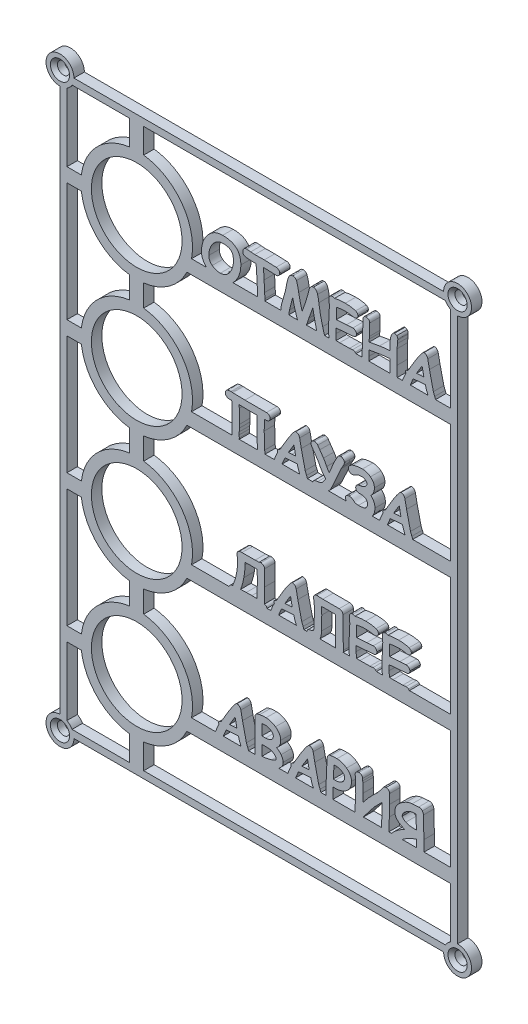
SolidWorks part; units mm, degrees
ref_plane "Спереди" through (0, 0, 0) normal (0, 0, 1) x (1, 0, 0)
ref_plane "Сверху" through (0, 0, 0) normal (0, 1, 0) x (1, 0, 0)
ref_plane "Справа" through (0, 0, 0) normal (1, 0, 0) x (0, 0, -1)
sketch "Эскиз1" plane through (0, 0, 0) normal (0, 0, 1) x (1, 0, 0)
  line L0 (-55, 80) -> (-35, 80)
  line L1 (-55, 80) -> (55, 80)
  line L2 (-55, 80) -> (-55, -80)
  line L3 (-55, -80) -> (55, -80)
  line L4 (55, 80) -> (55, -80)
  line L5 (-55, 80) -> (55, -80) construction
  line L6 (-55, -80) -> (55, 80) construction
  line L8 (-35, -57) -> (-35, -19)
  line L9 (-35, -19) -> (-35, 19)
  line L10 (-35, 19) -> (-35, 57)
  line L11 (-35, -57) -> (-35, -80)
  line L12 (-35, 57) -> (-35, 80)
  line L13 (-57, 82) -> (57, 82)
  line L14 (-57, 82) -> (-57, -82)
  line L15 (-57, -82) -> (57, -82)
  line L16 (57, 82) -> (57, -82)
  line L17 (-57, 82) -> (57, -82) construction
  line L18 (-57, -82) -> (57, 82) construction
  circle A0 centre (-35, -57) radius 13
  circle A1 centre (-35, -19) radius 13
  circle A2 centre (-35, 19) radius 13
  circle A3 centre (-35, 57) radius 13
  circle A4 centre (-35, 57) radius 16
  circle A5 centre (-35, 19) radius 16
  circle A6 centre (-35, -19) radius 16
  circle A7 centre (-35, -57) radius 16
  point P0 (0, 0)
  point P20 (0, 0)
  dimension "D5" = 114
  dimension "D1" = 110
  dimension "D2" = 160
  dimension "D3" = 20
  dimension "D4" = 23
  dimension "D6" = 38
  dimension "D7" = 164
extrude "Бобышка-Вытянуть1" add sketch "Эскиз1" against normal blind 3 contours L16 L13 L14 L15 L1 L4 L3 L2 L0 | L10 A4 L12 A3 | L12 A4 L10 A3 | L9 A5 L10 A2 | L10 A5 L9 A2 | L8 A6 L9 A1 | L9 A6 L8 A1 | L11 A7 L8 A0 | L8 A7 L11 A0 region at (-23.9393, 68.0607, 0) region at (-35.3578, 71.5, 0) region at (-50.6422, -57, 0) region at (-34.6422, -71.5, 0) region at (-23.9393, 30.0607, 0) region at (-35.3578, 33.5, 0) region at (-50.6422, -19, 0) region at (-34.6422, -33.5, 0) region at (0, 80.0027, 0)
sketch "Эскиз2" plane through (0, 0, 0) normal (0, 0, 1) x (1, 0, 0)
  line L1 (-55, 80) -> (55, 80) construction
  line L3 (-55, -80) -> (55, -80) construction
  line L4 (-35, -80) -> (-37, -80)
  line L5 (-37, -80) -> (-37, 80)
  line L6 (-37, 80) -> (-33, 80)
  line L7 (-33, 80) -> (-33, -80)
  line L8 (-33, -80) -> (-37, -80)
  circle A0 centre (-35, 57) radius 13
  circle A1 centre (-35, 57) radius 16
  circle A2 centre (-35, 19) radius 13
  circle A3 centre (-35, 19) radius 16
  circle A4 centre (-35, -19) radius 13
  circle A5 centre (-35, -19) radius 16
  circle A6 centre (-35, -57) radius 13
  circle A7 centre (-35, -57) radius 16
  circle M3 centre (-35, 19) radius 16
  dimension "D1" = 2
  dimension "D2" = 2
extrude "Бобышка-Вытянуть2" add sketch "Эскиз2" against normal blind 3 contours A7 L5 L4 L8 L7 | A7 L7 A5 L5 | A5 L7 L5 M3 | A1 L5 L7 M3 | A1 L7 L6 L5 region at (-35, -76.479, 0) region at (-35, -38, 0) region at (-35, 0, 0) region at (-35, 38, 0) region at (-35, 76.479, 0)
sketch "Эскиз3" plane through (0, 0, 0) normal (0, 0, 1) x (1, 0, 0)
  line L0 (-35, 17) -> (-55, 17)
  line L1 (-55, 80) -> (-55, -80) construction
  line L2 (-55, 57) -> (-55, 59)
  line L3 (-55, 59) -> (-35, 59)
  line L4 (-35, 59) -> (-35, 55)
  line L5 (-35, 55) -> (-55, 55)
  line L6 (-55, 55) -> (-55, 57)
  line L7 (-35, 21) -> (-35, 17)
  line L8 (-55, 21) -> (-35, 21)
  line L9 (-55, 17) -> (-55, 19)
  line L10 (-55, 19) -> (-55, 21)
  line L11 (-35, -21) -> (-55, -21)
  line L12 (-35, -17) -> (-35, -21)
  line L13 (-55, -17) -> (-35, -17)
  line L14 (-55, -21) -> (-55, -19)
  line L15 (-55, -19) -> (-55, -17)
  line L16 (-35, -59) -> (-55, -59)
  line L17 (-35, -55) -> (-35, -59)
  line L18 (-55, -55) -> (-35, -55)
  line L19 (-55, -59) -> (-55, -57)
  line L20 (-55, -57) -> (-55, -55)
  circle A0 centre (-35, 57) radius 13
  circle A1 centre (-35, 57) radius 16
  circle A2 centre (-35, 19) radius 13
  circle A3 centre (-35, 19) radius 16
  circle A4 centre (-35, -19) radius 13
  circle A5 centre (-35, -19) radius 16
  circle A6 centre (-35, -57) radius 13
  circle A7 centre (-35, -57) radius 16
  arc M39 (-37, 72.8745) -> (-37, 41.1255) centre (-35, 57) ccw
  arc M41 (-37, 34.8745) -> (-37, 3.1255) centre (-35, 19) ccw
  arc M43 (-37, -3.1255) -> (-37, -34.8745) centre (-35, -19) ccw
  arc M45 (-37, -41.1255) -> (-37, -72.8745) centre (-35, -57) ccw
  line M48 (-55, -80) -> (-55, 80)
  circle M49 centre (-35, -57) radius 13
  circle M50 centre (-35, -19) radius 13
  circle M51 centre (-35, 19) radius 13
  circle M52 centre (-35, 57) radius 13
  dimension "D1" = 2
  dimension "D2" = 2
  dimension "D3" = 4
extrude "Бобышка-Вытянуть4" add sketch "Эскиз3" against normal blind 3 contours L8 L0 M48 M41 | L8 L0 M41 M51 | L5 L3 M39 M48 | L5 L3 M52 M39 | L13 L11 M48 M43 | L13 L11 M43 M50 | L18 L16 M48 M45 | L18 L16 M45 M49 region at (-49.4533, 19, 0) region at (-52.9789, -57, 0) region at (-52.9789, -19, 0) region at (-52.9789, 57, 0) region at (-52.9789, 19, 0) region at (-49.4533, -19, 0) region at (-49.4533, 57, 0) region at (-49.4533, -57, 0)
sketch "Эскиз4" plane through (0, 0, 0) normal (0, 0, 1) x (1, 0, 0)
  line L0 (-55, 55) -> (-55, 50)
  line L1 (-55, 55) -> (-55, 21) construction
  line L2 (-55, 50) -> (55, 50)
  line L3 (55, 80) -> (55, -80) construction
  line L4 (-55, 17) -> (-55, 12)
  line L5 (-55, 17) -> (-55, -17) construction
  line L6 (-55, 12) -> (55, 12)
  line L7 (-50.8745, 17) -> (-55, 17) construction
  line L8 (-55, -21) -> (-55, -55) construction
  line L9 (-55, -26) -> (55, -26)
  line L10 (-55, -21) -> (-55, -26)
  line L11 (-55, -59) -> (-55, -80) construction
  line L12 (-55, -64) -> (55, -64)
  line L13 (55, 50) -> (55, 54)
  line L14 (55, 54) -> (-22.3509, 54)
  line L15 (-55, -59) -> (-55, -64)
  line L16 (55, 12) -> (55, 16)
  line L17 (55, 16) -> (-22.3509, 16)
  line L19 (55, -26) -> (55, -22)
  line L20 (55, -22) -> (-22.3509, -22)
  line L22 (55, -64) -> (55, -60)
  line L23 (55, -60) -> (-22.3509, -60)
  circle A0 centre (-35, 57) radius 13 construction
  circle A1 centre (-35, 19) radius 13 construction
  circle A2 centre (-35, -19) radius 13 construction
  circle A3 centre (-35, -57) radius 13 construction
  circle A4 centre (-35, 57) radius 13
  circle A5 centre (-35, 19) radius 13
  circle A6 centre (-35, -19) radius 13
  circle A7 centre (-35, -57) radius 13
  circle M17 centre (-35, -57) radius 13
  circle M29 centre (-35, -19) radius 13
  circle M41 centre (-35, 57) radius 13
  circle M42 centre (-35, 19) radius 13
  line M45 (55, 80) -> (55, -80)
  arc M48 (-33, -72.8745) -> (-33, -41.1255) centre (-35, -57) ccw
  arc M50 (-33, -34.8745) -> (-33, -3.1255) centre (-35, -19) ccw
  arc M52 (-33, 3.1255) -> (-33, 34.8745) centre (-35, 19) ccw
  arc M54 (-33, 41.1255) -> (-33, 72.8745) centre (-35, 57) ccw
  dimension "D1" = 5
  dimension "D2" = 4
  dimension "D3" = 4
  dimension "D4" = 4
  dimension "D5" = 4
extrude "Бобышка-Вытянуть6" add sketch "Эскиз4" against normal blind 3 contours L17 L6 M45 M52 | L17 L6 M52 M42 | L14 L2 M45 M54 | L14 L2 M54 M41 | L20 L9 M45 M50 | L20 L9 M50 M29 | L23 L12 M45 M48 | L23 L12 M48 M17 region at (17.574, -62.0059, 0) region at (17.574, -24.0059, 0) region at (17.574, 13.9941, 0) region at (-21.4722, 51.9627, 0) region at (17.574, 51.9941, 0) region at (-21.4722, 13.9627, 0) region at (-21.4722, -24.0373, 0) region at (-21.4722, -62.0373, 0)
sketch "Эскиз6" plane through (0, 0, 0) normal (0, 0, 1) x (1, 0, 0)
  line L0 (55, 54) -> (55, 53)
  line L1 (55, 53) -> (-20, 53)
  line L2 (55, 16) -> (55, 15)
  line L3 (55, 15) -> (-20, 15)
  line L4 (55, -22) -> (55, -23)
  line L5 (55, -23) -> (-20, -23)
  line L6 (55, -60) -> (55, -61)
  line L7 (55, -61) -> (-20, -61)
  line L8 (31.6782, 58.7841) -> (34.6254, 59.3)
  line L9 (14.0414, 61.6564) -> (14.4669, 63.3647)
  line L10 (16.7241, 53.5908) -> (16.2986, 55.3807)
  line L11 (14.3787, 56.0905) -> (13.9224, 54.7304)
  line L12 (11.2221, 53.5379) -> (10.7878, 54.9156)
  line L13 (-0.7694, 62.0289) -> (-1.153, 62.0289)
  line L14 (19.2635, -60.1822) -> (19.2635, -58.1101)
  line L15 (-1.0516, -60.2461) -> (-1.0516, -52.3039)
  line L16 (0.9235, -51.2657) -> (0.9235, -52.8242)
  line L17 (0.9235, -52.8242) -> (0.9235, -54.3694)
  line L18 (0.9235, -56.4855) -> (0.9235, -59.4482)
  line L19 (18.3553, -11.7139) -> (23.0659, -11.7139)
  line L20 (-4.821, -11.7293) -> (-1.0516, -11.7139)
  line L21 (1.6179, -21.2961) -> (1.6774, -21.3269)
  line L22 (-3.9657, 26.5683) -> (2.213, 26.5529)
  spline S0 degree 3 poles (49.6589, 52.7178) (49.5525, 52.7214) (49.3906, 52.7814) (49.2026, 52.9332) (49.0532, 53.0929) (48.9068, 53.2971) (48.6922, 53.6439) (48.5579, 53.9406) (48.4663, 54.1507) knots 0 0 0 0 0.162439 0.258631 0.370957 0.499126 0.645801 1 1 1 1
  spline S1 degree 3 poles (48.4663, 54.1507) (48.3224, 54.4696) (48.0641, 55.1602) (47.8603, 55.8686) (47.7698, 56.2448) knots 0 0 0 0 0.474794 1 1 1 1
  spline S2 degree 3 poles (47.7698, 56.2448) (47.6661, 56.2348) (47.5005, 56.2137) (47.265, 56.1956) (47.057, 56.1807) (46.8279, 56.1615) (46.4787, 56.1427) (46.2064, 56.1216) (46.0173, 56.1147) knots 0 0 0 0 0.177843 0.284813 0.403036 0.53386 0.677111 1 1 1 1
  spline S3 degree 3 poles (46.0173, 56.1147) (45.6804, 56.0972) (45.0953, 56.0564) (44.5117, 55.9972) (44.2649, 55.9626) knots 0 0 0 0 0.575221 1 1 1 1
  spline S4 degree 3 poles (44.2649, 55.9626) (44.2022, 55.7955) (44.0988, 55.5311) (43.9409, 55.1639) (43.8049, 54.8436) (43.6528, 54.4961) (43.4209, 53.9762) (43.2327, 53.5756) (43.1054, 53.2976) knots 0 0 0 0 0.184193 0.292924 0.412507 0.543245 0.684452 1 1 1 1
  spline S5 degree 3 poles (43.1054, 53.2976) (43.0556, 53.2062) (42.967, 53.0822) (42.8268, 52.9442) (42.7174, 52.8601) (42.5977, 52.797) (42.427, 52.7327) (42.289, 52.7184) (42.1972, 52.7178) knots 0 0 0 0 0.274963 0.400013 0.519329 0.63844 0.756484 1 1 1 1
  spline S6 degree 3 poles (42.1972, 52.7178) (42.0645, 52.7174) (41.8644, 52.7524) (41.6225, 52.8737) (41.4557, 52.995) (41.3106, 53.1432) (41.169, 53.3783) (41.1275, 53.5825) (41.1303, 53.7186) knots 0 0 0 0 0.245351 0.368053 0.497373 0.625143 0.748834 1 1 1 1
  spline S7 degree 3 poles (41.1303, 53.7186) (41.1308, 53.7612) (41.1446, 53.831) (41.168, 53.9331) (41.1978, 54.0307) (41.2352, 54.1431) (41.2819, 54.2699) (41.3343, 54.4115) (41.3969, 54.5662) (41.4672, 54.736) (41.5469, 54.92) (41.6318, 55.1195) (41.7304, 55.3305) (41.8338, 55.5576) (41.9834, 55.8912) (42.109, 56.1442) (42.1906, 56.3197) knots 0 0 0 0 0.045109 0.075672 0.11158 0.153653 0.20193 0.255425 0.31443 0.37969 0.451214 0.527981 0.61063 0.699237 0.793804 1 1 1 1
  spline S8 degree 2 poles (42.1906, 56.3197) (42.0946, 56.5279) (42.1024, 56.7562) knots 0 0 0 1 1 1
  spline S9 degree 3 poles (42.1024, 56.7562) (42.1067, 56.8163) (42.1375, 56.9055) (42.2157, 57.0082) (42.2944, 57.0823) (42.3953, 57.1489) (42.5634, 57.2385) (42.706, 57.2909) (42.8078, 57.3205) knots 0 0 0 0 0.18798 0.288531 0.402729 0.525543 0.6669 1 1 1 1
  spline S10 degree 3 poles (42.8078, 57.3205) (43.1591, 57.9547) (43.9103, 59.2405) (44.6877, 60.5106) (45.1003, 61.1538) knots 0 0 0 0 0.486852 1 1 1 1
  spline S11 degree 3 poles (45.1003, 61.1538) (45.2406, 61.3789) (45.4514, 61.7015) (45.7285, 62.1154) (45.9173, 62.3939) (46.0932, 62.6523) (46.2637, 62.8839) (46.4195, 63.0966) (46.5653, 63.2859) (46.6983, 63.4547) (46.8257, 63.5974) (46.9379, 63.7219) (47.0433, 63.82) (47.132, 63.9033) (47.2327, 63.9684) (47.3058, 64.0028) (47.3531, 64.004) knots 0 0 0 0 0.216629 0.314858 0.40693 0.491517 0.570164 0.641839 0.706915 0.765414 0.81731 0.863184 0.902244 0.934997 0.962302 1 1 1 1
  spline S12 degree 3 poles (47.3531, 64.004) (47.4818, 64.0039) (47.6751, 63.9783) (47.9024, 63.8675) (48.0543, 63.758) (48.1836, 63.613) (48.3474, 63.3734) (48.4206, 63.1566) (48.4663, 63.0076) knots 0 0 0 0 0.239154 0.352253 0.465098 0.583436 0.709751 1 1 1 1
  spline S13 degree 3 poles (48.4663, 63.0076) (48.4934, 62.8574) (48.5407, 62.6204) (48.6042, 62.2866) (48.6623, 61.9989) (48.7231, 61.6855) (48.8189, 61.2193) (48.8902, 60.8566) (48.9425, 60.6071) knots 0 0 0 0 0.187075 0.296244 0.416539 0.546904 0.687513 1 1 1 1
  spline S14 degree 3 poles (48.9425, 60.6071) (49.0248, 60.2349) (49.1433, 59.6655) (49.3191, 58.8967) (49.4551, 58.2894) (49.5981, 57.6626) (49.8011, 56.7879) (49.9596, 56.1234) (50.0667, 55.6738) knots 0 0 0 0 0.226012 0.344806 0.467617 0.594965 0.726002 1 1 1 1
  spline S15 degree 3 poles (50.0667, 55.6738) (50.0789, 55.6261) (50.1053, 55.5466) (50.1475, 55.4301) (50.1932, 55.3161) (50.2451, 55.1837) (50.3288, 54.9698) (50.4028, 54.804) (50.4524, 54.6863) knots 0 0 0 0 0.139366 0.236655 0.35049 0.486705 0.638739 1 1 1 1
  spline S16 degree 3 poles (50.4524, 54.6863) (50.5297, 54.5027) (50.6508, 54.1885) (50.7203, 53.8581) (50.7236, 53.7208) knots 0 0 0 0 0.593231 1 1 1 1
  spline S17 degree 3 poles (50.7236, 53.7208) (50.725, 53.5843) (50.685, 53.3794) (50.5439, 53.1421) (50.4021, 52.9894) (50.2356, 52.8636) (49.9923, 52.7446) (49.7916, 52.7104) (49.6589, 52.7178) knots 0 0 0 0 0.251443 0.373972 0.504224 0.63277 0.756223 1 1 1 1
  spline S18 degree 3 poles (46.8307, 60.4374) (46.7251, 60.2609) (46.5592, 59.9858) (46.3312, 59.6032) (46.1355, 59.2858) (45.9292, 58.9443) (45.6267, 58.4448) (45.3914, 58.0603) (45.2304, 57.7966) knots 0 0 0 0 0.199801 0.312189 0.432662 0.562069 0.6998 1 1 1 1
  spline S19 degree 3 poles (45.2304, 57.7966) (45.3726, 57.8153) (45.719, 57.859) (46.0682, 57.8664) (46.273, 57.8804) knots 0 0 0 0 0.411311 1 1 1 1
  spline S20 degree 3 poles (46.273, 57.8804) (46.4001, 57.8861) (46.581, 57.8932) (46.8094, 57.907) (46.952, 57.9128) (47.0754, 57.9196) (47.2011, 57.9271) (47.2855, 57.9351) (47.3355, 57.9377) knots 0 0 0 0 0.358766 0.510218 0.645014 0.761188 0.85875 1 1 1 1
  spline S21 degree 3 poles (47.3355, 57.9377) (47.3007, 58.1093) (47.2525, 58.3775) (47.1779, 58.746) (47.1158, 59.0492) (47.0529, 59.3708) (46.954, 59.8345) (46.8856, 60.1936) (46.8307, 60.4374) knots 0 0 0 0 0.205969 0.320562 0.442276 0.570092 0.706048 1 1 1 1
  spline S22 degree 3 poles (39.8408, 63.3757) (39.8059, 63.2082) (39.7612, 62.8936) (39.7369, 62.5768) (39.7372, 62.4301) knots 0 0 0 0 0.538507 1 1 1 1
  spline S23 degree 3 poles (39.7372, 62.4301) (39.7358, 62.3419) (39.7329, 62.1956) (39.7218, 61.9811) (39.7078, 61.7873) (39.6982, 61.5925) (39.6862, 61.378) (39.6836, 61.2309) (39.6821, 61.1428) knots 0 0 0 0 0.205333 0.340639 0.50005 0.657652 0.794667 1 1 1 1
  spline S24 degree 3 poles (39.6821, 61.1428) (39.6829, 61.0105) (39.6813, 60.8018) (39.6757, 60.5086) (39.6684, 60.2566) (39.6626, 59.9833) (39.6533, 59.6886) (39.6427, 59.3727) (39.6284, 59.0421) (39.6189, 58.7114) (39.6071, 58.3955) (39.5981, 58.1008) (39.5922, 57.8275) (39.5849, 57.5755) (39.5793, 57.2823) (39.5777, 57.0736) (39.5785, 56.9413) knots 0 0 0 0 0.094407 0.148962 0.209296 0.274349 0.344135 0.419704 0.500009 0.580296 0.655865 0.725651 0.790704 0.851038 0.905593 1 1 1 1
  spline S25 degree 3 poles (39.5785, 56.9413) (39.5814, 56.8392) (39.5795, 56.6782) (39.5906, 56.452) (39.595, 56.2571) (39.6083, 56.0457) (39.6172, 55.8177) (39.6349, 55.5733) (39.6479, 55.3166) (39.6677, 55.0605) (39.6786, 54.8156) (39.6942, 54.588) (39.7008, 54.3769) (39.7119, 54.1823) (39.7151, 53.9567) (39.7224, 53.7958) (39.7196, 53.6944) knots 0 0 0 0 0.094271 0.14856 0.208948 0.274137 0.344068 0.41949 0.500328 0.581208 0.656591 0.726558 0.791715 0.851453 0.906399 1 1 1 1
  spline S26 degree 3 poles (39.7196, 53.6944) (39.7202, 53.5654) (39.6866, 53.3703) (39.5577, 53.1443) (39.4304, 52.9947) (39.275, 52.8725) (39.0355, 52.7481) (38.831, 52.7185) (38.6946, 52.7178) knots 0 0 0 0 0.245865 0.365917 0.490741 0.617034 0.739459 1 1 1 1
  spline S27 degree 3 poles (38.6946, 52.7178) (38.555, 52.7184) (38.3456, 52.7496) (38.0927, 52.8674) (37.9244, 52.9876) (37.7843, 53.1334) (37.6433, 53.3527) (37.6019, 53.5451) (37.6034, 53.6723) knots 0 0 0 0 0.260733 0.387674 0.517375 0.644376 0.762644 1 1 1 1
  spline S28 degree 3 poles (37.6034, 53.6723) (37.6047, 53.8972) (37.601, 54.2675) (37.5996, 54.8068) (37.5938, 55.2903) (37.5927, 55.7745) (37.59, 56.3138) (37.5869, 56.6842) (37.588, 56.9083) knots 0 0 0 0 0.208446 0.343323 0.500002 0.656677 0.792235 1 1 1 1
  spline S29 degree 2 poles (37.588, 56.9083) (37.5881, 57.2821) (37.6034, 57.6555) knots 0 0 0 1 1 1
  spline S30 degree 3 poles (37.6034, 57.6555) (37.39, 57.6483) (37.0622, 57.6253) (36.6133, 57.5855) (36.2503, 57.5458) (35.8691, 57.4966) (35.3248, 57.4214) (34.9083, 57.3579) (34.6254, 57.3095) knots 0 0 0 0 0.213513 0.328601 0.450559 0.578701 0.71296 1 1 1 1
  spline S31 degree 2 poles (34.6254, 57.3095) (33.1515, 57.061) (31.6782, 56.8091) knots 0 0 0 1 1 1
  spline S32 degree 3 poles (31.6782, 56.8091) (31.6738, 56.7173) (31.6728, 56.5687) (31.6596, 56.358) (31.6519, 56.1698) (31.6406, 55.9626) (31.6211, 55.6459) (31.6108, 55.3981) (31.5966, 55.2264) knots 0 0 0 0 0.173944 0.281182 0.399534 0.530457 0.673956 1 1 1 1
  spline S33 degree 3 poles (31.5966, 55.2264) (31.5773, 54.9312) (31.5517, 54.3994) (31.538, 53.8671) (31.5371, 53.6304) knots 0 0 0 0 0.555495 1 1 1 1
  spline S34 degree 3 poles (31.5371, 53.6304) (31.5383, 53.5099) (31.5036, 53.3274) (31.3801, 53.1162) (31.2561, 52.9773) (31.1064, 52.8632) (30.8762, 52.7463) (30.6798, 52.7198) (30.5496, 52.7178) knots 0 0 0 0 0.241597 0.362319 0.486432 0.612478 0.737592 1 1 1 1
  spline S35 degree 3 poles (30.5496, 52.7178) (30.4185, 52.7176) (30.2227, 52.7496) (29.9894, 52.8666) (29.8408, 52.989) (29.7168, 53.1331) (29.5957, 53.3536) (29.5607, 53.5407) (29.5621, 53.6657) knots 0 0 0 0 0.257921 0.382655 0.509045 0.634131 0.754425 1 1 1 1
  spline S36 degree 3 poles (29.5621, 53.6657) (29.5635, 53.8031) (29.5653, 54.02) (29.5778, 54.3241) (29.5887, 54.5857) (29.6016, 54.8708) (29.6192, 55.178) (29.642, 55.5078) (29.6657, 55.8524) (29.6894, 56.1977) (29.7122, 56.5275) (29.729, 56.8348) (29.7456, 57.119) (29.7556, 57.3814) (29.7681, 57.6855) (29.77, 57.9024) (29.7715, 58.0391) knots 0 0 0 0 0.094143 0.148544 0.208497 0.273502 0.344088 0.419259 0.499988 0.580716 0.656389 0.726473 0.791503 0.851457 0.906361 1 1 1 1
  spline S37 degree 3 poles (29.7715, 58.0391) (29.7701, 58.2132) (29.7737, 58.4888) (29.7753, 58.8753) (29.7808, 59.2088) (29.7842, 59.5718) (29.7919, 59.9642) (29.7976, 60.386) (29.8068, 60.8275) (29.8158, 61.2691) (29.8219, 61.6916) (29.8284, 62.0848) (29.8356, 62.4484) (29.8402, 62.7828) (29.842, 63.17) (29.8456, 63.4463) (29.8442, 63.6204) knots 0 0 0 0 0.093594 0.148092 0.207728 0.272892 0.343195 0.418631 0.499602 0.580573 0.656009 0.726707 0.791877 0.851513 0.906406 1 1 1 1
  spline S38 degree 3 poles (29.8442, 63.6204) (29.8429, 63.7454) (29.8779, 63.9325) (29.999, 64.153) (30.123, 64.2971) (30.2716, 64.4195) (30.5048, 64.5365) (30.7006, 64.5686) (30.8317, 64.5683) knots 0 0 0 0 0.245575 0.365869 0.490955 0.617345 0.742079 1 1 1 1
  spline S39 degree 3 poles (30.8317, 64.5683) (30.9635, 64.5703) (31.1579, 64.5343) (31.3908, 64.4169) (31.5386, 64.2926) (31.6619, 64.1457) (31.7882, 63.9229) (31.8185, 63.7298) (31.8193, 63.6028) knots 0 0 0 0 0.256091 0.378476 0.504683 0.629788 0.750993 1 1 1 1
  spline S40 degree 3 poles (31.8193, 63.6028) (31.8199, 63.4977) (31.8188, 63.3316) (31.8121, 63.098) (31.8088, 62.8966) (31.801, 62.677) (31.7953, 62.4403) (31.7864, 62.1854) (31.7745, 61.9195) (31.7667, 61.6527) (31.7583, 61.3984) (31.7478, 61.1619) (31.7447, 60.9429) (31.7403, 60.7416) (31.7339, 60.508) (31.7327, 60.3419) (31.7333, 60.2368) knots 0 0 0 0 0.093616 0.147965 0.208205 0.273043 0.34377 0.419097 0.500337 0.580898 0.65688 0.726974 0.791795 0.852035 0.906384 1 1 1 1
  spline S41 degree 3 poles (31.7333, 60.2368) (31.7303, 60.1471) (31.7203, 59.9106) (31.6919, 59.6754) (31.6782, 59.5292) knots 0 0 0 0 0.379284 1 1 1 1
  spline S42 degree 3 poles (31.6782, 59.5292) (31.6752, 59.3859) (31.6768, 59.1376) (31.6752, 58.8892) (31.6782, 58.7841) knots 0 0 0 0 0.576916 1 1 1 1
  spline S43 degree 3 poles (34.6254, 59.3) (34.9024, 59.3475) (35.3115, 59.4087) (35.8478, 59.4807) (36.2275, 59.5278) (36.5928, 59.5653) (37.0497, 59.6021) (37.385, 59.6222) (37.6034, 59.6306) knots 0 0 0 0 0.281159 0.413934 0.541324 0.664002 0.781286 1 1 1 1
  spline S44 degree 3 poles (37.6034, 59.6306) (37.6113, 59.7495) (37.6204, 59.9538) (37.6303, 60.2618) (37.6414, 60.5719) (37.6552, 60.9355) (37.6735, 61.5256) (37.6854, 61.9944) (37.696, 62.3243) knots 0 0 0 0 0.132653 0.227577 0.342964 0.477994 0.632642 1 1 1 1
  spline S45 degree 3 poles (37.696, 62.3243) (37.7023, 62.5335) (37.7757, 62.9875) (37.9308, 63.4199) (38.0267, 63.6491) knots 0 0 0 0 0.456707 1 1 1 1
  spline S46 degree 3 poles (38.0267, 63.6491) (38.0853, 63.7865) (38.1774, 63.9799) (38.3264, 64.2048) (38.4333, 64.3369) (38.5457, 64.4384) (38.6948, 64.5372) (38.8236, 64.566) (38.9062, 64.5683) knots 0 0 0 0 0.334673 0.476909 0.602972 0.713541 0.814772 1 1 1 1
  spline S47 degree 3 poles (38.9062, 64.5683) (39.024, 64.5695) (39.2649, 64.5266) (39.4674, 64.3899) (39.5565, 64.3082) knots 0 0 0 0 0.493157 1 1 1 1
  spline S48 degree 3 poles (39.5565, 64.3082) (39.6517, 64.2181) (39.8168, 64.0011) (39.8584, 63.7319) (39.8607, 63.6006) knots 0 0 0 0 0.499013 1 1 1 1
  spline S49 degree 2 poles (39.8607, 63.6006) (39.8617, 63.4872) (39.8408, 63.3757) knots 0 0 0 1 1 1
  spline S50 degree 2 poles (27.4128, 62.7343) (27.2559, 62.7362) (27.102, 62.7674) knots 0 0 0 1 1 1
  spline S51 degree 3 poles (27.102, 62.7674) (26.7111, 62.8456) (25.9383, 62.9756) (25.1555, 63.0155) (24.7721, 63.0164) knots 0 0 0 0 0.509816 1 1 1 1
  spline S52 degree 3 poles (24.7721, 63.0164) (24.3735, 63.016) (23.5191, 62.9599) (22.6743, 62.8216) (22.2261, 62.7343) knots 0 0 0 0 0.465868 1 1 1 1
  spline S53 degree 3 poles (22.2261, 62.7343) (22.2261, 62.5388) (22.2261, 62.2302) (22.2261, 61.7975) (22.2261, 61.4257) (22.2261, 61.0215) (22.2261, 60.4198) (22.2261, 59.9524) (22.2261, 59.6306) knots 0 0 0 0 0.18892 0.298295 0.418324 0.548295 0.68892 1 1 1 1
  spline S54 degree 3 poles (22.2261, 59.6306) (22.3394, 59.6344) (22.5412, 59.6504) (22.8537, 59.666) (23.1848, 59.6904) (23.5818, 59.7125) (24.2408, 59.7585) (24.7677, 59.7924) (25.1402, 59.818) knots 0 0 0 0 0.116451 0.207942 0.321423 0.457552 0.616425 1 1 1 1
  spline S55 degree 3 poles (25.1402, 59.818) (25.3555, 59.8309) (25.6624, 59.8537) (26.0506, 59.8747) (26.2923, 59.8877) (26.5009, 59.8998) (26.714, 59.9071) (26.8581, 59.9116) (26.9433, 59.9128) knots 0 0 0 0 0.358415 0.511242 0.645718 0.760626 0.85835 1 1 1 1
  spline S56 degree 3 poles (26.9433, 59.9128) (27.0815, 59.9106) (27.2899, 59.8836) (27.5362, 59.762) (27.7012, 59.6453) (27.8378, 59.4976) (27.9795, 59.2642) (28.0081, 59.0554) (28.0102, 58.9186) knots 0 0 0 0 0.255928 0.377518 0.502513 0.625976 0.745434 1 1 1 1
  spline S57 degree 3 poles (28.0102, 58.9186) (28.0095, 58.7885) (27.9864, 58.5982) (27.8841, 58.3737) (27.7775, 58.2362) (27.641, 58.1221) (27.4054, 58.002) (27.2039, 57.9557) (27.0624, 57.9377) knots 0 0 0 0 0.257263 0.370634 0.48214 0.597272 0.718395 1 1 1 1
  spline S58 degree 3 poles (27.0624, 57.9377) (26.9504, 57.932) (26.7736, 57.9143) (26.5253, 57.895) (26.3113, 57.8809) (26.0793, 57.8592) (25.733, 57.8335) (25.4642, 57.8099) (25.2791, 57.7944) knots 0 0 0 0 0.18787 0.297866 0.417691 0.547536 0.688433 1 1 1 1
  spline S59 degree 3 poles (25.2791, 57.7944) (25.08, 57.7738) (24.7648, 57.7426) (24.3217, 57.7006) (23.9397, 57.665) (23.5237, 57.6303) (22.9022, 57.5784) (22.4187, 57.5389) (22.085, 57.5145) knots 0 0 0 0 0.187228 0.296338 0.416463 0.546175 0.686906 1 1 1 1
  spline S60 degree 3 poles (22.085, 57.5145) (22.085, 57.2419) (22.085, 56.754) (22.085, 56.2661) (22.085, 56.0508) knots 0 0 0 0 0.558735 1 1 1 1
  spline S61 degree 3 poles (22.085, 56.0508) (22.0851, 55.8428) (22.0881, 55.5495) (22.1029, 55.1843) (22.1182, 54.9667) (22.1366, 54.7869) (22.1649, 54.62) (22.192, 54.5134) (22.2261, 54.4615) knots 0 0 0 0 0.388736 0.548204 0.683144 0.796443 0.885633 1 1 1 1
  spline S62 degree 3 poles (22.2261, 54.4615) (22.2516, 54.4388) (22.3111, 54.4181) (22.4072, 54.4025) (22.5146, 54.3892) (22.6462, 54.3783) (22.8711, 54.3703) (23.0519, 54.3671) (23.1805, 54.3667) knots 0 0 0 0 0.103773 0.191819 0.302046 0.439239 0.601168 1 1 1 1
  spline S63 degree 3 poles (23.1805, 54.3667) (23.3775, 54.3677) (23.7022, 54.3719) (24.1747, 54.38) (24.5986, 54.3891) (25.0226, 54.3961) (25.4957, 54.4104) (25.8206, 54.4076) (26.0175, 54.4108) knots 0 0 0 0 0.208221 0.343421 0.499608 0.656571 0.791786 1 1 1 1
  spline S64 degree 3 poles (26.0175, 54.4108) (26.0802, 54.4099) (26.1824, 54.4192) (26.3308, 54.4349) (26.4627, 54.4551) (26.5957, 54.4741) (26.7423, 54.4935) (26.8432, 54.5017) (26.9036, 54.5011) knots 0 0 0 0 0.210625 0.344969 0.502325 0.659682 0.796773 1 1 1 1
  spline S65 degree 3 poles (26.9036, 54.5011) (27.041, 54.5004) (27.3131, 54.4673) (27.5514, 54.3317) (27.6531, 54.2499) knots 0 0 0 0 0.513333 1 1 1 1
  spline S66 degree 3 poles (27.6531, 54.2499) (27.7674, 54.1613) (27.964, 53.9199) (28.0094, 53.6121) (28.0102, 53.4585) knots 0 0 0 0 0.483007 1 1 1 1
  spline S67 degree 3 poles (28.0102, 53.4585) (28.0118, 53.329) (27.9877, 53.1405) (27.8933, 52.9146) (27.7933, 52.7754) (27.6671, 52.6562) (27.4525, 52.5201) (27.2606, 52.4671) (27.1285, 52.4401) knots 0 0 0 0 0.261595 0.377865 0.49063 0.604993 0.726374 1 1 1 1
  spline S68 degree 3 poles (27.1285, 52.4401) (26.9699, 52.4129) (26.705, 52.3775) (26.3168, 52.3498) (25.95, 52.3308) (25.5334, 52.3121) (24.8765, 52.2986) (24.3584, 52.2943) (23.9961, 52.2946) knots 0 0 0 0 0.153782 0.255209 0.371963 0.504818 0.653748 1 1 1 1
  spline S69 degree 3 poles (23.9961, 52.2946) (23.6218, 52.2952) (23.0862, 52.3118) (22.4092, 52.3799) (21.9807, 52.4523) (21.6043, 52.5419) (21.1989, 52.6854) (20.9333, 52.8321) (20.7911, 52.9559) knots 0 0 0 0 0.337446 0.482644 0.61299 0.728978 0.831012 1 1 1 1
  spline S70 degree 3 poles (20.7911, 52.9559) (20.6431, 53.0896) (20.457, 53.347) (20.2797, 53.7534) (20.1637, 54.1236) (20.0752, 54.5467) (19.9874, 55.2138) (19.9707, 55.7434) (19.9688, 56.1125) knots 0 0 0 0 0.17801 0.281294 0.396801 0.525587 0.668611 1 1 1 1
  spline S71 degree 3 poles (19.9688, 56.1125) (19.9689, 56.3014) (19.9744, 56.6005) (19.9885, 57.02) (20.0041, 57.3815) (20.0241, 57.7746) (20.0484, 58.1993) (20.0771, 58.6564) (20.1099, 59.1346) (20.1427, 59.6129) (20.1714, 60.0699) (20.1957, 60.4946) (20.2157, 60.8877) (20.2313, 61.2492) (20.2454, 61.6673) (20.2509, 61.9649) (20.251, 62.1523) knots 0 0 0 0 0.093691 0.148397 0.208231 0.273195 0.343659 0.41926 0.500364 0.581469 0.65707 0.727534 0.792498 0.852332 0.907038 1 1 1 1
  spline S72 degree 3 poles (20.251, 62.1523) (20.2506, 62.2614) (20.2383, 62.4409) (20.2113, 62.7001) (20.1802, 62.9312) (20.15, 63.1616) (20.1224, 63.4208) (20.1104, 63.5996) (20.1099, 63.7086) knots 0 0 0 0 0.209002 0.345074 0.500002 0.656329 0.790998 1 1 1 1
  spline S73 degree 3 poles (20.1099, 63.7086) (20.1106, 63.8762) (20.1304, 64.1196) (20.2464, 64.4037) (20.3598, 64.5701) (20.5094, 64.6976) (20.7625, 64.8265) (20.9862, 64.8489) (21.1371, 64.8504) knots 0 0 0 0 0.287594 0.408397 0.520008 0.627541 0.740209 1 1 1 1
  spline S74 degree 3 poles (21.1371, 64.8504) (21.2422, 64.8514) (21.4544, 64.8208) (21.6446, 64.7225) (21.7323, 64.6631) knots 0 0 0 0 0.497622 1 1 1 1
  spline S75 degree 3 poles (21.7323, 64.6631) (22.0078, 64.7264) (22.4158, 64.8148) (22.9577, 64.8924) (23.7025, 64.9667) (24.3168, 64.9887) (24.8007, 64.9915) knots 0 0 0 0 0.274225 0.404527 0.530598 1 1 1 1
  spline S76 degree 3 poles (24.8007, 64.9915) (25.094, 64.9914) (25.5224, 64.9802) (26.0771, 64.9352) (26.4588, 64.8893) (26.8178, 64.8304) (27.253, 64.7367) (27.5632, 64.6426) (27.7589, 64.5683) knots 0 0 0 0 0.292974 0.427718 0.555605 0.676852 0.790995 1 1 1 1
  spline S77 degree 3 poles (27.7589, 64.5683) (27.862, 64.5314) (28.0094, 64.4648) (28.1694, 64.3335) (28.2684, 64.2313) (28.343, 64.1124) (28.4152, 63.9345) (28.4322, 63.7874) (28.4334, 63.6888) knots 0 0 0 0 0.276752 0.400331 0.519359 0.633221 0.750979 1 1 1 1
  spline S78 degree 3 poles (28.4334, 63.6888) (28.4312, 63.5735) (28.3909, 63.3348) (28.2496, 63.1379) (28.1667, 63.0517) knots 0 0 0 0 0.490728 1 1 1 1
  spline S79 degree 3 poles (28.1667, 63.0517) (28.0727, 62.9517) (27.8402, 62.7802) (27.5549, 62.7348) (27.4128, 62.7343) knots 0 0 0 0 0.491003 1 1 1 1
  spline S80 degree 3 poles (9.7011, 58.8944) (9.6415, 58.6697) (9.548, 58.3145) (9.4222, 57.8144) (9.3142, 57.3823) (9.1974, 56.9122) (9.0268, 56.2089) (8.895, 55.6628) (8.8039, 55.2859) knots 0 0 0 0 0.187498 0.296338 0.416105 0.5468 0.68713 1 1 1 1
  spline S81 degree 2 poles (8.8039, 55.2859) (8.6713, 54.4551) (8.5416, 53.6238) knots 0 0 0 1 1 1
  spline S82 degree 3 poles (8.5416, 53.6238) (8.4933, 53.4661) (8.4095, 53.2406) (8.2377, 52.9875) (8.1009, 52.8372) (7.9461, 52.7192) (7.7108, 52.6077) (7.515, 52.5738) (7.3822, 52.5768) knots 0 0 0 0 0.294006 0.421693 0.540742 0.653421 0.764832 1 1 1 1
  spline S83 degree 3 poles (7.3822, 52.5768) (7.2209, 52.5752) (6.9059, 52.6284) (6.6426, 52.8103) (6.5445, 52.9251) knots 0 0 0 0 0.518338 1 1 1 1
  spline S84 degree 3 poles (6.5445, 52.9251) (6.4567, 53.0178) (6.3317, 53.2439) (6.2798, 53.4968) (6.2844, 53.626) knots 0 0 0 0 0.496771 1 1 1 1
  spline S85 degree 3 poles (6.2844, 53.626) (6.2853, 53.8366) (6.3039, 54.1615) (6.3559, 54.6041) (6.4107, 54.9617) (6.4845, 55.3341) (6.6057, 55.866) (6.7149, 56.2706) (6.798, 56.5446) knots 0 0 0 0 0.212397 0.328092 0.449626 0.577295 0.711115 1 1 1 1
  spline S86 degree 3 poles (6.798, 56.5446) (6.8567, 56.7478) (6.9473, 57.0422) (7.0577, 57.4244) (7.1367, 57.683) (7.2054, 57.9248) (7.2734, 58.1481) (7.3311, 58.3546) (7.3876, 58.5421) (7.4353, 58.7123) (7.4794, 58.8634) (7.5184, 58.9967) (7.5464, 59.1133) (7.5783, 59.2103) (7.5995, 59.3061) (7.616, 59.3682) (7.6246, 59.4036) knots 0 0 0 0 0.213241 0.310499 0.400945 0.48579 0.563823 0.636255 0.701874 0.761184 0.81439 0.860576 0.901175 0.935154 0.963356 1 1 1 1
  spline S87 degree 2 poles (7.6246, 59.4036) (7.8408, 60.5418) (8.0655, 61.6784) knots 0 0 0 1 1 1
  spline S88 degree 3 poles (8.0655, 61.6784) (8.1139, 61.9193) (8.1994, 62.2622) (8.3208, 62.6963) (8.4099, 62.974) (8.5036, 63.2176) (8.5946, 63.431) (8.6903, 63.6111) (8.7899, 63.7613) (8.8926, 63.8869) (9.0008, 63.9939) (9.1177, 64.0832) (9.2395, 64.1574) (9.3676, 64.2171) (9.5507, 64.2694) (9.6943, 64.2858) (9.7915, 64.2861) knots 0 0 0 0 0.217238 0.312487 0.398598 0.475119 0.543217 0.603695 0.655245 0.702342 0.746919 0.789555 0.832131 0.872845 0.914178 1 1 1 1
  spline S89 degree 3 poles (9.7915, 64.2861) (9.899, 64.285) (10.0585, 64.2676) (10.2556, 64.1958) (10.388, 64.1185) (10.5095, 64.0216) (10.6593, 63.857) (10.7497, 63.7113) (10.7989, 63.605) knots 0 0 0 0 0.250151 0.368421 0.484653 0.604878 0.728082 1 1 1 1
  spline S90 degree 3 poles (10.7989, 63.605) (10.8604, 63.4738) (10.9403, 63.2498) (11.0377, 62.9209) (11.1166, 62.6125) (11.1974, 62.2626) (11.3153, 61.7126) (11.3926, 61.2769) (11.4469, 60.973) knots 0 0 0 0 0.159855 0.262309 0.378839 0.511326 0.65904 1 1 1 1
  spline S91 degree 3 poles (11.4469, 60.973) (11.561, 60.3005) (11.8543, 58.9055) (12.2234, 57.5287) (12.4323, 56.8157) knots 0 0 0 0 0.478619 1 1 1 1
  spline S92 degree 3 poles (12.4323, 56.8157) (12.7317, 57.5794) (13.3065, 59.181) (13.8021, 60.8088) (14.0414, 61.6564) knots 0 0 0 0 0.482242 1 1 1 1
  spline S93 degree 3 poles (14.4669, 63.3647) (14.5274, 63.5258) (14.6312, 63.753) (14.8164, 64.0116) (14.962, 64.1646) (15.1242, 64.2809) (15.3575, 64.3974) (15.5542, 64.4247) (15.6836, 64.4272) knots 0 0 0 0 0.299085 0.429616 0.550393 0.663588 0.774171 1 1 1 1
  spline S94 degree 3 poles (15.6836, 64.4272) (15.8113, 64.4271) (16.0034, 64.3879) (16.2311, 64.2585) (16.3871, 64.1203) (16.5278, 63.9433) (16.708, 63.6413) (16.8058, 63.3812) (16.8652, 63.1972) knots 0 0 0 0 0.208755 0.313828 0.425552 0.547892 0.682853 1 1 1 1
  spline S95 degree 3 poles (16.8652, 63.1972) (16.898, 63.0979) (16.9408, 62.9333) (16.9958, 62.6952) (17.0397, 62.4761) (17.0832, 62.2306) (17.1444, 61.8493) (17.1901, 61.5503) (17.2178, 61.3412) knots 0 0 0 0 0.165747 0.269796 0.387518 0.520126 0.665373 1 1 1 1
  spline S96 degree 3 poles (17.2178, 61.3412) (17.2878, 60.8324) (17.4017, 60.0842) (17.5705, 59.1076) (17.7068, 58.4174) (17.8434, 57.7545) (18.0372, 56.9257) (18.2005, 56.3222) (18.3134, 55.9295) knots 0 0 0 0 0.278797 0.410804 0.538003 0.660667 0.778224 1 1 1 1
  spline S97 degree 3 poles (18.3134, 55.9295) (18.3673, 55.75) (18.442, 55.4874) (18.5385, 55.1483) (18.6053, 54.9195) (18.6649, 54.7062) (18.7195, 54.5101) (18.7687, 54.3293) (18.8119, 54.1653) (18.8524, 54.018) (18.8853, 53.8869) (18.9137, 53.7723) (18.939, 53.6735) (18.9556, 53.5907) (18.9718, 53.514) (18.9812, 53.4648) (18.9813, 53.4365) knots 0 0 0 0 0.217741 0.31717 0.409566 0.494691 0.574425 0.646072 0.71233 0.77155 0.823515 0.869269 0.908813 0.941961 0.96724 1 1 1 1
  spline S98 degree 3 poles (18.9813, 53.4365) (18.9815, 53.2991) (18.9246, 53.0177) (18.7447, 52.7937) (18.6374, 52.7024) knots 0 0 0 0 0.49355 1 1 1 1
  spline S99 degree 3 poles (18.6374, 52.7024) (18.5344, 52.6189) (18.3062, 52.4779) (18.0412, 52.4376) (17.9122, 52.4357) knots 0 0 0 0 0.507036 1 1 1 1
  spline S100 degree 3 poles (17.9122, 52.4357) (17.784, 52.4337) (17.592, 52.4716) (17.364, 52.5952) (17.2073, 52.7246) (17.0638, 52.8892) (16.8851, 53.1735) (16.7814, 53.416) (16.7241, 53.5908) knots 0 0 0 0 0.215867 0.322944 0.43488 0.55701 0.689775 1 1 1 1
  spline S101 degree 3 poles (16.2986, 55.3807) (16.2292, 55.6249) (16.1382, 56.0129) (16.012, 56.5539) (15.9167, 57.0144) (15.8173, 57.5103) (15.6775, 58.2438) (15.5766, 58.8131) (15.5095, 59.2052) knots 0 0 0 0 0.1949 0.306051 0.426571 0.556049 0.694496 1 1 1 1
  spline S102 degree 3 poles (15.5095, 59.2052) (15.4443, 59.016) (15.3388, 58.7144) (15.1861, 58.2902) (15.0506, 57.9187) (14.904, 57.511) (14.6773, 56.8979) (14.5, 56.4206) (14.3787, 56.0905) knots 0 0 0 0 0.181141 0.289295 0.40819 0.539077 0.681559 1 1 1 1
  spline S103 degree 3 poles (13.9224, 54.7304) (13.8378, 54.4816) (13.6623, 54.0308) (13.4489, 53.5965) (13.3382, 53.4056) knots 0 0 0 0 0.543615 1 1 1 1
  spline S104 degree 3 poles (13.3382, 53.4056) (13.2787, 53.2984) (13.1755, 53.1514) (13.012, 52.9849) (12.8808, 52.8874) (12.7406, 52.8112) (12.5373, 52.7393) (12.3749, 52.7172) (12.2647, 52.7178) knots 0 0 0 0 0.273684 0.399051 0.519875 0.637398 0.754231 1 1 1 1
  spline S105 degree 3 poles (12.2647, 52.7178) (12.1567, 52.7186) (11.9944, 52.7415) (11.7959, 52.8292) (11.6587, 52.9208) (11.5312, 53.0372) (11.372, 53.2369) (11.2769, 53.412) (11.2221, 53.5379) knots 0 0 0 0 0.230027 0.342624 0.458721 0.57923 0.708027 1 1 1 1
  spline S106 degree 3 poles (10.7878, 54.9156) (10.5825, 55.5588) (10.1905, 56.8773) (9.8603, 58.2127) (9.7011, 58.8944) knots 0 0 0 0 0.490965 1 1 1 1
  spline S107 degree 3 poles (4.9552, 62.0289) (4.845, 62.0316) (4.67, 62.0305) (4.4232, 62.0401) (4.208, 62.0495) (3.972, 62.0568) (3.6179, 62.0767) (3.3423, 62.0918) (3.1521, 62.1039) knots 0 0 0 0 0.183209 0.290744 0.41053 0.541299 0.683157 1 1 1 1
  spline S108 degree 3 poles (3.1521, 62.1039) (2.9671, 62.1182) (2.6979, 62.1281) (2.3505, 62.1488) (2.116, 62.1566) (1.8986, 62.1636) (1.6443, 62.1692) (1.4621, 62.1708) (1.3467, 62.17) knots 0 0 0 0 0.307909 0.447177 0.577804 0.697416 0.808459 1 1 1 1
  spline S109 degree 3 poles (1.3467, 62.17) (1.3515, 62.0001) (1.3663, 61.7254) (1.3837, 61.3307) (1.4078, 60.9731) (1.4301, 60.5731) (1.476, 59.9577) (1.506, 59.4747) (1.5319, 59.139) knots 0 0 0 0 0.167837 0.271762 0.390303 0.52193 0.667461 1 1 1 1
  spline S110 degree 3 poles (1.5319, 59.139) (1.5552, 58.835) (1.5823, 58.3911) (1.6209, 57.8159) (1.6398, 57.4219) (1.6557, 57.0531) (1.6698, 56.6122) (1.6752, 56.294) (1.6752, 56.0905) knots 0 0 0 0 0.299641 0.437117 0.56654 0.687239 0.799948 1 1 1 1
  spline S111 degree 3 poles (1.6752, 56.0905) (1.6748, 55.9853) (1.6821, 55.8124) (1.7026, 55.5614) (1.7205, 55.3372) (1.7437, 55.1127) (1.7623, 54.8614) (1.7707, 54.6879) (1.77, 54.5827) knots 0 0 0 0 0.208736 0.343314 0.499934 0.65523 0.791262 1 1 1 1
  spline S112 degree 3 poles (1.77, 54.5827) (1.77, 54.4052) (1.7496, 54.0644) (1.6776, 53.7307) (1.6289, 53.5753) knots 0 0 0 0 0.521831 1 1 1 1
  spline S113 degree 3 poles (1.6289, 53.5753) (1.5806, 53.4861) (1.4982, 53.3608) (1.3612, 53.2244) (1.2551, 53.1404) (1.1378, 53.0791) (0.9706, 53.0143) (0.8336, 53.0011) (0.7427, 53) knots 0 0 0 0 0.273542 0.399367 0.519192 0.635961 0.754211 1 1 1 1
  spline S114 degree 3 poles (0.7427, 53) (0.6105, 52.9988) (0.3446, 53.0407) (0.1115, 53.1751) (0.0087, 53.2579) knots 0 0 0 0 0.500404 1 1 1 1
  spline S115 degree 3 poles (0.0087, 53.2579) (-0.0987, 53.3479) (-0.289, 53.5632) (-0.3468, 53.845) (-0.3462, 53.9809) knots 0 0 0 0 0.508702 1 1 1 1
  spline S116 degree 3 poles (-0.3462, 53.9809) (-0.3462, 54.0853) (-0.3462, 54.2969) (-0.3462, 54.5085) (-0.3462, 54.6158) knots 0 0 0 0 0.493056 1 1 1 1
  spline S117 degree 3 poles (-0.3462, 54.6158) (-0.3452, 54.7577) (-0.3549, 54.9921) (-0.3702, 55.3338) (-0.3903, 55.6408) (-0.4104, 55.9485) (-0.4257, 56.2932) (-0.4355, 56.5305) (-0.4344, 56.6746) knots 0 0 0 0 0.206504 0.341416 0.497862 0.654308 0.790288 1 1 1 1
  spline S118 degree 3 poles (-0.4344, 56.6746) (-0.4344, 56.8539) (-0.4396, 57.1339) (-0.4539, 57.5219) (-0.4696, 57.8452) (-0.4888, 58.1906) (-0.5271, 58.6946) (-0.5544, 59.0841) (-0.5777, 59.3507) knots 0 0 0 0 0.200679 0.313413 0.434431 0.562927 0.700609 1 1 1 1
  spline S119 degree 3 poles (-0.5777, 59.3507) (-0.6024, 59.649) (-0.6416, 60.077) (-0.68, 60.6241) (-0.7071, 60.9774) (-0.7292, 61.2933) (-0.7514, 61.6393) (-0.7639, 61.8804) (-0.7694, 62.0289) knots 0 0 0 0 0.334446 0.480134 0.612663 0.730336 0.833976 1 1 1 1
  spline S120 degree 3 poles (-1.153, 62.0289) (-1.4124, 62.0289) (-1.7916, 62.0328) (-2.2824, 62.0475) (-2.619, 62.0629) (-2.9343, 62.0826) (-3.3132, 62.1134) (-3.5864, 62.1445) (-3.7607, 62.17) knots 0 0 0 0 0.297748 0.435289 0.563623 0.684469 0.797866 1 1 1 1
  spline S121 degree 3 poles (-3.7607, 62.17) (-3.8847, 62.2036) (-4.0621, 62.27) (-4.2601, 62.4111) (-4.3777, 62.5327) (-4.4697, 62.6738) (-4.5583, 62.897) (-4.5769, 63.0824) (-4.5785, 63.2082) knots 0 0 0 0 0.26815 0.388688 0.503338 0.618294 0.737003 1 1 1 1
  spline S122 degree 3 poles (-4.5785, 63.2082) (-4.5764, 63.338) (-4.5359, 63.6041) (-4.3964, 63.8346) (-4.3118, 63.9378) knots 0 0 0 0 0.493089 1 1 1 1
  spline S123 degree 3 poles (-4.3118, 63.9378) (-4.2186, 64.0597) (-3.9668, 64.2564) (-3.6505, 64.3017) (-3.4962, 64.2861) knots 0 0 0 0 0.496856 1 1 1 1
  spline S124 degree 3 poles (-3.4962, 64.2861) (-3.4388, 64.2831) (-3.3426, 64.2767) (-3.2008, 64.2659) (-3.0641, 64.2549) (-2.9069, 64.2413) (-2.6554, 64.2207) (-2.4568, 64.197) (-2.3169, 64.1869) knots 0 0 0 0 0.145572 0.244564 0.360412 0.493119 0.644542 1 1 1 1
  spline S125 degree 3 poles (-2.3169, 64.1869) (-2.096, 64.166) (-1.7012, 64.1325) (-1.3052, 64.1167) (-1.1309, 64.1164) knots 0 0 0 0 0.560104 1 1 1 1
  spline S126 degree 3 poles (-1.1309, 64.1164) (-0.9428, 64.1134) (-0.6328, 64.1223) (-0.1816, 64.1218) (0.2225, 64.1299) (0.6266, 64.1364) (1.0778, 64.1407) (1.3878, 64.1474) (1.576, 64.1451) knots 0 0 0 0 0.208465 0.343637 0.499996 0.656356 0.791535 1 1 1 1
  spline S127 degree 3 poles (1.576, 64.1451) (1.6818, 64.1478) (1.8493, 64.1406) (2.0845, 64.1374) (2.2872, 64.1263) (2.5071, 64.1197) (2.7442, 64.1041) (2.9994, 64.0932) (3.2666, 64.0734) (3.5342, 64.0603) (3.789, 64.0427) (4.0265, 64.0337) (4.246, 64.0205) (4.449, 64.016) (4.684, 64.005) (4.8516, 64.0069) (4.9574, 64.004) knots 0 0 0 0 0.093794 0.148512 0.208482 0.273656 0.343447 0.41909 0.50001 0.580891 0.656571 0.726328 0.791532 0.851476 0.906214 1 1 1 1
  spline S128 degree 3 poles (4.9574, 64.004) (5.0959, 64.0032) (5.3046, 63.9745) (5.548, 63.8476) (5.7061, 63.7243) (5.8394, 63.5765) (5.965, 63.3457) (6.0059, 63.1519) (6.0023, 63.0209) knots 0 0 0 0 0.261222 0.385135 0.510866 0.63587 0.755562 1 1 1 1
  spline S129 degree 3 poles (6.0023, 63.0209) (6.001, 62.8904) (5.9669, 62.6926) (5.8368, 62.4615) (5.704, 62.3112) (5.547, 62.1845) (5.3007, 62.0633) (5.095, 62.0265) (4.9552, 62.0289) knots 0 0 0 0 0.24441 0.36542 0.490883 0.616885 0.73961 1 1 1 1
  spline S130 degree 3 poles (-11.0107, 52.5768) (-11.3661, 52.5766) (-11.8929, 52.6135) (-12.5725, 52.7476) (-13.0556, 52.8841) (-13.516, 53.0636) (-14.1071, 53.3527) (-14.5143, 53.6341) (-14.7713, 53.8398) knots 0 0 0 0 0.263442 0.390014 0.512929 0.635007 0.755819 1 1 1 1
  spline S131 degree 3 poles (-14.7713, 53.8398) (-15.0352, 54.0573) (-15.401, 54.4129) (-15.7874, 54.9597) (-16.0236, 55.3871) (-16.2046, 55.8406) (-16.3827, 56.4873) (-16.4273, 56.9968) (-16.4289, 57.3403) knots 0 0 0 0 0.255992 0.378566 0.499553 0.62036 0.742861 1 1 1 1
  spline S132 degree 3 poles (-16.4289, 57.3403) (-16.4307, 57.7537) (-16.3799, 58.3702) (-16.2153, 59.1735) (-16.04, 59.7583) (-15.8137, 60.3284) (-15.4448, 61.0783) (-15.0978, 61.608) (-14.8396, 61.9451) knots 0 0 0 0 0.24982 0.372766 0.495197 0.618457 0.743238 1 1 1 1
  spline S133 degree 3 poles (-14.8396, 61.9451) (-14.6954, 62.1357) (-14.4673, 62.4067) (-14.1423, 62.7418) (-13.8938, 62.9709) (-13.637, 63.1806) (-13.3743, 63.3737) (-13.1028, 63.5473) (-12.8254, 63.7048) (-12.5398, 63.841) (-12.2483, 63.9618) (-11.9476, 64.0592) (-11.6415, 64.1444) (-11.3277, 64.2084) (-10.8956, 64.266) (-10.5668, 64.2884) (-10.345, 64.2861) knots 0 0 0 0 0.136106 0.201519 0.265796 0.328552 0.39025 0.451435 0.511968 0.571873 0.631565 0.691522 0.751835 0.812495 0.873759 1 1 1 1
  spline S134 degree 3 poles (-10.345, 64.2861) (-9.9369, 64.2888) (-9.3428, 64.2534) (-8.5836, 64.1282) (-8.0728, 63.999) (-7.6025, 63.8322) (-7.1744, 63.6259) (-6.7842, 63.3854) (-6.4368, 63.104) (-6.1295, 62.7857) (-5.8622, 62.4305) (-5.6405, 62.0349) (-5.4559, 61.6044) (-5.3161, 61.136) (-5.1777, 60.442) (-5.1416, 59.8963) (-5.1428, 59.5226) knots 0 0 0 0 0.151323 0.220127 0.285089 0.346453 0.404827 0.461003 0.516025 0.570173 0.624668 0.680431 0.737926 0.798004 0.86138 1 1 1 1
  spline S135 degree 3 poles (-5.1428, 59.5226) (-5.1418, 59.1104) (-5.1858, 58.4958) (-5.3394, 57.6947) (-5.5014, 57.1136) (-5.7064, 56.547) (-6.0463, 55.807) (-6.3661, 55.2813) (-6.6065, 54.9464) knots 0 0 0 0 0.253128 0.377212 0.500386 0.623301 0.746886 1 1 1 1
  spline S136 degree 3 poles (-6.6065, 54.9464) (-6.7415, 54.7526) (-6.9604, 54.4806) (-7.2705, 54.1403) (-7.5113, 53.9102) (-7.7576, 53.6946) (-8.0144, 53.5014) (-8.2766, 53.3234) (-8.549, 53.167) (-8.829, 53.0284) (-9.1161, 52.9058) (-9.4127, 52.8051) (-9.7165, 52.7207) (-10.0289, 52.6572) (-10.4597, 52.595) (-10.789, 52.5755) (-11.0107, 52.5768) knots 0 0 0 0 0.135815 0.200748 0.264738 0.327384 0.388946 0.449572 0.50962 0.56956 0.629242 0.689144 0.749663 0.810527 0.872473 1 1 1 1
  spline S137 degree 3 poles (-10.345, 62.3111) (-10.6158, 62.3148) (-11.0188, 62.2603) (-11.5325, 62.0918) (-11.8992, 61.9113) (-12.2507, 61.681) (-12.7126, 61.2975) (-13.012, 60.9438) (-13.1996, 60.6909) knots 0 0 0 0 0.237427 0.354418 0.473675 0.59545 0.722923 1 1 1 1
  spline S138 degree 3 poles (-13.1996, 60.6909) (-13.3799, 60.4435) (-13.6252, 60.0574) (-13.8832, 59.5112) (-14.0409, 59.0949) (-14.1626, 58.668) (-14.277, 58.081) (-14.3138, 57.6312) (-14.3128, 57.3293) knots 0 0 0 0 0.255004 0.379541 0.502504 0.625298 0.748778 1 1 1 1
  spline S139 degree 3 poles (-14.3128, 57.3293) (-14.3114, 57.1299) (-14.286, 56.8341) (-14.1843, 56.4582) (-14.0774, 56.1956) (-13.9399, 55.9482) (-13.7149, 55.6321) (-13.5019, 55.4276) (-13.3495, 55.3013) knots 0 0 0 0 0.257421 0.380161 0.500863 0.622158 0.744418 1 1 1 1
  spline S140 degree 3 poles (-13.3495, 55.3013) (-13.1951, 55.1778) (-12.9472, 55.0094) (-12.5849, 54.8411) (-12.2995, 54.7336) (-11.998, 54.6531) (-11.5692, 54.5717) (-11.2362, 54.5511) (-11.0107, 54.5518) knots 0 0 0 0 0.237003 0.356674 0.477799 0.60183 0.729894 1 1 1 1
  spline S141 degree 3 poles (-11.0107, 54.5518) (-10.7443, 54.5484) (-10.349, 54.6019) (-9.8482, 54.7702) (-9.4956, 54.9527) (-9.1581, 55.181) (-8.72, 55.5663) (-8.4411, 55.9194) (-8.2685, 56.172) knots 0 0 0 0 0.239834 0.356808 0.475098 0.596813 0.723654 1 1 1 1
  spline S142 degree 3 poles (-8.2685, 56.172) (-8.1037, 56.416) (-7.8818, 56.7979) (-7.6482, 57.3365) (-7.5046, 57.7511) (-7.3935, 58.1786) (-7.2916, 58.772) (-7.2565, 59.2267) (-7.259, 59.5336) knots 0 0 0 0 0.24788 0.370594 0.493625 0.616935 0.741905 1 1 1 1
  spline S143 degree 3 poles (-7.259, 59.5336) (-7.2591, 59.7765) (-7.2766, 60.1283) (-7.3519, 60.5733) (-7.4279, 60.8639) (-7.5279, 61.1236) (-7.6812, 61.4268) (-7.8422, 61.618) (-7.9621, 61.7247) knots 0 0 0 0 0.30783 0.444759 0.570945 0.687602 0.796655 1 1 1 1
  spline S144 degree 3 poles (-7.9621, 61.7247) (-8.0833, 61.8282) (-8.2966, 61.9596) (-8.619, 62.0888) (-8.9016, 62.1719) (-9.2166, 62.2354) (-9.7003, 62.2937) (-10.0807, 62.3135) (-10.345, 62.3111) knots 0 0 0 0 0.190644 0.298179 0.415865 0.543608 0.683106 1 1 1 1
  spline S145 degree 3 poles (46.337, -61.2822) (46.1961, -61.2837) (45.9869, -61.2492) (45.7386, -61.124) (45.5792, -60.9962) (45.4473, -60.8431) (45.3153, -60.6109) (45.2829, -60.4108) (45.2811, -60.2792) knots 0 0 0 0 0.260428 0.383741 0.510382 0.635609 0.7554 1 1 1 1
  spline S146 degree 3 poles (45.2811, -60.2792) (45.2792, -60.1131) (45.2783, -59.8389) (45.2625, -59.4408) (45.2505, -59.0844) (45.2369, -58.7281) (45.2259, -58.3321) (45.2229, -58.0602) (45.2216, -57.8963) knots 0 0 0 0 0.209009 0.345023 0.501401 0.657779 0.793765 1 1 1 1
  spline S147 degree 3 poles (45.2216, -57.8963) (44.7493, -58.0377) (44.0529, -58.2967) (43.154, -58.7221) (42.4904, -59.0873) (41.8365, -59.4926) (40.9745, -60.1017) (40.3571, -60.6102) (39.9598, -60.9735) knots 0 0 0 0 0.240552 0.361993 0.485098 0.610094 0.737255 1 1 1 1
  spline S148 degree 3 poles (39.9598, -60.9735) (39.8588, -61.0686) (39.6311, -61.2301) (39.3566, -61.2816) (39.2236, -61.2822) knots 0 0 0 0 0.511247 1 1 1 1
  spline S149 degree 3 poles (39.2236, -61.2822) (39.0864, -61.2833) (38.8814, -61.2431) (38.636, -61.1151) (38.4747, -60.9821) (38.338, -60.8262) (38.2065, -60.591) (38.1677, -60.3927) (38.1677, -60.2616) knots 0 0 0 0 0.252372 0.377848 0.506954 0.635717 0.758262 1 1 1 1
  spline S150 degree 3 poles (38.1677, -60.2616) (38.1692, -60.1445) (38.2135, -59.9008) (38.3512, -59.6949) (38.4322, -59.6003) knots 0 0 0 0 0.483528 1 1 1 1
  spline S151 degree 3 poles (38.4322, -59.6003) (38.6221, -59.3899) (38.9371, -59.0808) (39.4041, -58.6874) (39.8115, -58.3841) (40.2542, -58.0683) (40.9257, -57.6383) (41.457, -57.3255) (41.8269, -57.1204) knots 0 0 0 0 0.201275 0.313176 0.433569 0.562053 0.699481 1 1 1 1
  spline S152 degree 3 poles (41.8269, -57.1204) (41.6038, -57.0387) (41.2802, -56.9083) (40.8749, -56.7066) (40.5988, -56.5545) (40.3467, -56.3932) (40.113, -56.2294) (39.9056, -56.0533) (39.7172, -55.8734) (39.5513, -55.6853) (39.4065, -55.4916) (39.2876, -55.2889) (39.1866, -55.081) (39.1102, -54.8649) (39.035, -54.5663) (39.0141, -54.335) (39.0142, -54.1798) knots 0 0 0 0 0.163882 0.240259 0.312172 0.3812 0.446591 0.508817 0.56867 0.626116 0.681558 0.735182 0.787996 0.840732 0.892968 1 1 1 1
  spline S153 degree 3 poles (39.0142, -54.1798) (39.0148, -53.9863) (39.04, -53.6974) (39.1223, -53.3203) (39.2112, -53.0447) (39.324, -52.7748) (39.4614, -52.5117) (39.6235, -52.2544) (39.8113, -52.0036) (40.0244, -51.7577) (40.2625, -51.518) (40.5257, -51.2844) (40.813, -51.0563) (41.127, -50.8379) (41.5848, -50.5399) (41.9553, -50.344) (42.2083, -50.212) knots 0 0 0 0 0.107943 0.161269 0.215086 0.269307 0.324328 0.380529 0.438838 0.499015 0.561934 0.627282 0.695292 0.766508 0.840667 1 1 1 1
  spline S154 degree 3 poles (42.2083, -50.212) (42.4677, -50.0831) (43.0512, -49.8709) (43.6608, -49.7553) (43.9871, -49.7139) knots 0 0 0 0 0.467904 1 1 1 1
  spline S155 degree 3 poles (43.9871, -49.7139) (44.0363, -49.7087) (44.137, -49.7031) (44.3062, -49.6912) (44.5123, -49.6712) (44.772, -49.6566) (45.2237, -49.6191) (45.5888, -49.5913) (45.8498, -49.5728) knots 0 0 0 0 0.079287 0.1621 0.272248 0.411811 0.579878 1 1 1 1
  spline S156 degree 3 poles (45.8498, -49.5728) (45.956, -49.5649) (46.1139, -49.5663) (46.3141, -49.6096) (46.4529, -49.6551) (46.5814, -49.7218) (46.7406, -49.8384) (46.8478, -49.9433) (46.9057, -50.0269) knots 0 0 0 0 0.265943 0.389447 0.509275 0.628809 0.748189 1 1 1 1
  spline S157 degree 3 poles (46.9057, -50.0269) (47.0004, -50.1527) (47.1483, -50.4348) (47.1979, -50.7495) (47.1966, -50.9064) knots 0 0 0 0 0.500908 1 1 1 1
  spline S158 degree 3 poles (47.1966, -50.9064) (47.1993, -51.096) (47.1981, -51.3958) (47.2079, -51.8161) (47.2165, -52.1783) (47.2276, -52.5714) (47.2409, -52.9961) (47.2562, -53.451) (47.274, -53.9263) (47.2904, -54.401) (47.3097, -54.855) (47.322, -55.2776) (47.3334, -55.6685) (47.3419, -56.0278) (47.3517, -56.4443) (47.3504, -56.7413) (47.3531, -56.9286) knots 0 0 0 0 0.094402 0.149297 0.20932 0.27484 0.345125 0.420908 0.501457 0.582005 0.657435 0.727721 0.792509 0.852167 0.906695 1 1 1 1
  spline S159 degree 3 poles (47.3531, -56.9286) (47.3541, -57.1608) (47.3584, -57.5444) (47.3664, -58.1013) (47.3755, -58.5995) (47.3826, -59.097) (47.3969, -59.6531) (47.394, -60.036) (47.3972, -60.2682) knots 0 0 0 0 0.20857 0.344545 0.500327 0.65611 0.791436 1 1 1 1
  spline S160 degree 3 poles (47.3972, -60.2682) (47.3946, -60.4008) (47.3646, -60.6047) (47.2284, -60.8379) (47.0978, -60.9941) (46.9364, -61.122) (46.6884, -61.2498) (46.4776, -61.2834) (46.337, -61.2822) knots 0 0 0 0 0.245447 0.366198 0.491536 0.617252 0.741476 1 1 1 1
  spline S161 degree 3 poles (45.0805, -51.6889) (44.9724, -51.6947) (44.7136, -51.7129) (44.4553, -51.7372) (44.3046, -51.7485) knots 0 0 0 0 0.417347 1 1 1 1
  spline S162 degree 3 poles (44.3046, -51.7485) (44.1196, -51.7669) (43.844, -51.8146) (43.485, -51.9171) (43.2194, -52.0162) (42.9542, -52.1289) (42.6044, -52.3155) (42.3513, -52.4774) (42.1884, -52.5971) knots 0 0 0 0 0.241574 0.362837 0.484951 0.609902 0.737256 1 1 1 1
  spline S163 degree 3 poles (42.1884, -52.5971) (42.0278, -52.717) (41.7968, -52.8964) (41.5466, -53.1742) (41.3933, -53.3715) (41.2782, -53.5749) (41.1641, -53.8423) (41.1329, -54.056) (41.1303, -54.1953) knots 0 0 0 0 0.303136 0.438067 0.563076 0.679228 0.78954 1 1 1 1
  spline S164 degree 3 poles (41.1303, -54.1953) (41.1323, -54.2718) (41.199, -54.385) (41.3166, -54.5431) (41.4553, -54.6862) (41.6144, -54.8324) (41.8387, -55.0161) (42.0247, -55.1252) (42.1487, -55.1938) knots 0 0 0 0 0.151303 0.264487 0.405409 0.559205 0.708394 1 1 1 1
  spline S165 degree 3 poles (42.1487, -55.1938) (42.3098, -55.2751) (42.574, -55.3769) (42.9549, -55.4743) (43.2815, -55.5384) (43.6387, -55.5853) (44.1734, -55.6337) (44.5902, -55.6468) (44.8777, -55.6457) knots 0 0 0 0 0.193931 0.303399 0.422604 0.551825 0.690724 1 1 1 1
  spline S166 degree 2 poles (44.8777, -55.6457) (45.0496, -55.6434) (45.2216, -55.6391) knots 0 0 0 1 1 1
  spline S167 degree 3 poles (45.2216, -55.6391) (45.2219, -55.553) (45.2124, -55.4062) (45.2068, -55.1864) (45.1935, -54.9683) (45.1847, -54.7146) (45.1598, -54.3048) (45.1491, -53.979) (45.1334, -53.75) knots 0 0 0 0 0.136459 0.233263 0.348799 0.482964 0.635868 1 1 1 1
  spline S168 degree 3 poles (45.1334, -53.75) (45.1109, -53.3726) (45.0937, -52.6855) (45.0749, -51.9984) (45.0805, -51.6889) knots 0 0 0 0 0.549877 1 1 1 1
  spline S169 degree 3 poles (35.3462, -53.6772) (35.1987, -53.8133) (34.9693, -54.0321) (34.6522, -54.3441) (34.3812, -54.6146) (34.0911, -54.9123) (33.6603, -55.3581) (33.3293, -55.7075) (33.1, -55.9477) knots 0 0 0 0 0.188417 0.297722 0.417758 0.54805 0.688113 1 1 1 1
  spline S170 degree 3 poles (33.1, -55.9477) (32.7004, -56.4322) (31.8697, -57.4788) (31.0637, -58.5446) (30.6444, -59.1153) knots 0 0 0 0 0.469969 1 1 1 1
  spline S171 degree 3 poles (30.6444, -59.1153) (30.5729, -59.2111) (30.4656, -59.3666) (30.3071, -59.5796) (30.1704, -59.7643) (30.0241, -59.9666) (29.8029, -60.2666) (29.6317, -60.4995) (29.5136, -60.6605) knots 0 0 0 0 0.187221 0.295897 0.416084 0.547102 0.687093 1 1 1 1
  spline S172 degree 3 poles (29.5136, -60.6605) (29.4031, -60.8021) (29.1489, -61.0495) (28.8056, -61.1415) (28.6429, -61.1411) knots 0 0 0 0 0.527371 1 1 1 1
  spline S173 degree 3 poles (28.6429, -61.1411) (28.4896, -61.1413) (28.2631, -61.1066) (27.9945, -60.9759) (27.8277, -60.8403) (27.6912, -60.6773) (27.5631, -60.4216) (27.5402, -60.2039) (27.5495, -60.061) knots 0 0 0 0 0.26472 0.387758 0.511311 0.632897 0.751964 1 1 1 1
  spline S174 degree 3 poles (27.5495, -60.061) (27.5672, -59.7257) (27.6022, -59.2389) (27.6363, -58.6082) (27.6646, -58.18) (27.6848, -57.7809) (27.708, -57.4121) (27.7273, -57.0726) (27.7462, -56.7619) (27.7576, -56.4803) (27.7722, -56.2284) (27.7818, -56.0064) (27.7945, -55.8141) (27.8009, -55.6509) (27.8048, -55.4921) (27.8117, -55.3879) (27.8096, -55.3283) knots 0 0 0 0 0.212459 0.308884 0.399739 0.48404 0.561841 0.63358 0.699256 0.758847 0.811935 0.858962 0.899488 0.933929 0.962312 1 1 1 1
  spline S175 degree 3 poles (27.8096, -55.3283) (27.8102, -54.7081) (27.7991, -53.5143) (27.7551, -52.3213) (27.7281, -51.7485) knots 0 0 0 0 0.519558 1 1 1 1
  spline S176 degree 3 poles (27.7281, -51.7485) (27.7218, -51.6795) (27.7095, -51.4816) (27.6922, -51.2841) (27.6818, -51.1555) knots 0 0 0 0 0.349348 1 1 1 1
  spline S177 degree 3 poles (27.6818, -51.1555) (27.6727, -51.0439) (27.6579, -50.8443) (27.6544, -50.6441) (27.6531, -50.5559) knots 0 0 0 0 0.559285 1 1 1 1
  spline S178 degree 3 poles (27.6531, -50.5559) (27.6545, -50.4249) (27.6872, -50.2263) (27.8182, -49.9974) (27.9499, -49.8498) (28.1077, -49.7252) (28.3578, -49.6048) (28.5676, -49.5719) (28.709, -49.5728) knots 0 0 0 0 0.24516 0.364674 0.486861 0.611703 0.736575 1 1 1 1
  spline S179 degree 3 poles (28.709, -49.5728) (28.8512, -49.5716) (29.0616, -49.6046) (29.3127, -49.7251) (29.4699, -49.8506) (29.6049, -49.9959) (29.7302, -50.2282) (29.7715, -50.4232) (29.7671, -50.5559) knots 0 0 0 0 0.264292 0.388929 0.513537 0.636402 0.755025 1 1 1 1
  spline S180 degree 3 poles (29.7671, -50.5559) (29.7654, -50.6392) (29.7804, -50.8266) (29.7923, -51.0141) (29.8067, -51.118) knots 0 0 0 0 0.442388 1 1 1 1
  spline S181 degree 3 poles (29.8067, -51.118) (29.8173, -51.2356) (29.8345, -51.4205) (29.8479, -51.6058) (29.8508, -51.6735) knots 0 0 0 0 0.635304 1 1 1 1
  spline S182 degree 3 poles (29.8508, -51.6735) (29.8685, -52.0436) (29.888, -52.8644) (29.8965, -53.6853) (29.8949, -54.1357) knots 0 0 0 0 0.451314 1 1 1 1
  spline S183 degree 2 poles (29.8949, -54.1357) (29.8942, -55.3013) (29.8442, -56.4657) knots 0 0 0 1 1 1
  spline S184 degree 3 poles (29.8442, -56.4657) (30.1224, -56.0958) (30.5617, -55.5522) (31.1708, -54.8386) (31.652, -54.3068) (32.1477, -53.776) (32.8423, -53.0725) (33.3795, -52.5536) (33.7503, -52.2158) knots 0 0 0 0 0.240175 0.362703 0.486924 0.61239 0.739682 1 1 1 1
  spline S185 degree 3 poles (33.7503, -52.2158) (33.8959, -52.0792) (34.2088, -51.7481) (34.4917, -51.3913) (34.6496, -51.1908) knots 0 0 0 0 0.438739 1 1 1 1
  spline S186 degree 3 poles (34.6496, -51.1908) (34.7478, -51.066) (34.8847, -50.8852) (35.0616, -50.658) (35.1757, -50.5162) (35.276, -50.391) (35.3825, -50.2596) (35.4587, -50.1718) (35.5049, -50.1195) knots 0 0 0 0 0.347306 0.496211 0.63004 0.74554 0.847235 1 1 1 1
  spline S187 degree 3 poles (35.5049, -50.1195) (35.538, -50.0134) (35.6039, -49.8632) (35.7372, -49.6974) (35.8531, -49.5992) (35.9883, -49.524) (36.1972, -49.4464) (36.3709, -49.4338) (36.488, -49.4317) knots 0 0 0 0 0.257045 0.372754 0.488238 0.605158 0.727987 1 1 1 1
  spline S188 degree 3 poles (36.488, -49.4317) (36.6259, -49.4348) (36.8335, -49.4588) (37.0784, -49.5773) (37.2386, -49.6927) (37.3718, -49.8358) (37.5057, -50.0628) (37.5347, -50.2631) (37.5373, -50.395) knots 0 0 0 0 0.261456 0.38397 0.508759 0.631125 0.749517 1 1 1 1
  spline S189 degree 3 poles (37.5373, -50.395) (37.5365, -50.5861) (37.5325, -50.9007) (37.5142, -51.3583) (37.4999, -51.7676) (37.4854, -52.1768) (37.4672, -52.6322) (37.4631, -52.9454) (37.4623, -53.135) knots 0 0 0 0 0.20911 0.344294 0.501206 0.657314 0.792498 1 1 1 1
  spline S190 degree 3 poles (37.4623, -53.135) (37.4647, -53.351) (37.4579, -53.7081) (37.4538, -54.2276) (37.4469, -54.6934) (37.44, -55.1593) (37.4359, -55.6795) (37.4291, -56.0373) (37.4315, -56.2541) knots 0 0 0 0 0.20777 0.343458 0.499647 0.655835 0.791523 1 1 1 1
  spline S191 degree 3 poles (37.4315, -56.2541) (37.4339, -56.3805) (37.4278, -56.5803) (37.4223, -56.861) (37.4191, -57.1028) (37.4093, -57.3658) (37.3978, -57.6501) (37.3876, -57.9559) (37.3741, -58.2755) (37.361, -58.5951) (37.3497, -58.9007) (37.342, -59.1851) (37.3312, -59.4488) (37.3283, -59.6921) (37.3227, -59.975) (37.3166, -60.1763) (37.3191, -60.3034) knots 0 0 0 0 0.0936 0.148023 0.207886 0.272672 0.342916 0.418598 0.499193 0.579789 0.65547 0.725695 0.790482 0.850889 0.905856 1 1 1 1
  spline S192 degree 3 poles (37.3191, -60.3034) (37.3161, -60.433) (37.2871, -60.6326) (37.15, -60.858) (37.0187, -61.0076) (36.8594, -61.1303) (36.6122, -61.2503) (36.4052, -61.2823) (36.2654, -61.2822) knots 0 0 0 0 0.244934 0.364499 0.489197 0.615709 0.738089 1 1 1 1
  spline S193 degree 3 poles (36.2654, -61.2822) (36.1238, -61.2837) (35.9149, -61.2491) (35.664, -61.1315) (35.5037, -61.0097) (35.3709, -60.8629) (35.24, -60.6375) (35.207, -60.4426) (35.2051, -60.3145) knots 0 0 0 0 0.265019 0.390049 0.515903 0.639744 0.758785 1 1 1 1
  spline S194 degree 3 poles (35.2051, -60.3145) (35.2018, -60.1865) (35.2109, -59.9846) (35.2103, -59.7009) (35.2194, -59.457) (35.2236, -59.1924) (35.2377, -58.9074) (35.2436, -58.6009) (35.2583, -58.2799) (35.2712, -57.9588) (35.2822, -57.6524) (35.2914, -57.3673) (35.2971, -57.1035) (35.3046, -56.8603) (35.31, -56.5789) (35.3117, -56.3783) (35.3109, -56.2519) knots 0 0 0 0 0.094384 0.149167 0.209392 0.274497 0.344515 0.419936 0.500815 0.581693 0.657132 0.727131 0.792236 0.851919 0.906709 1 1 1 1
  spline S195 degree 3 poles (35.3109, -56.2519) (35.3079, -56.0623) (35.3199, -55.6318) (35.3159, -55.2011) (35.3242, -54.9602) knots 0 0 0 0 0.440265 1 1 1 1
  spline S196 degree 3 poles (35.3242, -54.9602) (35.3268, -54.8088) (35.331, -54.5928) (35.337, -54.3194) (35.3418, -54.1482) (35.3447, -53.9991) (35.3426, -53.8447) (35.3479, -53.7397) (35.3462, -53.6772) knots 0 0 0 0 0.353955 0.505169 0.639209 0.754322 0.85396 1 1 1 1
  spline S197 degree 3 poles (21.8668, -56.9088) (21.7933, -56.9051) (21.5832, -56.8946) (21.3747, -56.8661) (21.2385, -56.8559) knots 0 0 0 0 0.350219 1 1 1 1
  spline S198 degree 3 poles (21.2385, -56.8559) (21.2385, -57.0528) (21.2385, -57.3687) (21.2385, -57.8177) (21.2385, -58.2159) (21.2385, -58.6546) (21.2385, -59.321) (21.2385, -59.8413) (21.2385, -60.202) knots 0 0 0 0 0.176548 0.283267 0.402503 0.533597 0.676548 1 1 1 1
  spline S199 degree 3 poles (21.2385, -60.202) (21.2364, -60.3236) (21.2081, -60.51) (21.0849, -60.7254) (20.9646, -60.87) (20.8178, -60.9921) (20.5852, -61.111) (20.3876, -61.1406) (20.2554, -61.1411) knots 0 0 0 0 0.242422 0.362229 0.487197 0.613286 0.737541 1 1 1 1
  spline S200 degree 3 poles (20.2554, -61.1411) (20.1226, -61.1424) (19.9248, -61.1084) (19.6907, -60.9878) (19.5421, -60.8632) (19.4181, -60.7169) (19.2978, -60.4947) (19.2627, -60.3071) (19.2635, -60.1822) knots 0 0 0 0 0.259298 0.383807 0.510211 0.63551 0.756215 1 1 1 1
  spline S201 degree 3 poles (19.2635, -58.1101) (19.2635, -57.8948) (19.269, -57.5546) (19.2831, -57.0785) (19.2987, -56.6699) (19.3187, -56.2268) (19.3523, -55.5662) (19.3824, -55.0534) (19.4045, -54.7) knots 0 0 0 0 0.189232 0.299061 0.418614 0.548545 0.688857 1 1 1 1
  spline S202 degree 3 poles (19.4045, -54.7) (19.4239, -54.3414) (19.4545, -53.8221) (19.4882, -53.1534) (19.508, -52.7074) (19.5237, -52.2974) (19.538, -51.8242) (19.5426, -51.4869) (19.5456, -51.2745) knots 0 0 0 0 0.314211 0.455182 0.585817 0.704837 0.814176 1 1 1 1
  spline S203 degree 3 poles (19.5456, -51.2745) (19.5459, -51.1238) (19.5525, -50.9055) (19.5832, -50.6258) (19.6128, -50.4393) (19.6537, -50.2682) (19.6982, -50.112) (19.7537, -49.9718) (19.8174, -49.8474) (19.8897, -49.7391) (19.9709, -49.6461) (20.0604, -49.5689) (20.16, -49.5088) (20.2661, -49.461) (20.425, -49.4231) (20.55, -49.4186) (20.6345, -49.4251) knots 0 0 0 0 0.185309 0.267982 0.345777 0.417187 0.48405 0.545259 0.602209 0.655559 0.704831 0.753513 0.800132 0.847446 0.895851 1 1 1 1
  spline S204 degree 3 poles (20.6345, -49.4251) (20.734, -49.3956) (20.8987, -49.3709) (21.1336, -49.3383) (21.3457, -49.3232) (21.5814, -49.3059) (21.9446, -49.2966) (22.2289, -49.2892) (22.4267, -49.2906) knots 0 0 0 0 0.172215 0.27711 0.395007 0.526239 0.670736 1 1 1 1
  spline S205 degree 3 poles (22.4267, -49.2906) (22.6678, -49.2922) (23.0293, -49.3186) (23.5006, -49.4214) (23.8487, -49.5235) (24.1903, -49.6599) (24.6429, -49.8837) (24.9652, -50.0922) (25.1732, -50.2451) knots 0 0 0 0 0.244629 0.365756 0.488557 0.611953 0.738221 1 1 1 1
  spline S206 degree 3 poles (25.1732, -50.2451) (25.3982, -50.4131) (25.7058, -50.6878) (26.0461, -51.1036) (26.2473, -51.4247) (26.4054, -51.7598) (26.5591, -52.2291) (26.5989, -52.6003) (26.5994, -52.8484) knots 0 0 0 0 0.272993 0.398981 0.521302 0.640528 0.758479 1 1 1 1
  spline S207 degree 3 poles (26.5994, -52.8484) (26.5981, -53.1543) (26.5576, -53.6076) (26.3942, -54.1801) (26.2292, -54.5792) (26.01, -54.9503) (25.6556, -55.4239) (25.3221, -55.728) (25.0785, -55.908) knots 0 0 0 0 0.258598 0.381145 0.501553 0.62222 0.74407 1 1 1 1
  spline S208 degree 3 poles (25.0785, -55.908) (24.8554, -56.0724) (24.5025, -56.2942) (23.9973, -56.5252) (23.601, -56.6628) (23.1902, -56.7738) (22.613, -56.8816) (22.1673, -56.9081) (21.8668, -56.9088) knots 0 0 0 0 0.242845 0.363869 0.48606 0.61008 0.736499 1 1 1 1
  spline S209 degree 3 poles (22.2503, -51.2657) (22.1099, -51.2618) (21.8667, -51.2716) (21.623, -51.2724) (21.5207, -51.2878) knots 0 0 0 0 0.576533 1 1 1 1
  spline S210 degree 3 poles (21.5207, -51.2878) (21.5218, -51.4318) (21.5171, -51.7778) (21.5157, -52.1239) (21.5141, -52.326) knots 0 0 0 0 0.416135 1 1 1 1
  spline S211 degree 3 poles (21.5141, -52.326) (21.5122, -52.4811) (21.5047, -52.7281) (21.4871, -53.0762) (21.4717, -53.3804) (21.4547, -53.7133) (21.4228, -54.2144) (21.3998, -54.6047) (21.3796, -54.8742) knots 0 0 0 0 0.182335 0.29043 0.409784 0.540396 0.682318 1 1 1 1
  spline S212 degree 3 poles (21.3796, -54.8742) (21.4843, -54.8918) (21.6522, -54.9148) (21.821, -54.9319) (21.8844, -54.9337) knots 0 0 0 0 0.625915 1 1 1 1
  spline S213 degree 3 poles (21.8844, -54.9337) (22.0697, -54.9312) (22.3434, -54.9215) (22.6958, -54.8596) (22.9427, -54.8006) (23.1787, -54.7264) (23.4724, -54.5998) (23.6796, -54.4819) (23.8066, -54.3892) knots 0 0 0 0 0.274176 0.403035 0.528107 0.648957 0.768128 1 1 1 1
  spline S214 degree 3 poles (23.8066, -54.3892) (23.9365, -54.2974) (24.1128, -54.1419) (24.3082, -53.9042) (24.4228, -53.7149) (24.5145, -53.5156) (24.6018, -53.2287) (24.6229, -53.0015) (24.6244, -52.8484) knots 0 0 0 0 0.262453 0.385761 0.50661 0.626555 0.74702 1 1 1 1
  spline S215 degree 3 poles (24.6244, -52.8484) (24.6274, -52.7447) (24.5983, -52.5902) (24.5191, -52.3948) (24.4337, -52.2527) (24.3244, -52.1154) (24.1389, -51.9323) (23.9764, -51.8107) (23.8573, -51.7374) knots 0 0 0 0 0.219142 0.330546 0.446828 0.570287 0.70285 1 1 1 1
  spline S216 degree 3 poles (23.8573, -51.7374) (23.6192, -51.5842) (23.1007, -51.341) (22.533, -51.2645) (22.2503, -51.2657) knots 0 0 0 0 0.500414 1 1 1 1
  spline S217 degree 3 poles (16.788, -61.2822) (16.6816, -61.2786) (16.5197, -61.2186) (16.3318, -61.0668) (16.1824, -60.9071) (16.0359, -60.7029) (15.8213, -60.3561) (15.6871, -60.0594) (15.5955, -59.8493) knots 0 0 0 0 0.162439 0.258631 0.370957 0.499126 0.645801 1 1 1 1
  spline S218 degree 3 poles (15.5955, -59.8493) (15.4515, -59.5304) (15.1932, -58.8398) (14.9895, -58.1314) (14.8989, -57.7552) knots 0 0 0 0 0.474794 1 1 1 1
  spline S219 degree 3 poles (14.8989, -57.7552) (14.7952, -57.7652) (14.6296, -57.7863) (14.3942, -57.8044) (14.1861, -57.8193) (13.9571, -57.8385) (13.6078, -57.8573) (13.3355, -57.8784) (13.1465, -57.8853) knots 0 0 0 0 0.177843 0.284813 0.403036 0.53386 0.677111 1 1 1 1
  spline S220 degree 3 poles (13.1465, -57.8853) (12.8095, -57.9028) (12.2244, -57.9436) (11.6408, -58.0028) (11.394, -58.0374) knots 0 0 0 0 0.575221 1 1 1 1
  spline S221 degree 3 poles (11.394, -58.0374) (11.3314, -58.2045) (11.2279, -58.4689) (11.07, -58.8361) (10.9341, -59.1564) (10.782, -59.5039) (10.55, -60.0238) (10.3619, -60.4244) (10.2346, -60.7024) knots 0 0 0 0 0.184193 0.292924 0.412507 0.543245 0.684452 1 1 1 1
  spline S222 degree 3 poles (10.2346, -60.7024) (10.1848, -60.7938) (10.0962, -60.9178) (9.9559, -61.0558) (9.8465, -61.1399) (9.7269, -61.203) (9.5562, -61.2673) (9.4181, -61.2816) (9.3264, -61.2822) knots 0 0 0 0 0.274963 0.400013 0.519329 0.63844 0.756484 1 1 1 1
  spline S223 degree 3 poles (9.3264, -61.2822) (9.1936, -61.2826) (8.9935, -61.2476) (8.7516, -61.1263) (8.5848, -61.005) (8.4398, -60.8568) (8.2981, -60.6217) (8.2567, -60.4175) (8.2595, -60.2814) knots 0 0 0 0 0.245351 0.368053 0.497373 0.625143 0.748834 1 1 1 1
  spline S224 degree 3 poles (8.2595, -60.2814) (8.2599, -60.2388) (8.2737, -60.169) (8.2972, -60.0669) (8.3269, -59.9693) (8.3644, -59.8569) (8.411, -59.7301) (8.4634, -59.5885) (8.526, -59.4338) (8.5964, -59.264) (8.676, -59.08) (8.7609, -58.8805) (8.8596, -58.6695) (8.963, -58.4424) (9.1126, -58.1088) (9.2381, -57.8558) (9.3198, -57.6803) knots 0 0 0 0 0.045109 0.075672 0.11158 0.153653 0.20193 0.255425 0.31443 0.37969 0.451214 0.527981 0.61063 0.699237 0.793804 1 1 1 1
  spline S225 degree 2 poles (9.3198, -57.6803) (9.2237, -57.4721) (9.2316, -57.2438) knots 0 0 0 1 1 1
  spline S226 degree 3 poles (9.2316, -57.2438) (9.2358, -57.1837) (9.2667, -57.0945) (9.3448, -56.9918) (9.4235, -56.9177) (9.5245, -56.8511) (9.6925, -56.7615) (9.8351, -56.7091) (9.937, -56.6795) knots 0 0 0 0 0.18798 0.288531 0.402729 0.525543 0.6669 1 1 1 1
  spline S227 degree 3 poles (9.937, -56.6795) (10.2883, -56.0453) (11.0394, -54.7595) (11.8168, -53.4894) (12.2295, -52.8462) knots 0 0 0 0 0.486852 1 1 1 1
  spline S228 degree 3 poles (12.2295, -52.8462) (12.3697, -52.6211) (12.5806, -52.2985) (12.8576, -51.8846) (13.0464, -51.6061) (13.2223, -51.3477) (13.3928, -51.1161) (13.5486, -50.9034) (13.6945, -50.7141) (13.8274, -50.5453) (13.9548, -50.4026) (14.067, -50.2781) (14.1724, -50.18) (14.2612, -50.0967) (14.3618, -50.0316) (14.4349, -49.9972) (14.4823, -49.996) knots 0 0 0 0 0.216629 0.314858 0.40693 0.491517 0.570164 0.641839 0.706915 0.765414 0.81731 0.863184 0.902244 0.934997 0.962302 1 1 1 1
  spline S229 degree 3 poles (14.4823, -49.996) (14.6109, -49.9961) (14.8042, -50.0217) (15.0315, -50.1325) (15.1835, -50.242) (15.3128, -50.387) (15.4765, -50.6266) (15.5497, -50.8434) (15.5955, -50.9924) knots 0 0 0 0 0.239154 0.352253 0.465098 0.583436 0.709751 1 1 1 1
  spline S230 degree 3 poles (15.5955, -50.9924) (15.6226, -51.1426) (15.6698, -51.3796) (15.7334, -51.7134) (15.7914, -52.0011) (15.8522, -52.3145) (15.948, -52.7807) (16.0193, -53.1434) (16.0716, -53.3929) knots 0 0 0 0 0.187075 0.296244 0.416539 0.546904 0.687513 1 1 1 1
  spline S231 degree 3 poles (16.0716, -53.3929) (16.1539, -53.7651) (16.2724, -54.3345) (16.4483, -55.1033) (16.5843, -55.7106) (16.7273, -56.3374) (16.9303, -57.2121) (17.0887, -57.8766) (17.1958, -58.3262) knots 0 0 0 0 0.226012 0.344806 0.467617 0.594965 0.726002 1 1 1 1
  spline S232 degree 3 poles (17.1958, -58.3262) (17.2081, -58.3739) (17.2345, -58.4534) (17.2767, -58.5699) (17.3223, -58.6839) (17.3742, -58.8163) (17.458, -59.0302) (17.532, -59.196) (17.5816, -59.3137) knots 0 0 0 0 0.139366 0.236655 0.35049 0.486705 0.638739 1 1 1 1
  spline S233 degree 3 poles (17.5816, -59.3137) (17.6588, -59.4973) (17.7799, -59.8115) (17.8494, -60.1419) (17.8527, -60.2792) knots 0 0 0 0 0.593231 1 1 1 1
  spline S234 degree 3 poles (17.8527, -60.2792) (17.8542, -60.4157) (17.8141, -60.6206) (17.673, -60.8579) (17.5313, -61.0106) (17.3648, -61.1364) (17.1214, -61.2554) (16.9208, -61.2896) (16.788, -61.2822) knots 0 0 0 0 0.251443 0.373972 0.504224 0.63277 0.756223 1 1 1 1
  spline S235 degree 3 poles (13.9599, -53.5626) (13.8542, -53.7391) (13.6883, -54.0142) (13.4604, -54.3968) (13.2646, -54.7142) (13.0583, -55.0557) (12.7558, -55.5552) (12.5206, -55.9397) (12.3595, -56.2034) knots 0 0 0 0 0.199801 0.312189 0.432662 0.562069 0.6998 1 1 1 1
  spline S236 degree 3 poles (12.3595, -56.2034) (12.5017, -56.1847) (12.8481, -56.141) (13.1974, -56.1336) (13.4022, -56.1196) knots 0 0 0 0 0.411311 1 1 1 1
  spline S237 degree 3 poles (13.4022, -56.1196) (13.5293, -56.1139) (13.7101, -56.1068) (13.9385, -56.093) (14.0811, -56.0872) (14.2046, -56.0804) (14.3303, -56.0729) (14.4146, -56.0649) (14.4646, -56.0623) knots 0 0 0 0 0.358766 0.510218 0.645014 0.761188 0.85875 1 1 1 1
  spline S238 degree 3 poles (14.4646, -56.0623) (14.4298, -55.8907) (14.3816, -55.6225) (14.3071, -55.254) (14.2449, -54.9508) (14.182, -54.6292) (14.0832, -54.1655) (14.0147, -53.8064) (13.9599, -53.5626) knots 0 0 0 0 0.205969 0.320562 0.442276 0.570092 0.706048 1 1 1 1
  spline S239 degree 3 poles (4.4262, -60.7597) (4.1278, -60.8761) (3.659, -61.0231) (3.0051, -61.1683) (2.4774, -61.2635) (1.9204, -61.3358) (1.1225, -61.4035) (0.5086, -61.4226) (0.0903, -61.4232) knots 0 0 0 0 0.217767 0.333565 0.455431 0.582459 0.715408 1 1 1 1
  spline S240 degree 3 poles (0.0903, -61.4232) (-0.0545, -61.4244) (-0.2731, -61.3717) (-0.5318, -61.2143) (-0.7083, -61.0525) (-0.8568, -60.8661) (-1.0033, -60.6046) (-1.0522, -60.3887) (-1.0516, -60.2461) knots 0 0 0 0 0.240492 0.366526 0.502038 0.638269 0.762916 1 1 1 1
  spline S241 degree 2 poles (-1.0516, -52.3039) (-1.0768, -51.7939) (-1.0891, -51.2833) knots 0 0 0 1 1 1
  spline S242 degree 3 poles (-1.0891, -51.2833) (-1.0963, -51.1064) (-1.1005, -50.7806) (-1.0723, -50.4559) (-1.0516, -50.309) knots 0 0 0 0 0.544238 1 1 1 1
  spline S243 degree 3 poles (-1.0516, -50.309) (-1.0369, -50.1962) (-0.9754, -50.0301) (-0.8215, -49.8529) (-0.6741, -49.7364) (-0.4934, -49.6369) (-0.1875, -49.5284) (0.064, -49.4775) (0.2424, -49.456) knots 0 0 0 0 0.204421 0.308397 0.418308 0.540657 0.677271 1 1 1 1
  spline S244 degree 3 poles (0.2424, -49.456) (0.3497, -49.4227) (0.5257, -49.3887) (0.7759, -49.3519) (0.9975, -49.331) (1.2422, -49.3134) (1.6147, -49.2957) (1.9058, -49.2892) (2.1072, -49.2906) knots 0 0 0 0 0.179306 0.286082 0.404088 0.534764 0.678191 1 1 1 1
  spline S245 degree 3 poles (2.1072, -49.2906) (2.3389, -49.2899) (2.6864, -49.3172) (3.1416, -49.4121) (3.4783, -49.5114) (3.8118, -49.6387) (4.2581, -49.846) (4.5756, -50.0453) (4.7833, -50.1878) knots 0 0 0 0 0.242321 0.363217 0.485797 0.609133 0.736363 1 1 1 1
  spline S246 degree 3 poles (4.7833, -50.1878) (5.0201, -50.3501) (5.3442, -50.6208) (5.7009, -51.0365) (5.9159, -51.3557) (6.0798, -51.6938) (6.239, -52.1697) (6.2837, -52.547) (6.2844, -52.7999) knots 0 0 0 0 0.27423 0.400653 0.522097 0.640728 0.758337 1 1 1 1
  spline S247 degree 3 poles (6.2844, -52.7999) (6.2814, -53.0609) (6.2479, -53.5567) (6.0783, -54.0242) (5.9714, -54.2283) knots 0 0 0 0 0.531834 1 1 1 1
  spline S248 degree 3 poles (5.9714, -54.2283) (5.8783, -54.4033) (5.6181, -54.764) (5.2995, -55.0737) (5.1161, -55.2357) knots 0 0 0 0 0.446813 1 1 1 1
  spline S249 degree 3 poles (5.1161, -55.2357) (5.3598, -55.3571) (5.8301, -55.6721) (6.2152, -56.0869) (6.3902, -56.318) knots 0 0 0 0 0.483956 1 1 1 1
  spline S250 degree 3 poles (6.3902, -56.318) (6.4857, -56.447) (6.6162, -56.6448) (6.7573, -56.9199) (6.842, -57.1225) (6.9085, -57.3243) (6.9697, -57.5919) (6.9913, -57.7947) (6.9898, -57.9294) knots 0 0 0 0 0.275238 0.405434 0.529714 0.651665 0.769361 1 1 1 1
  spline S251 degree 3 poles (6.9898, -57.9294) (6.987, -58.0976) (6.9572, -58.3535) (6.8431, -58.6796) (6.7258, -58.9231) (6.5735, -59.1622) (6.3208, -59.4887) (6.087, -59.7073) (5.9229, -59.8515) knots 0 0 0 0 0.222773 0.336707 0.455281 0.579217 0.710722 1 1 1 1
  spline S252 degree 3 poles (5.9229, -59.8515) (5.6935, -60.0464) (5.2157, -60.3886) (4.6928, -60.6574) (4.4262, -60.7597) knots 0 0 0 0 0.513335 1 1 1 1
  spline S253 degree 3 poles (2.0587, -51.2503) (1.9169, -51.2514) (1.7156, -51.2485) (1.4635, -51.2524) (1.31, -51.2545) (1.1799, -51.2566) (1.0535, -51.2595) (0.9704, -51.2606) (0.9235, -51.2657) knots 0 0 0 0 0.37467 0.531927 0.665891 0.780444 0.875587 1 1 1 1
  spline S254 degree 3 poles (0.9235, -54.3694) (1.1175, -54.3952) (1.4513, -54.4273) (1.7871, -54.4354) (1.9265, -54.4223) knots 0 0 0 0 0.583367 1 1 1 1
  spline S255 degree 3 poles (1.9265, -54.4223) (2.1021, -54.4091) (2.3581, -54.3796) (2.684, -54.3131) (2.9038, -54.2566) (3.1056, -54.1878) (3.2902, -54.1096) (3.457, -54.02) (3.6081, -53.9248) (3.7394, -53.8146) (3.855, -53.6957) (3.9527, -53.5656) (4.0297, -53.4245) (4.0933, -53.2752) (4.1517, -53.0564) (4.1685, -52.8838) (4.1683, -52.7669) knots 0 0 0 0 0.170023 0.248159 0.320723 0.388875 0.453663 0.513922 0.57134 0.62571 0.678856 0.731033 0.782124 0.833603 0.887261 1 1 1 1
  spline S256 degree 3 poles (4.1683, -52.7669) (4.1681, -52.6792) (4.1448, -52.5467) (4.0774, -52.3767) (4.0037, -52.2491) (3.9102, -52.123) (3.7517, -51.9504) (3.6109, -51.8341) (3.5092, -51.7595) knots 0 0 0 0 0.209891 0.320054 0.437874 0.562884 0.696616 1 1 1 1
  spline S257 degree 3 poles (3.5092, -51.7595) (3.2957, -51.5983) (2.8334, -51.343) (2.3133, -51.2467) (2.0587, -51.2503) knots 0 0 0 0 0.513178 1 1 1 1
  spline S258 degree 3 poles (2.9581, -56.5407) (2.8302, -56.5431) (2.6282, -56.537) (2.3453, -56.5315) (2.102, -56.5284) (1.8376, -56.5177) (1.4422, -56.5072) (1.1351, -56.494) (0.9235, -56.4855) knots 0 0 0 0 0.188458 0.297858 0.417003 0.54703 0.687881 1 1 1 1
  spline S259 degree 3 poles (0.9235, -59.4482) (1.3739, -59.4217) (2.317, -59.3033) (3.2379, -59.0688) (3.7142, -58.9257) knots 0 0 0 0 0.475589 1 1 1 1
  spline S260 degree 3 poles (3.7142, -58.9257) (3.9093, -58.8704) (4.1784, -58.7743) (4.5033, -58.6274) (4.6896, -58.5237) (4.8345, -58.4158) (4.9635, -58.2763) (5.0192, -58.1536) (5.0147, -58.0705) knots 0 0 0 0 0.371727 0.523025 0.65336 0.761948 0.85257 1 1 1 1
  spline S261 degree 3 poles (5.0147, -58.0705) (5.0119, -57.9686) (4.979, -57.8157) (4.886, -57.6271) (4.7934, -57.4878) (4.6735, -57.3543) (4.4731, -57.1737) (4.2972, -57.0562) (4.1705, -56.9837) knots 0 0 0 0 0.212309 0.321406 0.437565 0.560382 0.695054 1 1 1 1
  spline S262 degree 3 poles (4.1705, -56.9837) (3.9715, -56.8666) (3.5812, -56.6739) (3.16, -56.5614) (2.9581, -56.5407) knots 0 0 0 0 0.533034 1 1 1 1
  spline S263 degree 3 poles (-3.9503, -61.2822) (-4.0566, -61.2786) (-4.2186, -61.2186) (-4.4065, -61.0668) (-4.5559, -60.9071) (-4.7023, -60.7029) (-4.917, -60.3561) (-5.0512, -60.0594) (-5.1428, -59.8493) knots 0 0 0 0 0.162439 0.258631 0.370957 0.499126 0.645801 1 1 1 1
  spline S264 degree 3 poles (-5.1428, -59.8493) (-5.2868, -59.5304) (-5.5451, -58.8398) (-5.7488, -58.1314) (-5.8394, -57.7552) knots 0 0 0 0 0.474794 1 1 1 1
  spline S265 degree 3 poles (-5.8394, -57.7552) (-5.9431, -57.7652) (-6.1087, -57.7863) (-6.3441, -57.8044) (-6.5521, -57.8193) (-6.7812, -57.8385) (-7.1304, -57.8573) (-7.4027, -57.8784) (-7.5918, -57.8853) knots 0 0 0 0 0.177843 0.284813 0.403036 0.53386 0.677111 1 1 1 1
  spline S266 degree 3 poles (-7.5918, -57.8853) (-7.9287, -57.9028) (-8.5139, -57.9436) (-9.0975, -58.0028) (-9.3442, -58.0374) knots 0 0 0 0 0.575221 1 1 1 1
  spline S267 degree 3 poles (-9.3442, -58.0374) (-9.4069, -58.2045) (-9.5104, -58.4689) (-9.6682, -58.8361) (-9.8042, -59.1564) (-9.9563, -59.5039) (-10.1882, -60.0238) (-10.3764, -60.4244) (-10.5037, -60.7024) knots 0 0 0 0 0.184193 0.292924 0.412507 0.543245 0.684452 1 1 1 1
  spline S268 degree 3 poles (-10.5037, -60.7024) (-10.5535, -60.7938) (-10.6421, -60.9178) (-10.7823, -61.0558) (-10.8918, -61.1399) (-11.0114, -61.203) (-11.1821, -61.2673) (-11.3201, -61.2816) (-11.4119, -61.2822) knots 0 0 0 0 0.274963 0.400013 0.519329 0.63844 0.756484 1 1 1 1
  spline S269 degree 3 poles (-11.4119, -61.2822) (-11.5446, -61.2826) (-11.7448, -61.2476) (-11.9866, -61.1263) (-12.1535, -61.005) (-12.2985, -60.8568) (-12.4401, -60.6217) (-12.4816, -60.4175) (-12.4788, -60.2814) knots 0 0 0 0 0.245351 0.368053 0.497373 0.625143 0.748834 1 1 1 1
  spline S270 degree 3 poles (-12.4788, -60.2814) (-12.4784, -60.2388) (-12.4646, -60.169) (-12.4411, -60.0669) (-12.4113, -59.9693) (-12.3739, -59.8569) (-12.3272, -59.7301) (-12.2749, -59.5885) (-12.2123, -59.4338) (-12.1419, -59.264) (-12.0622, -59.08) (-11.9774, -58.8805) (-11.8787, -58.6695) (-11.7753, -58.4424) (-11.6257, -58.1088) (-11.5002, -57.8558) (-11.4185, -57.6803) knots 0 0 0 0 0.045109 0.075672 0.11158 0.153653 0.20193 0.255425 0.31443 0.37969 0.451214 0.527981 0.61063 0.699237 0.793804 1 1 1 1
  spline S271 degree 2 poles (-11.4185, -57.6803) (-11.5145, -57.4721) (-11.5067, -57.2438) knots 0 0 0 1 1 1
  spline S272 degree 3 poles (-11.5067, -57.2438) (-11.5024, -57.1837) (-11.4716, -57.0945) (-11.3935, -56.9918) (-11.3147, -56.9177) (-11.2138, -56.8511) (-11.0457, -56.7615) (-10.9032, -56.7091) (-10.8013, -56.6795) knots 0 0 0 0 0.18798 0.288531 0.402729 0.525543 0.6669 1 1 1 1
  spline S273 degree 3 poles (-10.8013, -56.6795) (-10.45, -56.0453) (-9.6988, -54.7595) (-8.9215, -53.4894) (-8.5088, -52.8462) knots 0 0 0 0 0.486852 1 1 1 1
  spline S274 degree 3 poles (-8.5088, -52.8462) (-8.3686, -52.6211) (-8.1577, -52.2985) (-7.8807, -51.8846) (-7.6918, -51.6061) (-7.516, -51.3477) (-7.3455, -51.1161) (-7.1897, -50.9034) (-7.0438, -50.7141) (-6.9108, -50.5453) (-6.7835, -50.4026) (-6.6713, -50.2781) (-6.5658, -50.18) (-6.4771, -50.0967) (-6.3764, -50.0316) (-6.3034, -49.9972) (-6.256, -49.996) knots 0 0 0 0 0.216629 0.314858 0.40693 0.491517 0.570164 0.641839 0.706915 0.765414 0.81731 0.863184 0.902244 0.934997 0.962302 1 1 1 1
  spline S275 degree 3 poles (-6.256, -49.996) (-6.1273, -49.9961) (-5.9341, -50.0217) (-5.7068, -50.1325) (-5.5548, -50.242) (-5.4255, -50.387) (-5.2618, -50.6266) (-5.1886, -50.8434) (-5.1428, -50.9924) knots 0 0 0 0 0.239154 0.352253 0.465098 0.583436 0.709751 1 1 1 1
  spline S276 degree 3 poles (-5.1428, -50.9924) (-5.1157, -51.1426) (-5.0684, -51.3796) (-5.0049, -51.7134) (-4.9469, -52.0011) (-4.8861, -52.3145) (-4.7902, -52.7807) (-4.719, -53.1434) (-4.6667, -53.3929) knots 0 0 0 0 0.187075 0.296244 0.416539 0.546904 0.687513 1 1 1 1
  spline S277 degree 3 poles (-4.6667, -53.3929) (-4.5844, -53.7651) (-4.4658, -54.3345) (-4.29, -55.1033) (-4.154, -55.7106) (-4.011, -56.3374) (-3.808, -57.2121) (-3.6496, -57.8766) (-3.5425, -58.3262) knots 0 0 0 0 0.226012 0.344806 0.467617 0.594965 0.726002 1 1 1 1
  spline S278 degree 3 poles (-3.5425, -58.3262) (-3.5302, -58.3739) (-3.5038, -58.4534) (-3.4616, -58.5699) (-3.416, -58.6839) (-3.3641, -58.8163) (-3.2803, -59.0302) (-3.2063, -59.196) (-3.1567, -59.3137) knots 0 0 0 0 0.139366 0.236655 0.35049 0.486705 0.638739 1 1 1 1
  spline S279 degree 3 poles (-3.1567, -59.3137) (-3.0794, -59.4973) (-2.9583, -59.8115) (-2.8889, -60.1419) (-2.8856, -60.2792) knots 0 0 0 0 0.593231 1 1 1 1
  spline S280 degree 3 poles (-2.8856, -60.2792) (-2.8841, -60.4157) (-2.9241, -60.6206) (-3.0652, -60.8579) (-3.207, -61.0106) (-3.3735, -61.1364) (-3.6169, -61.2554) (-3.8175, -61.2896) (-3.9503, -61.2822) knots 0 0 0 0 0.251443 0.373972 0.504224 0.63277 0.756223 1 1 1 1
  spline S281 degree 3 poles (-6.7784, -53.5626) (-6.884, -53.7391) (-7.05, -54.0142) (-7.2779, -54.3968) (-7.4737, -54.7142) (-7.6799, -55.0557) (-7.9825, -55.5552) (-8.2177, -55.9397) (-8.3787, -56.2034) knots 0 0 0 0 0.199801 0.312189 0.432662 0.562069 0.6998 1 1 1 1
  spline S282 degree 3 poles (-8.3787, -56.2034) (-8.2366, -56.1847) (-7.8902, -56.141) (-7.5409, -56.1336) (-7.3361, -56.1196) knots 0 0 0 0 0.411311 1 1 1 1
  spline S283 degree 3 poles (-7.3361, -56.1196) (-7.209, -56.1139) (-7.0281, -56.1068) (-6.7998, -56.093) (-6.6571, -56.0872) (-6.5337, -56.0804) (-6.408, -56.0729) (-6.3237, -56.0649) (-6.2736, -56.0623) knots 0 0 0 0 0.358766 0.510218 0.645014 0.761188 0.85875 1 1 1 1
  spline S284 degree 3 poles (-6.2736, -56.0623) (-6.3085, -55.8907) (-6.3567, -55.6225) (-6.4312, -55.254) (-6.4933, -54.9508) (-6.5562, -54.6292) (-6.6551, -54.1655) (-6.7235, -53.8064) (-6.7784, -53.5626) knots 0 0 0 0 0.205969 0.320562 0.442276 0.570092 0.706048 1 1 1 1
  spline S285 degree 2 poles (42.7197, -13.2657) (42.5627, -13.2638) (42.4088, -13.2326) knots 0 0 0 1 1 1
  spline S286 degree 3 poles (42.4088, -13.2326) (42.0179, -13.1544) (41.2451, -13.0244) (40.4623, -12.9845) (40.0789, -12.9836) knots 0 0 0 0 0.509816 1 1 1 1
  spline S287 degree 3 poles (40.0789, -12.9836) (39.6804, -12.984) (38.8259, -13.0401) (37.9811, -13.1784) (37.5329, -13.2657) knots 0 0 0 0 0.465868 1 1 1 1
  spline S288 degree 3 poles (37.5329, -13.2657) (37.5329, -13.4612) (37.5329, -13.7698) (37.5329, -14.2025) (37.5329, -14.5743) (37.5329, -14.9785) (37.5329, -15.5802) (37.5329, -16.0476) (37.5329, -16.3694) knots 0 0 0 0 0.18892 0.298295 0.418324 0.548295 0.68892 1 1 1 1
  spline S289 degree 3 poles (37.5329, -16.3694) (37.6462, -16.3656) (37.848, -16.3496) (38.1605, -16.334) (38.4917, -16.3096) (38.8887, -16.2875) (39.5476, -16.2415) (40.0745, -16.2076) (40.447, -16.182) knots 0 0 0 0 0.116451 0.207942 0.321423 0.457552 0.616425 1 1 1 1
  spline S290 degree 3 poles (40.447, -16.182) (40.6624, -16.1691) (40.9693, -16.1463) (41.3574, -16.1253) (41.5991, -16.1123) (41.8077, -16.1002) (42.0209, -16.0929) (42.1649, -16.0884) (42.2501, -16.0872) knots 0 0 0 0 0.358415 0.511242 0.645718 0.760626 0.85835 1 1 1 1
  spline S291 degree 3 poles (42.2501, -16.0872) (42.3883, -16.0894) (42.5967, -16.1164) (42.843, -16.238) (43.008, -16.3547) (43.1446, -16.5024) (43.2863, -16.7358) (43.3149, -16.9446) (43.317, -17.0814) knots 0 0 0 0 0.255928 0.377518 0.502513 0.625976 0.745434 1 1 1 1
  spline S292 degree 3 poles (43.317, -17.0814) (43.3163, -17.2115) (43.2932, -17.4018) (43.191, -17.6263) (43.0844, -17.7638) (42.9479, -17.8779) (42.7122, -17.998) (42.5107, -18.0443) (42.3692, -18.0623) knots 0 0 0 0 0.257263 0.370634 0.48214 0.597272 0.718395 1 1 1 1
  spline S293 degree 3 poles (42.3692, -18.0623) (42.2572, -18.068) (42.0805, -18.0857) (41.8321, -18.105) (41.6181, -18.1191) (41.3862, -18.1408) (41.0398, -18.1665) (40.771, -18.1901) (40.5859, -18.2056) knots 0 0 0 0 0.18787 0.297866 0.417691 0.547536 0.688433 1 1 1 1
  spline S294 degree 3 poles (40.5859, -18.2056) (40.3868, -18.2262) (40.0716, -18.2574) (39.6285, -18.2994) (39.2465, -18.335) (38.8305, -18.3697) (38.209, -18.4216) (37.7256, -18.4611) (37.3918, -18.4855) knots 0 0 0 0 0.187228 0.296338 0.416463 0.546175 0.686906 1 1 1 1
  spline S295 degree 3 poles (37.3918, -18.4855) (37.3918, -18.7581) (37.3918, -19.246) (37.3918, -19.7339) (37.3918, -19.9492) knots 0 0 0 0 0.558735 1 1 1 1
  spline S296 degree 3 poles (37.3918, -19.9492) (37.3919, -20.1572) (37.3949, -20.4505) (37.4098, -20.8157) (37.425, -21.0333) (37.4434, -21.2131) (37.4717, -21.38) (37.4988, -21.4866) (37.5329, -21.5385) knots 0 0 0 0 0.388736 0.548204 0.683144 0.796443 0.885633 1 1 1 1
  spline S297 degree 3 poles (37.5329, -21.5385) (37.5584, -21.5612) (37.618, -21.5819) (37.714, -21.5975) (37.8214, -21.6108) (37.953, -21.6217) (38.178, -21.6297) (38.3587, -21.6329) (38.4874, -21.6333) knots 0 0 0 0 0.103773 0.191819 0.302046 0.439239 0.601168 1 1 1 1
  spline S298 degree 3 poles (38.4874, -21.6333) (38.6843, -21.6323) (39.0091, -21.6281) (39.4815, -21.62) (39.9055, -21.6109) (40.3295, -21.6039) (40.8025, -21.5896) (41.1274, -21.5924) (41.3243, -21.5892) knots 0 0 0 0 0.208221 0.343421 0.499608 0.656571 0.791786 1 1 1 1
  spline S299 degree 3 poles (41.3243, -21.5892) (41.387, -21.5901) (41.4892, -21.5808) (41.6376, -21.5651) (41.7696, -21.5449) (41.9025, -21.5259) (42.0491, -21.5065) (42.15, -21.4983) (42.2105, -21.4989) knots 0 0 0 0 0.210625 0.344969 0.502325 0.659682 0.796773 1 1 1 1
  spline S300 degree 3 poles (42.2105, -21.4989) (42.3478, -21.4996) (42.6199, -21.5327) (42.8582, -21.6683) (42.9599, -21.7501) knots 0 0 0 0 0.513333 1 1 1 1
  spline S301 degree 3 poles (42.9599, -21.7501) (43.0742, -21.8387) (43.2708, -22.0801) (43.3162, -22.3879) (43.317, -22.5415) knots 0 0 0 0 0.483007 1 1 1 1
  spline S302 degree 3 poles (43.317, -22.5415) (43.3186, -22.671) (43.2945, -22.8595) (43.2001, -23.0854) (43.1001, -23.2246) (42.9739, -23.3438) (42.7594, -23.4799) (42.5674, -23.5329) (42.4353, -23.5599) knots 0 0 0 0 0.261595 0.377865 0.49063 0.604993 0.726374 1 1 1 1
  spline S303 degree 3 poles (42.4353, -23.5599) (42.2767, -23.5871) (42.0118, -23.6225) (41.6236, -23.6502) (41.2568, -23.6692) (40.8403, -23.6879) (40.1833, -23.7014) (39.6652, -23.7057) (39.303, -23.7054) knots 0 0 0 0 0.153782 0.255209 0.371963 0.504818 0.653748 1 1 1 1
  spline S304 degree 3 poles (39.303, -23.7054) (38.9286, -23.7048) (38.393, -23.6882) (37.7161, -23.6201) (37.2875, -23.5477) (36.9111, -23.4581) (36.5057, -23.3146) (36.2402, -23.1679) (36.0979, -23.0441) knots 0 0 0 0 0.337446 0.482644 0.61299 0.728978 0.831012 1 1 1 1
  spline S305 degree 3 poles (36.0979, -23.0441) (35.95, -22.9104) (35.7638, -22.653) (35.5865, -22.2466) (35.4705, -21.8764) (35.382, -21.4533) (35.2942, -20.7862) (35.2775, -20.2566) (35.2757, -19.8875) knots 0 0 0 0 0.17801 0.281294 0.396801 0.525587 0.668611 1 1 1 1
  spline S306 degree 3 poles (35.2757, -19.8875) (35.2758, -19.6986) (35.2812, -19.3995) (35.2954, -18.98) (35.3109, -18.6185) (35.3309, -18.2254) (35.3552, -17.8007) (35.384, -17.3436) (35.4167, -16.8654) (35.4495, -16.3871) (35.4783, -15.9301) (35.5025, -15.5054) (35.5226, -15.1123) (35.5381, -14.7508) (35.5522, -14.3327) (35.5577, -14.0351) (35.5578, -13.8477) knots 0 0 0 0 0.093691 0.148397 0.208231 0.273195 0.343659 0.41926 0.500364 0.581469 0.65707 0.727534 0.792498 0.852332 0.907038 1 1 1 1
  spline S307 degree 3 poles (35.5578, -13.8477) (35.5575, -13.7386) (35.5451, -13.5591) (35.5181, -13.2999) (35.487, -13.0688) (35.4568, -12.8384) (35.4292, -12.5792) (35.4172, -12.4004) (35.4167, -12.2914) knots 0 0 0 0 0.209002 0.345074 0.500002 0.656329 0.790998 1 1 1 1
  spline S308 degree 3 poles (35.4167, -12.2914) (35.4174, -12.1238) (35.4372, -11.8804) (35.5532, -11.5963) (35.6666, -11.4299) (35.8162, -11.3024) (36.0694, -11.1735) (36.2931, -11.1511) (36.444, -11.1496) knots 0 0 0 0 0.287594 0.408397 0.520008 0.627541 0.740209 1 1 1 1
  spline S309 degree 3 poles (36.444, -11.1496) (36.549, -11.1486) (36.7612, -11.1792) (36.9514, -11.2775) (37.0391, -11.3369) knots 0 0 0 0 0.497622 1 1 1 1
  spline S310 degree 3 poles (37.0391, -11.3369) (37.3146, -11.2736) (37.7227, -11.1852) (38.2645, -11.1076) (39.0093, -11.0333) (39.6236, -11.0113) (40.1075, -11.0085) knots 0 0 0 0 0.274225 0.404527 0.530598 1 1 1 1
  spline S311 degree 3 poles (40.1075, -11.0085) (40.4009, -11.0086) (40.8293, -11.0198) (41.3839, -11.0648) (41.7656, -11.1107) (42.1247, -11.1696) (42.5598, -11.2633) (42.87, -11.3574) (43.0657, -11.4317) knots 0 0 0 0 0.292974 0.427718 0.555605 0.676852 0.790995 1 1 1 1
  spline S312 degree 3 poles (43.0657, -11.4317) (43.1688, -11.4686) (43.3162, -11.5352) (43.4763, -11.6665) (43.5753, -11.7687) (43.6498, -11.8876) (43.722, -12.0655) (43.7391, -12.2126) (43.7403, -12.3112) knots 0 0 0 0 0.276752 0.400331 0.519359 0.633221 0.750979 1 1 1 1
  spline S313 degree 3 poles (43.7403, -12.3112) (43.738, -12.4265) (43.6977, -12.6652) (43.5564, -12.8621) (43.4735, -12.9483) knots 0 0 0 0 0.490728 1 1 1 1
  spline S314 degree 3 poles (43.4735, -12.9483) (43.3795, -13.0483) (43.1471, -13.2198) (42.8617, -13.2652) (42.7197, -13.2657) knots 0 0 0 0 0.491003 1 1 1 1
  spline S315 degree 2 poles (33.2675, -13.2657) (33.1106, -13.2638) (32.9567, -13.2326) knots 0 0 0 1 1 1
  spline S316 degree 3 poles (32.9567, -13.2326) (32.5658, -13.1544) (31.7929, -13.0244) (31.0102, -12.9845) (30.6267, -12.9836) knots 0 0 0 0 0.509816 1 1 1 1
  spline S317 degree 3 poles (30.6267, -12.9836) (30.2282, -12.984) (29.3738, -13.0401) (28.529, -13.1784) (28.0807, -13.2657) knots 0 0 0 0 0.465868 1 1 1 1
  spline S318 degree 3 poles (28.0807, -13.2657) (28.0807, -13.4612) (28.0807, -13.7698) (28.0807, -14.2025) (28.0807, -14.5743) (28.0807, -14.9785) (28.0807, -15.5802) (28.0807, -16.0476) (28.0807, -16.3694) knots 0 0 0 0 0.18892 0.298295 0.418324 0.548295 0.68892 1 1 1 1
  spline S319 degree 3 poles (28.0807, -16.3694) (28.1941, -16.3656) (28.3959, -16.3496) (28.7084, -16.334) (29.0395, -16.3096) (29.4365, -16.2875) (30.0955, -16.2415) (30.6224, -16.2076) (30.9949, -16.182) knots 0 0 0 0 0.116451 0.207942 0.321423 0.457552 0.616425 1 1 1 1
  spline S320 degree 3 poles (30.9949, -16.182) (31.2102, -16.1691) (31.5171, -16.1463) (31.9052, -16.1253) (32.147, -16.1123) (32.3556, -16.1002) (32.5687, -16.0929) (32.7127, -16.0884) (32.798, -16.0872) knots 0 0 0 0 0.358415 0.511242 0.645718 0.760626 0.85835 1 1 1 1
  spline S321 degree 3 poles (32.798, -16.0872) (32.9362, -16.0894) (33.1446, -16.1164) (33.3909, -16.238) (33.5559, -16.3547) (33.6925, -16.5024) (33.8342, -16.7358) (33.8628, -16.9446) (33.8649, -17.0814) knots 0 0 0 0 0.255928 0.377518 0.502513 0.625976 0.745434 1 1 1 1
  spline S322 degree 3 poles (33.8649, -17.0814) (33.8642, -17.2115) (33.8411, -17.4018) (33.7388, -17.6263) (33.6322, -17.7638) (33.4957, -17.8779) (33.2601, -17.998) (33.0586, -18.0443) (32.917, -18.0623) knots 0 0 0 0 0.257263 0.370634 0.48214 0.597272 0.718395 1 1 1 1
  spline S323 degree 3 poles (32.917, -18.0623) (32.8051, -18.068) (32.6283, -18.0857) (32.38, -18.105) (32.1659, -18.1191) (31.934, -18.1408) (31.5877, -18.1665) (31.3189, -18.1901) (31.1337, -18.2056) knots 0 0 0 0 0.18787 0.297866 0.417691 0.547536 0.688433 1 1 1 1
  spline S324 degree 3 poles (31.1337, -18.2056) (30.9347, -18.2262) (30.6195, -18.2574) (30.1764, -18.2994) (29.7944, -18.335) (29.3784, -18.3697) (28.7569, -18.4216) (28.2734, -18.4611) (27.9397, -18.4855) knots 0 0 0 0 0.187228 0.296338 0.416463 0.546175 0.686906 1 1 1 1
  spline S325 degree 3 poles (27.9397, -18.4855) (27.9397, -18.7581) (27.9397, -19.246) (27.9397, -19.7339) (27.9397, -19.9492) knots 0 0 0 0 0.558735 1 1 1 1
  spline S326 degree 3 poles (27.9397, -19.9492) (27.9397, -20.1572) (27.9427, -20.4505) (27.9576, -20.8157) (27.9729, -21.0333) (27.9913, -21.2131) (28.0196, -21.38) (28.0466, -21.4866) (28.0807, -21.5385) knots 0 0 0 0 0.388736 0.548204 0.683144 0.796443 0.885633 1 1 1 1
  spline S327 degree 3 poles (28.0807, -21.5385) (28.1063, -21.5612) (28.1658, -21.5819) (28.2619, -21.5975) (28.3693, -21.6108) (28.5009, -21.6217) (28.7258, -21.6297) (28.9066, -21.6329) (29.0352, -21.6333) knots 0 0 0 0 0.103773 0.191819 0.302046 0.439239 0.601168 1 1 1 1
  spline S328 degree 3 poles (29.0352, -21.6333) (29.2322, -21.6323) (29.5569, -21.6281) (30.0294, -21.62) (30.4533, -21.6109) (30.8773, -21.6039) (31.3504, -21.5896) (31.6753, -21.5924) (31.8722, -21.5892) knots 0 0 0 0 0.208221 0.343421 0.499608 0.656571 0.791786 1 1 1 1
  spline S329 degree 3 poles (31.8722, -21.5892) (31.9349, -21.5901) (32.037, -21.5808) (32.1855, -21.5651) (32.3174, -21.5449) (32.4503, -21.5259) (32.5969, -21.5065) (32.6979, -21.4983) (32.7583, -21.4989) knots 0 0 0 0 0.210625 0.344969 0.502325 0.659682 0.796773 1 1 1 1
  spline S330 degree 3 poles (32.7583, -21.4989) (32.8957, -21.4996) (33.1678, -21.5327) (33.4061, -21.6683) (33.5078, -21.7501) knots 0 0 0 0 0.513333 1 1 1 1
  spline S331 degree 3 poles (33.5078, -21.7501) (33.622, -21.8387) (33.8187, -22.0801) (33.8641, -22.3879) (33.8649, -22.5415) knots 0 0 0 0 0.483007 1 1 1 1
  spline S332 degree 3 poles (33.8649, -22.5415) (33.8665, -22.671) (33.8423, -22.8595) (33.748, -23.0854) (33.648, -23.2246) (33.5218, -23.3438) (33.3072, -23.4799) (33.1152, -23.5329) (32.9832, -23.5599) knots 0 0 0 0 0.261595 0.377865 0.49063 0.604993 0.726374 1 1 1 1
  spline S333 degree 3 poles (32.9832, -23.5599) (32.8246, -23.5871) (32.5597, -23.6225) (32.1715, -23.6502) (31.8047, -23.6692) (31.3881, -23.6879) (30.7311, -23.7014) (30.2131, -23.7057) (29.8508, -23.7054) knots 0 0 0 0 0.153782 0.255209 0.371963 0.504818 0.653748 1 1 1 1
  spline S334 degree 3 poles (29.8508, -23.7054) (29.4765, -23.7048) (28.9409, -23.6882) (28.2639, -23.6201) (27.8354, -23.5477) (27.4589, -23.4581) (27.0535, -23.3146) (26.788, -23.1679) (26.6457, -23.0441) knots 0 0 0 0 0.337446 0.482644 0.61299 0.728978 0.831012 1 1 1 1
  spline S335 degree 3 poles (26.6457, -23.0441) (26.4978, -22.9104) (26.3117, -22.653) (26.1344, -22.2466) (26.0183, -21.8764) (25.9298, -21.4533) (25.842, -20.7862) (25.8254, -20.2566) (25.8235, -19.8875) knots 0 0 0 0 0.17801 0.281294 0.396801 0.525587 0.668611 1 1 1 1
  spline S336 degree 3 poles (25.8235, -19.8875) (25.8236, -19.6986) (25.829, -19.3995) (25.8432, -18.98) (25.8588, -18.6185) (25.8788, -18.2254) (25.9031, -17.8007) (25.9318, -17.3436) (25.9646, -16.8654) (25.9974, -16.3871) (26.0261, -15.9301) (26.0504, -15.5054) (26.0704, -15.1123) (26.086, -14.7508) (26.1001, -14.3327) (26.1056, -14.0351) (26.1057, -13.8477) knots 0 0 0 0 0.093691 0.148397 0.208231 0.273195 0.343659 0.41926 0.500364 0.581469 0.65707 0.727534 0.792498 0.852332 0.907038 1 1 1 1
  spline S337 degree 3 poles (26.1057, -13.8477) (26.1053, -13.7386) (26.0929, -13.5591) (26.066, -13.2999) (26.0349, -13.0688) (26.0047, -12.8384) (25.9771, -12.5792) (25.965, -12.4004) (25.9646, -12.2914) knots 0 0 0 0 0.209002 0.345074 0.500002 0.656329 0.790998 1 1 1 1
  spline S338 degree 3 poles (25.9646, -12.2914) (25.9653, -12.1238) (25.9851, -11.8804) (26.1011, -11.5963) (26.2145, -11.4299) (26.3641, -11.3024) (26.6172, -11.1735) (26.8409, -11.1511) (26.9918, -11.1496) knots 0 0 0 0 0.287594 0.408397 0.520008 0.627541 0.740209 1 1 1 1
  spline S339 degree 3 poles (26.9918, -11.1496) (27.0969, -11.1486) (27.3091, -11.1792) (27.4993, -11.2775) (27.587, -11.3369) knots 0 0 0 0 0.497622 1 1 1 1
  spline S340 degree 3 poles (27.587, -11.3369) (27.8625, -11.2736) (28.2705, -11.1852) (28.8123, -11.1076) (29.5571, -11.0333) (30.1715, -11.0113) (30.6554, -11.0085) knots 0 0 0 0 0.274225 0.404527 0.530598 1 1 1 1
  spline S341 degree 3 poles (30.6554, -11.0085) (30.9487, -11.0086) (31.3771, -11.0198) (31.9317, -11.0648) (32.3135, -11.1107) (32.6725, -11.1696) (33.1077, -11.2633) (33.4179, -11.3574) (33.6136, -11.4317) knots 0 0 0 0 0.292974 0.427718 0.555605 0.676852 0.790995 1 1 1 1
  spline S342 degree 3 poles (33.6136, -11.4317) (33.7167, -11.4686) (33.8641, -11.5352) (34.0241, -11.6665) (34.1231, -11.7687) (34.1976, -11.8876) (34.2699, -12.0655) (34.2869, -12.2126) (34.2881, -12.3112) knots 0 0 0 0 0.276752 0.400331 0.519359 0.633221 0.750979 1 1 1 1
  spline S343 degree 3 poles (34.2881, -12.3112) (34.2859, -12.4265) (34.2456, -12.6652) (34.1042, -12.8621) (34.0214, -12.9483) knots 0 0 0 0 0.490728 1 1 1 1
  spline S344 degree 3 poles (34.0214, -12.9483) (33.9273, -13.0483) (33.6949, -13.2198) (33.4096, -13.2652) (33.2675, -13.2657) knots 0 0 0 0 0.491003 1 1 1 1
  spline S345 degree 3 poles (23.0681, -23.1411) (22.9105, -23.1427) (22.6767, -23.0997) (22.4171, -22.9313) (22.2683, -22.754) (22.1496, -22.5331) (22.0383, -22.147) (22.0114, -21.8281) (22.0145, -21.6025) knots 0 0 0 0 0.224132 0.326486 0.43289 0.549037 0.679946 1 1 1 1
  spline S346 degree 3 poles (22.0145, -21.6025) (22.0123, -21.4797) (22.0184, -21.2851) (22.0151, -21.0109) (22.0224, -20.7744) (22.0224, -20.5172) (22.0281, -20.2395) (22.0324, -19.9404) (22.0357, -19.6274) (22.0438, -19.3144) (22.047, -19.0153) (22.0525, -18.7369) (22.0539, -18.4797) (22.0563, -18.2431) (22.0588, -17.9697) (22.062, -17.775) (22.0607, -17.6523) knots 0 0 0 0 0.093187 0.14787 0.208143 0.272872 0.343187 0.419082 0.499998 0.580923 0.656818 0.727133 0.79242 0.852127 0.906813 1 1 1 1
  spline S347 degree 3 poles (22.0607, -17.6523) (22.0621, -17.523) (22.0586, -17.3195) (22.0568, -17.0366) (22.0521, -16.797) (22.045, -16.5399) (22.036, -16.1607) (22.0302, -15.8675) (22.0233, -15.6662) knots 0 0 0 0 0.195303 0.307382 0.427243 0.557114 0.695858 1 1 1 1
  spline S348 degree 3 poles (22.0233, -15.6662) (22.0233, -15.4531) (22.0173, -15.1453) (22.02, -14.7514) (22.0156, -14.4921) (22.0177, -14.2569) (22.0128, -13.9917) (22.0152, -13.805) (22.0145, -13.6889) knots 0 0 0 0 0.323302 0.467112 0.597549 0.716833 0.823861 1 1 1 1
  spline S349 degree 3 poles (22.0145, -13.6889) (21.9042, -13.6889) (21.7088, -13.6889) (21.5133, -13.6889) (21.4281, -13.6889) knots 0 0 0 0 0.56391 1 1 1 1
  spline S350 degree 3 poles (21.4281, -13.6889) (21.2172, -13.6907) (20.8689, -13.6853) (20.3619, -13.6876) (19.9071, -13.6842) (19.453, -13.6828) (18.9468, -13.6789) (18.5992, -13.6806) (18.3883, -13.6801) knots 0 0 0 0 0.208123 0.343727 0.500363 0.656998 0.79188 1 1 1 1
  spline S351 degree 2 poles (18.3883, -13.6801) (18.1822, -13.6805) (17.9761, -13.6889) knots 0 0 0 1 1 1
  spline S352 degree 3 poles (17.9761, -13.6889) (18.0101, -14.0232) (18.0488, -14.7314) (18.0675, -15.4405) (18.0643, -15.8139) knots 0 0 0 0 0.473529 1 1 1 1
  spline S353 degree 3 poles (18.0643, -15.8139) (18.065, -15.9388) (18.0637, -16.1372) (18.0574, -16.4157) (18.0529, -16.656) (18.0499, -16.9169) (18.0393, -17.1989) (18.0311, -17.5024) (18.0224, -17.8198) (18.0138, -18.1365) (18.0055, -18.4393) (17.995, -18.7206) (17.992, -18.9815) (17.9875, -19.2211) (17.9811, -19.4988) (17.9799, -19.6965) (17.9805, -19.8214) knots 0 0 0 0 0.093488 0.14849 0.208441 0.27334 0.343763 0.419683 0.50055 0.581417 0.656787 0.72721 0.792109 0.852059 0.906512 1 1 1 1
  spline S354 degree 3 poles (17.9805, -19.8214) (17.9819, -20.0738) (17.9643, -20.4399) (17.9022, -20.908) (17.8362, -21.2205) (17.7512, -21.5069) (17.6159, -21.8443) (17.4859, -22.0749) (17.3788, -22.2086) knots 0 0 0 0 0.302352 0.438266 0.565134 0.684581 0.795547 1 1 1 1
  spline S355 degree 3 poles (17.3788, -22.2086) (17.2567, -22.3642) (17.0367, -22.5728) (16.6882, -22.7858) (16.3903, -22.9158) (16.0616, -23.0191) (15.5608, -23.1188) (15.1646, -23.138) (14.8923, -23.1411) knots 0 0 0 0 0.215422 0.327328 0.443957 0.569194 0.702502 1 1 1 1
  spline S356 degree 3 poles (14.8923, -23.1411) (14.7517, -23.1424) (14.5418, -23.1087) (14.2945, -22.9821) (14.132, -22.8582) (13.999, -22.7034) (13.8691, -22.4645) (13.8313, -22.2611) (13.832, -22.1249) knots 0 0 0 0 0.257937 0.380069 0.505729 0.629758 0.750759 1 1 1 1
  spline S357 degree 3 poles (13.832, -22.1249) (13.8327, -22.0312) (13.8429, -21.8957) (13.8813, -21.7257) (13.9235, -21.6157) (13.979, -21.5193) (14.0644, -21.4041) (14.151, -21.3397) (14.2134, -21.3071) knots 0 0 0 0 0.296005 0.427119 0.549044 0.666449 0.777347 1 1 1 1
  spline S358 degree 3 poles (14.2134, -21.3071) (14.2509, -21.2893) (14.3184, -21.2689) (14.4189, -21.238) (14.5212, -21.218) (14.6408, -21.193) (14.8351, -21.156) (14.9905, -21.1312) (15.0995, -21.1153) knots 0 0 0 0 0.136702 0.232685 0.346899 0.480608 0.63621 1 1 1 1
  spline S359 degree 3 poles (15.0995, -21.1153) (15.2025, -21.0966) (15.3912, -21.0506) (15.5489, -20.9362) (15.6043, -20.8706) knots 0 0 0 0 0.552229 1 1 1 1
  spline S360 degree 3 poles (15.6043, -20.8706) (15.6504, -20.8144) (15.7114, -20.7161) (15.7651, -20.5656) (15.8046, -20.4352) (15.8278, -20.2883) (15.8617, -20.0652) (15.8613, -19.888) (15.8644, -19.7663) knots 0 0 0 0 0.18895 0.297056 0.414231 0.54225 0.682863 1 1 1 1
  spline S361 degree 3 poles (15.8644, -19.7663) (15.8637, -19.6413) (15.865, -19.4437) (15.8713, -19.166) (15.8758, -18.9257) (15.8788, -18.664) (15.8893, -18.382) (15.8977, -18.0792) (15.9063, -17.7625) (15.9149, -17.4458) (15.9232, -17.1431) (15.9337, -16.861) (15.9367, -16.5994) (15.9412, -16.3591) (15.9476, -16.0814) (15.9488, -15.8837) (15.9482, -15.7588) knots 0 0 0 0 0.093488 0.147941 0.207891 0.27334 0.343763 0.419133 0.5 0.580867 0.656237 0.72666 0.792109 0.852059 0.906512 1 1 1 1
  spline S362 degree 3 poles (15.9482, -15.7588) (15.951, -15.2845) (15.9246, -14.4006) (15.8489, -13.5193) (15.7894, -13.1136) knots 0 0 0 0 0.536401 1 1 1 1
  spline S363 degree 2 poles (15.7894, -13.1136) (15.6656, -12.8893) (15.666, -12.6331) knots 0 0 0 1 1 1
  spline S364 degree 3 poles (15.666, -12.6331) (15.6647, -12.5037) (15.7003, -12.3101) (15.8257, -12.082) (15.9529, -11.9322) (16.1066, -11.8055) (16.3468, -11.6816) (16.5499, -11.6457) (16.6866, -11.6477) knots 0 0 0 0 0.245598 0.364845 0.490598 0.616537 0.740709 1 1 1 1
  spline S365 degree 3 poles (16.6866, -11.6477) (16.802, -11.6475) (16.9923, -11.6555) (17.2694, -11.6647) (17.5176, -11.6808) (17.7666, -11.697) (18.0459, -11.7061) (18.2384, -11.7142) (18.3553, -11.7139) knots 0 0 0 0 0.207287 0.34201 0.498021 0.654032 0.790074 1 1 1 1
  spline S366 degree 3 poles (23.0659, -11.7139) (23.2034, -11.7119) (23.4082, -11.7486) (23.654, -11.8729) (23.816, -12.0002) (23.9554, -12.1496) (24.0929, -12.3795) (24.1311, -12.5783) (24.1306, -12.7102) knots 0 0 0 0 0.254574 0.378285 0.507481 0.634802 0.755158 1 1 1 1
  spline S367 degree 3 poles (24.1306, -12.7102) (24.128, -12.9836) (24.1346, -13.4163) (24.1391, -14.024) (24.1459, -14.5486) (24.1556, -15.1195) (24.1627, -15.7361) (24.1778, -16.3988) (24.1901, -17.0924) (24.2025, -17.7861) (24.2175, -18.4488) (24.2246, -19.0653) (24.2343, -19.6362) (24.2411, -20.1616) (24.2456, -20.77) (24.2523, -21.2035) (24.2496, -21.4768) knots 0 0 0 0 0.09353 0.148091 0.207933 0.273058 0.343463 0.418903 0.499874 0.580845 0.656286 0.72669 0.791816 0.851658 0.90647 1 1 1 1
  spline S368 degree 3 poles (24.2496, -21.4768) (24.2497, -21.7203) (24.2262, -22.0676) (24.0976, -22.4841) (23.9662, -22.7242) (23.7979, -22.9148) (23.5076, -23.1) (23.2438, -23.1403) (23.0681, -23.1411) knots 0 0 0 0 0.315684 0.445504 0.560782 0.667084 0.77094 1 1 1 1
  spline S369 degree 3 poles (11.9209, -23.2822) (11.8145, -23.2786) (11.6526, -23.2186) (11.4646, -23.0668) (11.3152, -22.9071) (11.1688, -22.7029) (10.9542, -22.3561) (10.8199, -22.0594) (10.7283, -21.8493) knots 0 0 0 0 0.162439 0.258631 0.370957 0.499126 0.645801 1 1 1 1
  spline S370 degree 3 poles (10.7283, -21.8493) (10.5844, -21.5304) (10.3261, -20.8398) (10.1223, -20.1314) (10.0318, -19.7552) knots 0 0 0 0 0.474794 1 1 1 1
  spline S371 degree 3 poles (10.0318, -19.7552) (9.928, -19.7652) (9.7625, -19.7863) (9.527, -19.8044) (9.319, -19.8193) (9.0899, -19.8385) (8.7407, -19.8573) (8.4684, -19.8784) (8.2793, -19.8853) knots 0 0 0 0 0.177843 0.284813 0.403036 0.53386 0.677111 1 1 1 1
  spline S372 degree 3 poles (8.2793, -19.8853) (7.9424, -19.9028) (7.3573, -19.9436) (6.7737, -20.0028) (6.5269, -20.0374) knots 0 0 0 0 0.575221 1 1 1 1
  spline S373 degree 3 poles (6.5269, -20.0374) (6.4642, -20.2045) (6.3608, -20.4689) (6.2029, -20.8361) (6.0669, -21.1564) (5.9148, -21.5039) (5.6829, -22.0238) (5.4947, -22.4244) (5.3674, -22.7024) knots 0 0 0 0 0.184193 0.292924 0.412507 0.543245 0.684452 1 1 1 1
  spline S374 degree 3 poles (5.3674, -22.7024) (5.3176, -22.7938) (5.229, -22.9178) (5.0888, -23.0558) (4.9794, -23.1399) (4.8597, -23.203) (4.689, -23.2673) (4.551, -23.2816) (4.4592, -23.2822) knots 0 0 0 0 0.274963 0.400013 0.519329 0.63844 0.756484 1 1 1 1
  spline S375 degree 3 poles (4.4592, -23.2822) (4.3265, -23.2826) (4.1264, -23.2476) (3.8845, -23.1263) (3.7177, -23.005) (3.5726, -22.8568) (3.431, -22.6217) (3.3895, -22.4175) (3.3923, -22.2814) knots 0 0 0 0 0.245351 0.368053 0.497373 0.625143 0.748834 1 1 1 1
  spline S376 degree 3 poles (3.3923, -22.2814) (3.3928, -22.2388) (3.4066, -22.169) (3.43, -22.0669) (3.4598, -21.9693) (3.4972, -21.8569) (3.5439, -21.7301) (3.5963, -21.5885) (3.6589, -21.4338) (3.7292, -21.264) (3.8089, -21.08) (3.8938, -20.8805) (3.9924, -20.6695) (4.0958, -20.4424) (4.2454, -20.1088) (4.371, -19.8558) (4.4526, -19.6803) knots 0 0 0 0 0.045109 0.075672 0.11158 0.153653 0.20193 0.255425 0.31443 0.37969 0.451214 0.527981 0.61063 0.699237 0.793804 1 1 1 1
  spline S377 degree 2 poles (4.4526, -19.6803) (4.3566, -19.4721) (4.3644, -19.2438) knots 0 0 0 1 1 1
  spline S378 degree 3 poles (4.3644, -19.2438) (4.3687, -19.1837) (4.3995, -19.0945) (4.4777, -18.9918) (4.5564, -18.9177) (4.6573, -18.8511) (4.8254, -18.7615) (4.968, -18.7091) (5.0698, -18.6795) knots 0 0 0 0 0.18798 0.288531 0.402729 0.525543 0.6669 1 1 1 1
  spline S379 degree 3 poles (5.0698, -18.6795) (5.4211, -18.0453) (6.1723, -16.7595) (6.9497, -15.4894) (7.3623, -14.8462) knots 0 0 0 0 0.486852 1 1 1 1
  spline S380 degree 3 poles (7.3623, -14.8462) (7.5026, -14.6211) (7.7134, -14.2985) (7.9905, -13.8846) (8.1793, -13.6061) (8.3552, -13.3477) (8.5257, -13.1161) (8.6814, -12.9034) (8.8273, -12.7141) (8.9603, -12.5453) (9.0877, -12.4026) (9.1999, -12.2781) (9.3053, -12.18) (9.394, -12.0967) (9.4947, -12.0316) (9.5678, -11.9972) (9.6151, -11.996) knots 0 0 0 0 0.216629 0.314858 0.40693 0.491517 0.570164 0.641839 0.706915 0.765414 0.81731 0.863184 0.902244 0.934997 0.962302 1 1 1 1
  spline S381 degree 3 poles (9.6151, -11.996) (9.7438, -11.9961) (9.937, -12.0217) (10.1644, -12.1325) (10.3163, -12.242) (10.4456, -12.387) (10.6093, -12.6266) (10.6826, -12.8434) (10.7283, -12.9924) knots 0 0 0 0 0.239154 0.352253 0.465098 0.583436 0.709751 1 1 1 1
  spline S382 degree 3 poles (10.7283, -12.9924) (10.7554, -13.1426) (10.8027, -13.3796) (10.8662, -13.7134) (10.9243, -14.0011) (10.9851, -14.3145) (11.0809, -14.7807) (11.1522, -15.1434) (11.2045, -15.3929) knots 0 0 0 0 0.187075 0.296244 0.416539 0.546904 0.687513 1 1 1 1
  spline S383 degree 3 poles (11.2045, -15.3929) (11.2867, -15.7651) (11.4053, -16.3345) (11.5811, -17.1033) (11.7171, -17.7106) (11.8601, -18.3374) (12.0631, -19.2121) (12.2216, -19.8766) (12.3287, -20.3262) knots 0 0 0 0 0.226012 0.344806 0.467617 0.594965 0.726002 1 1 1 1
  spline S384 degree 3 poles (12.3287, -20.3262) (12.3409, -20.3739) (12.3673, -20.4534) (12.4095, -20.5699) (12.4552, -20.6839) (12.507, -20.8163) (12.5908, -21.0302) (12.6648, -21.196) (12.7144, -21.3137) knots 0 0 0 0 0.139366 0.236655 0.35049 0.486705 0.638739 1 1 1 1
  spline S385 degree 3 poles (12.7144, -21.3137) (12.7917, -21.4973) (12.9128, -21.8115) (12.9823, -22.1419) (12.9855, -22.2792) knots 0 0 0 0 0.593231 1 1 1 1
  spline S386 degree 3 poles (12.9855, -22.2792) (12.987, -22.4157) (12.947, -22.6206) (12.8059, -22.8579) (12.6641, -23.0106) (12.4976, -23.1364) (12.2543, -23.2554) (12.0536, -23.2896) (11.9209, -23.2822) knots 0 0 0 0 0.251443 0.373972 0.504224 0.63277 0.756223 1 1 1 1
  spline S387 degree 3 poles (9.0927, -15.5626) (8.9871, -15.7391) (8.8211, -16.0142) (8.5932, -16.3968) (8.3975, -16.7142) (8.1912, -17.0557) (7.8886, -17.5552) (7.6534, -17.9397) (7.4924, -18.2034) knots 0 0 0 0 0.199801 0.312189 0.432662 0.562069 0.6998 1 1 1 1
  spline S388 degree 3 poles (7.4924, -18.2034) (7.6346, -18.1847) (7.981, -18.141) (8.3302, -18.1336) (8.535, -18.1196) knots 0 0 0 0 0.411311 1 1 1 1
  spline S389 degree 3 poles (8.535, -18.1196) (8.6621, -18.1139) (8.843, -18.1068) (9.0714, -18.093) (9.214, -18.0872) (9.3374, -18.0804) (9.4631, -18.0729) (9.5475, -18.0649) (9.5975, -18.0623) knots 0 0 0 0 0.358766 0.510218 0.645014 0.761188 0.85875 1 1 1 1
  spline S390 degree 3 poles (9.5975, -18.0623) (9.5627, -17.8907) (9.5145, -17.6225) (9.4399, -17.254) (9.3778, -16.9508) (9.3149, -16.6292) (9.216, -16.1655) (9.1476, -15.8064) (9.0927, -15.5626) knots 0 0 0 0 0.205969 0.320562 0.442276 0.570092 0.706048 1 1 1 1
  spline S391 degree 3 poles (2.3012, -23.8839) (2.3048, -23.9951) (2.3204, -24.2163) (2.347, -24.4366) (2.3453, -24.5474) knots 0 0 0 0 0.501575 1 1 1 1
  spline S392 degree 3 poles (2.3453, -24.5474) (2.3459, -24.6799) (2.3134, -24.8796) (2.1836, -25.1113) (2.0545, -25.2617) (1.8981, -25.3854) (1.6563, -25.5084) (1.4511, -25.5394) (1.3137, -25.5394) knots 0 0 0 0 0.249552 0.369307 0.494513 0.619224 0.741347 1 1 1 1
  spline S393 degree 3 poles (1.3137, -25.5394) (1.2099, -25.5396) (1.0586, -25.5242) (0.8702, -25.4646) (0.7487, -25.3991) (0.6385, -25.32) (0.5101, -25.1833) (0.4382, -25.0594) (0.3989, -24.9707) knots 0 0 0 0 0.270788 0.39392 0.513182 0.629807 0.746481 1 1 1 1
  spline S394 degree 3 poles (0.3989, -24.9707) (0.3357, -24.8239) (0.2644, -24.4514) (0.241, -24.0744) (0.2446, -23.8553) knots 0 0 0 0 0.420297 1 1 1 1
  spline S395 degree 3 poles (0.2446, -23.8553) (0.2434, -23.7471) (0.2565, -23.4985) (0.2739, -23.2503) (0.2886, -23.1102) knots 0 0 0 0 0.434322 1 1 1 1
  spline S396 degree 3 poles (0.2886, -23.1102) (0.1072, -23.109) (-0.189, -23.1122) (-0.6151, -23.1148) (-1.006, -23.1165) (-1.4447, -23.1211) (-2.1251, -23.1311) (-2.6593, -23.1368) (-3.0311, -23.1411) knots 0 0 0 0 0.164005 0.267587 0.385113 0.517251 0.664004 1 1 1 1
  spline S397 degree 3 poles (-3.0311, -23.1411) (-3.3984, -23.1443) (-3.926, -23.1471) (-4.5991, -23.1552) (-5.0355, -23.155) (-5.4271, -23.1625) (-5.8577, -23.1592) (-6.1575, -23.1651) (-6.342, -23.1631) knots 0 0 0 0 0.332891 0.478033 0.609855 0.728367 0.832892 1 1 1 1
  spline S398 degree 3 poles (-6.342, -23.1631) (-6.3452, -23.3152) (-6.3477, -23.5313) (-6.356, -23.8031) (-6.3558, -23.9714) (-6.3633, -24.1153) (-6.3601, -24.2602) (-6.3656, -24.3564) (-6.364, -24.413) knots 0 0 0 0 0.365077 0.518527 0.652551 0.768984 0.864204 1 1 1 1
  spline S399 degree 3 poles (-6.364, -24.413) (-6.3661, -24.5445) (-6.3975, -24.7442) (-6.5297, -24.9746) (-6.6625, -25.1234) (-6.8222, -25.2479) (-7.0746, -25.3653) (-7.284, -25.4002) (-7.4265, -25.3983) knots 0 0 0 0 0.245221 0.364129 0.487619 0.612906 0.736554 1 1 1 1
  spline S400 degree 3 poles (-7.4265, -25.3983) (-7.5684, -25.3993) (-7.7795, -25.367) (-8.0301, -25.2451) (-8.1907, -25.1221) (-8.3208, -24.9715) (-8.4535, -24.7423) (-8.4845, -24.5422) (-8.4868, -24.4108) knots 0 0 0 0 0.263527 0.387804 0.513129 0.63576 0.754704 1 1 1 1
  spline S401 degree 3 poles (-8.4868, -24.4108) (-8.4897, -24.2748) (-8.4809, -24.0508) (-8.4814, -23.7244) (-8.4733, -23.4321) (-8.4667, -23.1389) (-8.4625, -22.8119) (-8.4557, -22.5871) (-8.4581, -22.4511) knots 0 0 0 0 0.208092 0.343061 0.499431 0.655801 0.791908 1 1 1 1
  spline S402 degree 3 poles (-8.4581, -22.4511) (-8.4744, -22.393) (-8.4861, -22.3054) (-8.5093, -22.2196) (-8.5088, -22.191) knots 0 0 0 0 0.679654 1 1 1 1
  spline S403 degree 3 poles (-8.5088, -22.191) (-8.5104, -22.0739) (-8.4803, -21.8986) (-8.3676, -21.6945) (-8.2505, -21.5627) (-8.1003, -21.4513) (-7.8451, -21.3185) (-7.6263, -21.2547) (-7.4706, -21.2255) knots 0 0 0 0 0.226246 0.334813 0.446368 0.56382 0.693902 1 1 1 1
  spline S404 degree 3 poles (-7.4706, -21.2255) (-7.2351, -20.702) (-6.9245, -19.8941) (-6.6026, -18.7825) (-6.4041, -17.926) (-6.2499, -17.0496) (-6.1018, -15.8432) (-6.0597, -14.9243) (-6.0598, -14.3062) knots 0 0 0 0 0.242049 0.364321 0.487728 0.612628 0.73937 1 1 1 1
  spline S405 degree 3 poles (-6.0598, -14.3062) (-6.0577, -14.1924) (-6.0768, -14.0065) (-6.1082, -13.7377) (-6.1456, -13.5001) (-6.1833, -13.264) (-6.2137, -13.0054) (-6.2337, -12.8291) (-6.2317, -12.7234) knots 0 0 0 0 0.213607 0.351565 0.509647 0.666362 0.801573 1 1 1 1
  spline S406 degree 3 poles (-6.2317, -12.7234) (-6.2321, -12.5772) (-6.1955, -12.3578) (-6.0393, -12.1163) (-5.8783, -11.9745) (-5.675, -11.8638) (-5.3222, -11.753) (-5.0277, -11.7314) (-4.821, -11.7293) knots 0 0 0 0 0.225804 0.329305 0.435473 0.55154 0.68202 1 1 1 1
  spline S407 degree 3 poles (-1.0516, -11.7139) (-1.031, -11.7142) (-0.981, -11.711) (-0.8892, -11.7064) (-0.7643, -11.7029) (-0.6019, -11.6951) (-0.3109, -11.6871) (-0.0736, -11.6762) (0.0969, -11.6698) knots 0 0 0 0 0.053746 0.130559 0.239949 0.380076 0.554704 1 1 1 1
  spline S408 degree 3 poles (0.0969, -11.6698) (0.1764, -11.6303) (0.344, -11.557) (0.5266, -11.5452) (0.6171, -11.5419) knots 0 0 0 0 0.494893 1 1 1 1
  spline S409 degree 3 poles (0.6171, -11.5419) (0.7551, -11.542) (0.9626, -11.5721) (1.2051, -11.6977) (1.3616, -11.8217) (1.4923, -11.9701) (1.6202, -12.2024) (1.6581, -12.4004) (1.6553, -12.5339) knots 0 0 0 0 0.259359 0.383016 0.507407 0.631248 0.750695 1 1 1 1
  spline S410 degree 3 poles (1.6553, -12.5339) (1.6532, -12.675) (1.6593, -12.8983) (1.6559, -13.2114) (1.6634, -13.481) (1.6633, -13.7735) (1.669, -14.0894) (1.673, -14.4281) (1.6774, -14.7823) (1.6816, -15.1364) (1.6861, -15.4752) (1.6903, -15.7904) (1.6952, -16.0821) (1.6979, -16.3503) (1.6959, -16.6618) (1.7013, -16.8837) (1.6994, -17.0241) knots 0 0 0 0 0.094253 0.149232 0.209128 0.274418 0.344622 0.420225 0.500737 0.581248 0.656851 0.727055 0.791859 0.85175 0.906238 1 1 1 1
  spline S411 degree 3 poles (1.6994, -17.0241) (1.6967, -17.2717) (1.6978, -17.67) (1.6881, -18.2372) (1.6793, -18.7442) (1.6691, -19.3056) (1.6453, -20.1623) (1.6335, -20.8318) (1.6179, -21.2961) knots 0 0 0 0 0.173857 0.279626 0.398298 0.529875 0.673853 1 1 1 1
  spline S412 degree 3 poles (1.6774, -21.3269) (1.7888, -21.3574) (1.9451, -21.4229) (2.1223, -21.5515) (2.228, -21.663) (2.3084, -21.793) (2.3834, -21.9949) (2.4074, -22.1591) (2.4048, -22.2726) knots 0 0 0 0 0.26713 0.387454 0.504073 0.620084 0.738436 1 1 1 1
  spline S413 degree 3 poles (2.4048, -22.2726) (2.4073, -22.3845) (2.3935, -22.5695) (2.3771, -22.8387) (2.3511, -23.0792) (2.3299, -23.3195) (2.3119, -23.5877) (2.2989, -23.772) (2.3012, -23.8839) knots 0 0 0 0 0.207646 0.344448 0.500743 0.656914 0.792354 1 1 1 1
  spline S414 degree 3 poles (-0.452, -13.7044) (-0.6107, -13.7073) (-0.9722, -13.7058) (-1.3337, -13.7074) (-1.5365, -13.7044) knots 0 0 0 0 0.439027 1 1 1 1
  spline S415 degree 3 poles (-1.5365, -13.7044) (-1.6644, -13.7003) (-1.8466, -13.6989) (-2.0766, -13.6957) (-2.2213, -13.6934) (-2.3477, -13.6916) (-2.4792, -13.6878) (-2.5682, -13.6894) (-2.6211, -13.6889) knots 0 0 0 0 0.353671 0.504073 0.636186 0.754075 0.853677 1 1 1 1
  spline S416 degree 3 poles (-2.6211, -13.6889) (-2.8084, -13.6921) (-3.2494, -13.6884) (-3.6901, -13.7091) (-3.9437, -13.711) knots 0 0 0 0 0.424942 1 1 1 1
  spline S417 degree 3 poles (-3.9437, -13.711) (-3.9437, -13.7727) (-3.9437, -13.9858) (-3.9437, -14.1989) (-3.9437, -14.3502) knots 0 0 0 0 0.289655 1 1 1 1
  spline S418 degree 3 poles (-3.9437, -14.3502) (-3.9425, -14.8753) (-4.0095, -15.9913) (-4.1661, -17.098) (-4.2699, -17.681) knots 0 0 0 0 0.469851 1 1 1 1
  spline S419 degree 3 poles (-4.2699, -17.681) (-4.3293, -18.0061) (-4.4231, -18.4834) (-4.5718, -19.1015) (-4.6817, -19.5372) (-4.8068, -19.9499) (-4.972, -20.463) (-5.1134, -20.832) (-5.2133, -21.069) knots 0 0 0 0 0.281433 0.413886 0.541177 0.663881 0.780986 1 1 1 1
  spline S420 degree 3 poles (-5.2133, -21.069) (-5.1163, -21.0697) (-4.9613, -21.0685) (-4.7416, -21.0619) (-4.5483, -21.0585) (-4.3368, -21.0508) (-4.0178, -21.0428) (-3.7695, -21.0322) (-3.5976, -21.0249) knots 0 0 0 0 0.180013 0.287777 0.40781 0.538786 0.680666 1 1 1 1
  spline S421 degree 3 poles (-3.5976, -21.0249) (-3.286, -21.0171) (-2.7454, -20.9941) (-2.2045, -20.9881) (-1.9752, -20.9875) knots 0 0 0 0 0.576178 1 1 1 1
  spline S422 degree 3 poles (-1.9752, -20.9875) (-1.7716, -20.9881) (-1.2835, -20.9945) (-0.7959, -21.0172) (-0.5115, -21.0249) knots 0 0 0 0 0.417061 1 1 1 1
  spline S423 degree 3 poles (-0.5115, -21.0249) (-0.5111, -20.9015) (-0.5057, -20.7053) (-0.5002, -20.429) (-0.4963, -20.1887) (-0.4897, -19.9271) (-0.4764, -19.5348) (-0.4694, -19.2298) (-0.4608, -19.019) knots 0 0 0 0 0.184584 0.293361 0.41312 0.543887 0.684567 1 1 1 1
  spline S424 degree 3 poles (-0.4608, -19.019) (-0.446, -18.6385) (-0.4284, -17.9596) (-0.4156, -17.2806) (-0.4167, -16.9822) knots 0 0 0 0 0.560688 1 1 1 1
  spline S425 degree 3 poles (-0.4167, -16.9822) (-0.4171, -16.944) (-0.4155, -16.8764) (-0.4201, -16.7721) (-0.4179, -16.6626) (-0.4224, -16.5318) (-0.4202, -16.3797) (-0.4238, -16.2063) (-0.4255, -16.0123) (-0.4281, -15.797) (-0.4293, -15.5604) (-0.4355, -15.3025) (-0.4356, -15.024) (-0.4421, -14.7243) (-0.4425, -14.2819) (-0.4506, -13.9395) (-0.452, -13.7044) knots 0 0 0 0 0.034967 0.061873 0.095496 0.135176 0.181575 0.234702 0.293881 0.359112 0.431739 0.510427 0.595158 0.686621 0.7848 1 1 1 1
  spline S426 degree 3 poles (43.0988, 14.7178) (42.9924, 14.7214) (42.8305, 14.7814) (42.6426, 14.9332) (42.4932, 15.0929) (42.3467, 15.2971) (42.1321, 15.6439) (41.9979, 15.9406) (41.9063, 16.1507) knots 0 0 0 0 0.162439 0.258631 0.370957 0.499126 0.645801 1 1 1 1
  spline S427 degree 3 poles (41.9063, 16.1507) (41.7623, 16.4696) (41.504, 17.1602) (41.3003, 17.8686) (41.2097, 18.2448) knots 0 0 0 0 0.474794 1 1 1 1
  spline S428 degree 3 poles (41.2097, 18.2448) (41.106, 18.2348) (40.9404, 18.2137) (40.705, 18.1956) (40.4969, 18.1807) (40.2679, 18.1615) (39.9186, 18.1427) (39.6463, 18.1216) (39.4573, 18.1147) knots 0 0 0 0 0.177843 0.284813 0.403036 0.53386 0.677111 1 1 1 1
  spline S429 degree 3 poles (39.4573, 18.1147) (39.1203, 18.0972) (38.5352, 18.0564) (37.9516, 17.9972) (37.7048, 17.9626) knots 0 0 0 0 0.575221 1 1 1 1
  spline S430 degree 3 poles (37.7048, 17.9626) (37.6422, 17.7955) (37.5387, 17.5311) (37.3808, 17.1639) (37.2449, 16.8436) (37.0928, 16.4961) (36.8608, 15.9762) (36.6727, 15.5756) (36.5453, 15.2976) knots 0 0 0 0 0.184193 0.292924 0.412507 0.543245 0.684452 1 1 1 1
  spline S431 degree 3 poles (36.5453, 15.2976) (36.4956, 15.2062) (36.407, 15.0822) (36.2667, 14.9442) (36.1573, 14.8601) (36.0377, 14.797) (35.867, 14.7327) (35.7289, 14.7184) (35.6372, 14.7178) knots 0 0 0 0 0.274963 0.400013 0.519329 0.63844 0.756484 1 1 1 1
  spline S432 degree 3 poles (35.6372, 14.7178) (35.5044, 14.7174) (35.3043, 14.7524) (35.0624, 14.8737) (34.8956, 14.995) (34.7506, 15.1432) (34.6089, 15.3783) (34.5675, 15.5825) (34.5703, 15.7186) knots 0 0 0 0 0.245351 0.368053 0.497373 0.625143 0.748834 1 1 1 1
  spline S433 degree 3 poles (34.5703, 15.7186) (34.5707, 15.7612) (34.5845, 15.831) (34.608, 15.9331) (34.6377, 16.0307) (34.6752, 16.1431) (34.7218, 16.2699) (34.7742, 16.4115) (34.8368, 16.5662) (34.9072, 16.736) (34.9868, 16.92) (35.0717, 17.1195) (35.1704, 17.3305) (35.2738, 17.5576) (35.4234, 17.8912) (35.5489, 18.1442) (35.6306, 18.3197) knots 0 0 0 0 0.045109 0.075672 0.11158 0.153653 0.20193 0.255425 0.31443 0.37969 0.451214 0.527981 0.61063 0.699237 0.793804 1 1 1 1
  spline S434 degree 2 poles (35.6306, 18.3197) (35.5345, 18.5279) (35.5424, 18.7562) knots 0 0 0 1 1 1
  spline S435 degree 3 poles (35.5424, 18.7562) (35.5466, 18.8163) (35.5775, 18.9055) (35.6556, 19.0082) (35.7343, 19.0823) (35.8353, 19.1489) (36.0033, 19.2385) (36.1459, 19.2909) (36.2478, 19.3205) knots 0 0 0 0 0.18798 0.288531 0.402729 0.525543 0.6669 1 1 1 1
  spline S436 degree 3 poles (36.2478, 19.3205) (36.5991, 19.9547) (37.3502, 21.2405) (38.1276, 22.5106) (38.5403, 23.1538) knots 0 0 0 0 0.486852 1 1 1 1
  spline S437 degree 3 poles (38.5403, 23.1538) (38.6805, 23.3789) (38.8914, 23.7015) (39.1684, 24.1154) (39.3572, 24.3939) (39.5331, 24.6523) (39.7036, 24.8839) (39.8594, 25.0966) (40.0053, 25.2859) (40.1382, 25.4547) (40.2656, 25.5974) (40.3778, 25.7219) (40.4832, 25.82) (40.572, 25.9033) (40.6726, 25.9684) (40.7457, 26.0028) (40.7931, 26.004) knots 0 0 0 0 0.216629 0.314858 0.40693 0.491517 0.570164 0.641839 0.706915 0.765414 0.81731 0.863184 0.902244 0.934997 0.962302 1 1 1 1
  spline S438 degree 3 poles (40.7931, 26.004) (40.9217, 26.0039) (41.115, 25.9783) (41.3423, 25.8675) (41.4942, 25.758) (41.6236, 25.613) (41.7873, 25.3734) (41.8605, 25.1566) (41.9063, 25.0076) knots 0 0 0 0 0.239154 0.352253 0.465098 0.583436 0.709751 1 1 1 1
  spline S439 degree 3 poles (41.9063, 25.0076) (41.9333, 24.8574) (41.9806, 24.6204) (42.0442, 24.2866) (42.1022, 23.9989) (42.163, 23.6855) (42.2588, 23.2193) (42.3301, 22.8566) (42.3824, 22.6071) knots 0 0 0 0 0.187075 0.296244 0.416539 0.546904 0.687513 1 1 1 1
  spline S440 degree 3 poles (42.3824, 22.6071) (42.4647, 22.2349) (42.5832, 21.6655) (42.7591, 20.8967) (42.8951, 20.2894) (43.0381, 19.6626) (43.2411, 18.7879) (43.3995, 18.1234) (43.5066, 17.6738) knots 0 0 0 0 0.226012 0.344806 0.467617 0.594965 0.726002 1 1 1 1
  spline S441 degree 3 poles (43.5066, 17.6738) (43.5189, 17.6261) (43.5453, 17.5466) (43.5874, 17.4301) (43.6331, 17.3161) (43.685, 17.1837) (43.7688, 16.9698) (43.8427, 16.804) (43.8924, 16.6863) knots 0 0 0 0 0.139366 0.236655 0.35049 0.486705 0.638739 1 1 1 1
  spline S442 degree 3 poles (43.8924, 16.6863) (43.9696, 16.5027) (44.0907, 16.1885) (44.1602, 15.8581) (44.1635, 15.7208) knots 0 0 0 0 0.593231 1 1 1 1
  spline S443 degree 3 poles (44.1635, 15.7208) (44.165, 15.5843) (44.1249, 15.3794) (43.9838, 15.1421) (43.8421, 14.9894) (43.6756, 14.8636) (43.4322, 14.7446) (43.2316, 14.7104) (43.0988, 14.7178) knots 0 0 0 0 0.251443 0.373972 0.504224 0.63277 0.756223 1 1 1 1
  spline S444 degree 3 poles (40.2707, 22.4374) (40.165, 22.2609) (39.9991, 21.9858) (39.7712, 21.6032) (39.5754, 21.2858) (39.3691, 20.9443) (39.0666, 20.4448) (38.8314, 20.0603) (38.6703, 19.7966) knots 0 0 0 0 0.199801 0.312189 0.432662 0.562069 0.6998 1 1 1 1
  spline S445 degree 3 poles (38.6703, 19.7966) (38.8125, 19.8153) (39.1589, 19.859) (39.5082, 19.8664) (39.713, 19.8804) knots 0 0 0 0 0.411311 1 1 1 1
  spline S446 degree 3 poles (39.713, 19.8804) (39.8401, 19.8861) (40.0209, 19.8932) (40.2493, 19.907) (40.3919, 19.9128) (40.5154, 19.9196) (40.6411, 19.9271) (40.7254, 19.9351) (40.7754, 19.9377) knots 0 0 0 0 0.358766 0.510218 0.645014 0.761188 0.85875 1 1 1 1
  spline S447 degree 3 poles (40.7754, 19.9377) (40.7406, 20.1093) (40.6924, 20.3775) (40.6179, 20.746) (40.5557, 21.0492) (40.4928, 21.3708) (40.394, 21.8345) (40.3255, 22.1936) (40.2707, 22.4374) knots 0 0 0 0 0.205969 0.320562 0.442276 0.570092 0.706048 1 1 1 1
  spline S448 degree 3 poles (28.6032, 14.7178) (28.3865, 14.7137) (28.0658, 14.7361) (27.6436, 14.7798) (27.3395, 14.8348) (27.0422, 14.8991) (26.6604, 15.013) (26.3796, 15.1112) (26.2005, 15.194) knots 0 0 0 0 0.263065 0.390733 0.515876 0.638558 0.76042 1 1 1 1
  spline S449 degree 3 poles (26.2005, 15.194) (26.023, 15.2715) (25.7765, 15.4044) (25.4788, 15.6073) (25.2979, 15.7674) (25.1433, 15.9331) (24.9796, 16.1625) (24.8967, 16.3537) (24.8668, 16.4857) knots 0 0 0 0 0.301995 0.436291 0.561473 0.678382 0.789467 1 1 1 1
  spline S450 degree 2 poles (24.8668, 16.4857) (24.8387, 16.602) (24.836, 16.7216) knots 0 0 0 1 1 1
  spline S451 degree 3 poles (24.836, 16.7216) (24.8349, 16.8488) (24.8748, 17.0386) (25.0036, 17.2623) (25.1406, 17.4057) (25.2998, 17.529) (25.5467, 17.646) (25.75, 17.6819) (25.8874, 17.6805) knots 0 0 0 0 0.240598 0.359917 0.485212 0.614589 0.739923 1 1 1 1
  spline S452 degree 3 poles (25.8874, 17.6805) (26.0016, 17.6835) (26.1698, 17.6642) (26.3891, 17.6156) (26.5452, 17.5585) (26.6994, 17.4913) (26.8458, 17.4033) (26.9917, 17.306) (27.1236, 17.185) (27.2636, 17.0696) (27.4159, 16.9665) (27.5831, 16.8844) (27.7591, 16.812) (27.9483, 16.761) (28.2196, 16.7046) (28.4326, 16.6961) (28.5767, 16.6929) knots 0 0 0 0 0.116323 0.172628 0.229172 0.285996 0.344232 0.40362 0.464892 0.526837 0.589132 0.652291 0.717016 0.783365 0.852311 1 1 1 1
  spline S453 degree 3 poles (28.5767, 16.6929) (28.7885, 16.6913) (29.0939, 16.7018) (29.4842, 16.7336) (29.7401, 16.7692) (29.9714, 16.8124) (30.2336, 16.8786) (30.4131, 16.9482) (30.5187, 17.0081) knots 0 0 0 0 0.320035 0.461597 0.591634 0.710333 0.816993 1 1 1 1
  spline S454 degree 3 poles (30.5187, 17.0081) (30.626, 17.0665) (30.7724, 17.1774) (30.929, 17.3638) (31.0247, 17.5219) (31.0967, 17.6992) (31.1669, 17.9691) (31.1836, 18.1846) (31.1844, 18.3329) knots 0 0 0 0 0.234341 0.348529 0.46566 0.587778 0.714763 1 1 1 1
  spline S455 degree 3 poles (31.1844, 18.3329) (31.183, 18.44) (31.1698, 18.5991) (31.1128, 18.8006) (31.053, 18.9408) (30.9748, 19.0711) (30.8486, 19.2377) (30.7285, 19.3426) (30.6444, 19.4086) knots 0 0 0 0 0.257017 0.379651 0.500349 0.621149 0.74301 1 1 1 1
  spline S456 degree 3 poles (30.6444, 19.4086) (30.4756, 19.5414) (30.0646, 19.743) (29.6109, 19.7972) (29.3747, 19.7966) knots 0 0 0 0 0.474815 1 1 1 1
  spline S457 degree 3 poles (29.3747, 19.7966) (29.282, 19.7971) (29.0969, 19.7856) (28.9119, 19.774) (28.8192, 19.7746) knots 0 0 0 0 0.5 1 1 1 1
  spline S458 degree 3 poles (28.8192, 19.7746) (28.6906, 19.7738) (28.4383, 19.8137) (28.2141, 19.9367) (28.1204, 20.017) knots 0 0 0 0 0.511073 1 1 1 1
  spline S459 degree 3 poles (28.1204, 20.017) (28.0164, 20.0985) (27.8522, 20.3156) (27.7957, 20.5817) (27.7986, 20.7158) knots 0 0 0 0 0.495433 1 1 1 1
  spline S460 degree 3 poles (27.7986, 20.7158) (27.7984, 20.84) (27.8284, 21.0247) (27.9318, 21.2503) (28.0395, 21.4025) (28.1711, 21.5367) (28.3753, 21.685) (28.5558, 21.7494) (28.6803, 21.7717) knots 0 0 0 0 0.24944 0.369664 0.495806 0.622121 0.745856 1 1 1 1
  spline S461 degree 3 poles (28.6803, 21.7717) (28.7496, 21.7785) (28.9164, 21.8048) (29.0846, 21.8189) (29.1829, 21.8312) knots 0 0 0 0 0.412738 1 1 1 1
  spline S462 degree 3 poles (29.1829, 21.8312) (29.4221, 21.8623) (29.774, 21.9456) (30.2028, 22.1518) (30.4427, 22.3146) (30.6173, 22.4573) (30.7303, 22.5708) (30.8273, 22.686) (30.9057, 22.8054) (30.9694, 22.9263) (31.0233, 23.095) (31.0445, 23.2251) (31.0434, 23.3125) knots 0 0 0 0 0.281644 0.417757 0.553043 0.61879 0.680619 0.73967 0.794118 0.847025 0.898532 1 1 1 1
  spline S463 degree 3 poles (31.0434, 23.3125) (31.0422, 23.4332) (30.9603, 23.6162) (30.7627, 23.8209) (30.5587, 23.9792) (30.3345, 24.1196) (30.0537, 24.2598) (29.8354, 24.308) (29.6965, 24.3111) knots 0 0 0 0 0.19828 0.323956 0.474949 0.630633 0.767422 1 1 1 1
  spline S464 degree 3 poles (29.6965, 24.3111) (29.5177, 24.3106) (29.2554, 24.2992) (28.9144, 24.261) (28.6771, 24.22) (28.453, 24.1638) (28.1758, 24.078) (27.9785, 23.9947) (27.8559, 23.9275) knots 0 0 0 0 0.282463 0.414514 0.541821 0.662614 0.779378 1 1 1 1
  spline S465 degree 2 poles (27.8559, 23.9275) (27.6127, 23.7756) (27.3643, 23.6321) knots 0 0 0 1 1 1
  spline S466 degree 3 poles (27.3643, 23.6321) (27.276, 23.5823) (27.1047, 23.4975) (26.9161, 23.4661) (26.8287, 23.4646) knots 0 0 0 0 0.5382 1 1 1 1
  spline S467 degree 3 poles (26.8287, 23.4646) (26.6958, 23.4646) (26.4295, 23.5056) (26.186, 23.622) (26.077, 23.7005) knots 0 0 0 0 0.497746 1 1 1 1
  spline S468 degree 3 poles (26.077, 23.7005) (25.9602, 23.7831) (25.7507, 23.9867) (25.6799, 24.2712) (25.6824, 24.408) knots 0 0 0 0 0.513376 1 1 1 1
  spline S469 degree 3 poles (25.6824, 24.408) (25.6804, 24.5579) (25.7238, 24.7814) (25.8595, 25.0524) (26.0025, 25.2417) (26.19, 25.4126) (26.5007, 25.6412) (26.7788, 25.7647) (26.972, 25.8453) knots 0 0 0 0 0.217696 0.325414 0.439316 0.561247 0.693787 1 1 1 1
  spline S470 degree 3 poles (26.972, 25.8453) (27.1644, 25.9206) (27.4642, 26.0204) (27.8822, 26.1178) (28.2176, 26.1794) (28.57, 26.2272) (29.0722, 26.276) (29.4584, 26.2851) (29.7208, 26.2861) knots 0 0 0 0 0.221399 0.337876 0.459548 0.58669 0.718758 1 1 1 1
  spline S471 degree 3 poles (29.7208, 26.2861) (29.9293, 26.2835) (30.2414, 26.2637) (30.6461, 26.1805) (30.9393, 26.0936) (31.2253, 25.9835) (31.5976, 25.7983) (31.8631, 25.6296) (32.0287, 25.4992) knots 0 0 0 0 0.252075 0.376172 0.498325 0.621108 0.745733 1 1 1 1
  spline S472 degree 3 poles (32.0287, 25.4992) (32.2097, 25.3625) (32.451, 25.1314) (32.723, 24.7892) (32.8821, 24.5201) (33.0068, 24.2383) (33.1265, 23.8396) (33.1593, 23.5257) (33.1595, 23.3147) knots 0 0 0 0 0.265984 0.390821 0.512356 0.632163 0.752044 1 1 1 1
  spline S473 degree 3 poles (33.1595, 23.3147) (33.1627, 23.083) (33.1274, 22.7412) (33.0188, 22.3031) (32.9017, 21.9956) (32.7551, 21.7018) (32.5078, 21.3285) (32.281, 21.0762) (32.1103, 20.9252) knots 0 0 0 0 0.257842 0.381178 0.501939 0.623889 0.746308 1 1 1 1
  spline S474 degree 3 poles (32.1103, 20.9252) (32.3036, 20.7706) (32.5606, 20.5071) (32.8412, 20.1121) (33.0097, 19.7989) (33.1407, 19.4659) (33.2652, 18.9872) (33.3035, 18.6118) (33.3006, 18.3572) knots 0 0 0 0 0.252972 0.374388 0.494832 0.616034 0.739693 1 1 1 1
  spline S475 degree 3 poles (33.3006, 18.3572) (33.2993, 18.0532) (33.2649, 17.6059) (33.1096, 17.0464) (32.9549, 16.6683) (32.7531, 16.3226) (32.4206, 15.8988) (32.1033, 15.6414) (31.8766, 15.4916) knots 0 0 0 0 0.272887 0.398596 0.51903 0.637934 0.75608 1 1 1 1
  spline S476 degree 3 poles (31.8766, 15.4916) (31.6692, 15.3605) (31.3351, 15.1845) (30.8518, 15.0132) (30.455, 14.9059) (30.0312, 14.8189) (29.4116, 14.741) (28.9316, 14.7146) (28.6032, 14.7178) knots 0 0 0 0 0.215966 0.330716 0.450726 0.577419 0.711127 1 1 1 1
  spline S477 degree 3 poles (24.1637, 24.2449) (24.0874, 24.1254) (23.9136, 23.8348) (23.7477, 23.5397) (23.6523, 23.3676) knots 0 0 0 0 0.418774 1 1 1 1
  spline S478 degree 3 poles (23.6523, 23.3676) (23.4037, 22.8112) (23.0381, 21.9907) (22.552, 20.9195) (22.2087, 20.1595) (21.8785, 19.4293) (21.4605, 18.5177) (21.1542, 17.8487) (20.952, 17.4137) knots 0 0 0 0 0.279665 0.412157 0.539821 0.66235 0.779885 1 1 1 1
  spline S479 degree 3 poles (20.952, 17.4137) (20.8517, 17.1959) (20.6832, 16.8836) (20.4238, 16.4965) (20.2155, 16.2331) (19.9931, 15.9906) (19.7558, 15.7679) (19.5027, 15.5687) (19.2359, 15.3877) (18.9541, 15.2295) (18.6573, 15.0931) (18.3471, 14.9747) (18.021, 14.8808) (17.6798, 14.8085) (17.1984, 14.7362) (16.8273, 14.7193) (16.5764, 14.7178) knots 0 0 0 0 0.131535 0.194248 0.25537 0.31556 0.374589 0.433697 0.49205 0.551243 0.610753 0.671088 0.733206 0.796686 0.862294 1 1 1 1
  spline S480 degree 3 poles (16.5764, 14.7178) (16.4356, 14.7163) (16.2263, 14.7507) (15.9791, 14.8757) (15.82, 15.0016) (15.6907, 15.1558) (15.5581, 15.3911) (15.5272, 15.5954) (15.5249, 15.7296) knots 0 0 0 0 0.259466 0.382322 0.506594 0.630482 0.751014 1 1 1 1
  spline S481 degree 3 poles (15.5249, 15.7296) (15.5242, 15.8214) (15.5369, 15.9549) (15.5801, 16.1232) (15.6305, 16.2318) (15.6896, 16.3313) (15.7918, 16.447) (15.8865, 16.5151) (15.9548, 16.5518) knots 0 0 0 0 0.280781 0.409092 0.529983 0.646173 0.762625 1 1 1 1
  spline S482 degree 3 poles (15.9548, 16.5518) (16.0681, 16.6033) (16.3785, 16.69) (16.6989, 16.7212) (16.8938, 16.7458) knots 0 0 0 0 0.386719 1 1 1 1
  spline S483 degree 3 poles (16.8938, 16.7458) (17.0443, 16.7611) (17.2627, 16.797) (17.541, 16.8667) (17.727, 16.9351) (17.9004, 17.0081) (18.1057, 17.1247) (18.2437, 17.2305) (18.3244, 17.3101) knots 0 0 0 0 0.289522 0.42331 0.54882 0.66855 0.78322 1 1 1 1
  spline S484 degree 3 poles (18.3244, 17.3101) (18.3648, 17.3516) (18.431, 17.431) (18.522, 17.5615) (18.6207, 17.6984) (18.7335, 17.8652) (18.9209, 18.1425) (19.0617, 18.3694) (19.1665, 18.5269) knots 0 0 0 0 0.117264 0.208967 0.322125 0.459188 0.616881 1 1 1 1
  spline S485 degree 3 poles (19.1665, 18.5269) (18.9729, 18.7588) (18.704, 19.1066) (18.3645, 19.5629) (18.1474, 19.8838) (17.9495, 20.1874) (17.729, 20.5608) (17.5853, 20.839) (17.5044, 21.0222) knots 0 0 0 0 0.301299 0.438706 0.567436 0.687834 0.80025 1 1 1 1
  spline S486 degree 3 poles (17.5044, 21.0222) (17.4423, 21.1586) (17.34, 21.3682) (17.1826, 21.65) (17.0453, 21.8807) (16.897, 22.1253) (16.6675, 22.4742) (16.4846, 22.739) (16.3582, 22.9201) knots 0 0 0 0 0.202482 0.314914 0.435969 0.565199 0.701501 1 1 1 1
  spline S487 degree 3 poles (16.3582, 22.9201) (16.2062, 23.1258) (15.9998, 23.428) (15.7308, 23.8066) (15.5678, 24.0524) (15.4198, 24.2662) (15.269, 24.4974) (15.1714, 24.6603) (15.1127, 24.7585) knots 0 0 0 0 0.345293 0.494235 0.62718 0.743612 0.845457 1 1 1 1
  spline S488 degree 3 poles (15.1127, 24.7585) (15.0676, 24.8432) (14.9876, 25.0102) (14.9601, 25.1938) (14.9606, 25.281) knots 0 0 0 0 0.524836 1 1 1 1
  spline S489 degree 3 poles (14.9606, 25.281) (14.9587, 25.4121) (15.0012, 25.6077) (15.1337, 25.8402) (15.2723, 25.9929) (15.4353, 26.1232) (15.6816, 26.2483) (15.8857, 26.2896) (16.0231, 26.2861) knots 0 0 0 0 0.241812 0.362473 0.491619 0.621451 0.746799 1 1 1 1
  spline S490 degree 3 poles (16.0231, 26.2861) (16.187, 26.2908) (16.529, 26.1908) (16.7932, 25.9542) (16.9092, 25.8122) knots 0 0 0 0 0.468558 1 1 1 1
  spline S491 degree 2 poles (16.9092, 25.8122) (17.2004, 25.3799) (17.4956, 24.9503) knots 0 0 0 1 1 1
  spline S492 degree 3 poles (17.4956, 24.9503) (17.6131, 24.7792) (17.7915, 24.5401) (18.0077, 24.227) (18.1533, 24.0276) (18.2773, 23.8444) (18.415, 23.6433) (18.512, 23.504) (18.5691, 23.4161) knots 0 0 0 0 0.332526 0.477856 0.609497 0.728022 0.832178 1 1 1 1
  spline S493 degree 3 poles (18.5691, 23.4161) (18.7503, 23.1398) (19.071, 22.6058) (19.3557, 22.0517) (19.4751, 21.7849) knots 0 0 0 0 0.530636 1 1 1 1
  spline S494 degree 3 poles (19.4751, 21.7849) (19.5577, 21.5982) (19.7773, 21.2024) (20.0457, 20.8381) (20.1981, 20.6431) knots 0 0 0 0 0.45169 1 1 1 1
  spline S495 degree 3 poles (20.1981, 20.6431) (20.2925, 20.8608) (20.4378, 21.2075) (20.6492, 21.6913) (20.8286, 22.1092) (21.0256, 22.5625) (21.3214, 23.2384) (21.5505, 23.7641) (21.7103, 24.1259) knots 0 0 0 0 0.187526 0.296993 0.417131 0.546876 0.687524 1 1 1 1
  spline S496 degree 3 poles (21.7103, 24.1259) (21.7624, 24.2196) (21.8487, 24.3662) (21.9618, 24.5766) (22.0617, 24.7565) (22.1668, 24.9535) (22.327, 25.2458) (22.445, 25.4765) (22.5303, 25.6337) knots 0 0 0 0 0.18749 0.297263 0.417389 0.547253 0.687468 1 1 1 1
  spline S497 degree 3 poles (22.5303, 25.6337) (22.5796, 25.7334) (22.6585, 25.8782) (22.8051, 26.0316) (22.9191, 26.1264) (23.0473, 26.1958) (23.2324, 26.2726) (23.3871, 26.2819) (23.4891, 26.2861) knots 0 0 0 0 0.27247 0.395193 0.514734 0.631638 0.748869 1 1 1 1
  spline S498 degree 3 poles (23.4891, 26.2861) (23.6257, 26.2859) (23.8321, 26.2547) (24.0766, 26.129) (24.2392, 26.0044) (24.3793, 25.8568) (24.5154, 25.6275) (24.5552, 25.4301) (24.5538, 25.2986) knots 0 0 0 0 0.255099 0.379245 0.508062 0.634823 0.755601 1 1 1 1
  spline S499 degree 3 poles (24.5538, 25.2986) (24.5516, 25.1399) (24.4563, 24.7697) (24.2724, 24.4364) (24.1637, 24.2449) knots 0 0 0 0 0.416507 1 1 1 1
  spline S500 degree 3 poles (12.9084, 14.7178) (12.802, 14.7214) (12.6401, 14.7814) (12.4522, 14.9332) (12.3028, 15.0929) (12.1563, 15.2971) (11.9417, 15.6439) (11.8074, 15.9406) (11.7159, 16.1507) knots 0 0 0 0 0.162439 0.258631 0.370957 0.499126 0.645801 1 1 1 1
  spline S501 degree 3 poles (11.7159, 16.1507) (11.5719, 16.4696) (11.3136, 17.1602) (11.1099, 17.8686) (11.0193, 18.2448) knots 0 0 0 0 0.474794 1 1 1 1
  spline S502 degree 3 poles (11.0193, 18.2448) (10.9156, 18.2348) (10.75, 18.2137) (10.5145, 18.1956) (10.3065, 18.1807) (10.0775, 18.1615) (9.7282, 18.1427) (9.4559, 18.1216) (9.2669, 18.1147) knots 0 0 0 0 0.177843 0.284813 0.403036 0.53386 0.677111 1 1 1 1
  spline S503 degree 3 poles (9.2669, 18.1147) (8.9299, 18.0972) (8.3448, 18.0564) (7.7612, 17.9972) (7.5144, 17.9626) knots 0 0 0 0 0.575221 1 1 1 1
  spline S504 degree 3 poles (7.5144, 17.9626) (7.4518, 17.7955) (7.3483, 17.5311) (7.1904, 17.1639) (7.0545, 16.8436) (6.9024, 16.4961) (6.6704, 15.9762) (6.4823, 15.5756) (6.3549, 15.2976) knots 0 0 0 0 0.184193 0.292924 0.412507 0.543245 0.684452 1 1 1 1
  spline S505 degree 3 poles (6.3549, 15.2976) (6.3052, 15.2062) (6.2166, 15.0822) (6.0763, 14.9442) (5.9669, 14.8601) (5.8473, 14.797) (5.6766, 14.7327) (5.5385, 14.7184) (5.4468, 14.7178) knots 0 0 0 0 0.274963 0.400013 0.519329 0.63844 0.756484 1 1 1 1
  spline S506 degree 3 poles (5.4468, 14.7178) (5.314, 14.7174) (5.1139, 14.7524) (4.872, 14.8737) (4.7052, 14.995) (4.5601, 15.1432) (4.4185, 15.3783) (4.377, 15.5825) (4.3799, 15.7186) knots 0 0 0 0 0.245351 0.368053 0.497373 0.625143 0.748834 1 1 1 1
  spline S507 degree 3 poles (4.3799, 15.7186) (4.3803, 15.7612) (4.3941, 15.831) (4.4176, 15.9331) (4.4473, 16.0307) (4.4848, 16.1431) (4.5314, 16.2699) (4.5838, 16.4115) (4.6464, 16.5662) (4.7167, 16.736) (4.7964, 16.92) (4.8813, 17.1195) (4.98, 17.3305) (5.0834, 17.5576) (5.233, 17.8912) (5.3585, 18.1442) (5.4401, 18.3197) knots 0 0 0 0 0.045109 0.075672 0.11158 0.153653 0.20193 0.255425 0.31443 0.37969 0.451214 0.527981 0.61063 0.699237 0.793804 1 1 1 1
  spline S508 degree 2 poles (5.4401, 18.3197) (5.3441, 18.5279) (5.352, 18.7562) knots 0 0 0 1 1 1
  spline S509 degree 3 poles (5.352, 18.7562) (5.3562, 18.8163) (5.3871, 18.9055) (5.4652, 19.0082) (5.5439, 19.0823) (5.6449, 19.1489) (5.8129, 19.2385) (5.9555, 19.2909) (6.0574, 19.3205) knots 0 0 0 0 0.18798 0.288531 0.402729 0.525543 0.6669 1 1 1 1
  spline S510 degree 3 poles (6.0574, 19.3205) (6.4087, 19.9547) (7.1598, 21.2405) (7.9372, 22.5106) (8.3499, 23.1538) knots 0 0 0 0 0.486852 1 1 1 1
  spline S511 degree 3 poles (8.3499, 23.1538) (8.4901, 23.3789) (8.701, 23.7015) (8.978, 24.1154) (9.1668, 24.3939) (9.3427, 24.6523) (9.5132, 24.8839) (9.669, 25.0966) (9.8149, 25.2859) (9.9478, 25.4547) (10.0752, 25.5974) (10.1874, 25.7219) (10.2928, 25.82) (10.3816, 25.9033) (10.4822, 25.9684) (10.5553, 26.0028) (10.6027, 26.004) knots 0 0 0 0 0.216629 0.314858 0.40693 0.491517 0.570164 0.641839 0.706915 0.765414 0.81731 0.863184 0.902244 0.934997 0.962302 1 1 1 1
  spline S512 degree 3 poles (10.6027, 26.004) (10.7313, 26.0039) (10.9246, 25.9783) (11.1519, 25.8675) (11.3038, 25.758) (11.4332, 25.613) (11.5969, 25.3734) (11.6701, 25.1566) (11.7159, 25.0076) knots 0 0 0 0 0.239154 0.352253 0.465098 0.583436 0.709751 1 1 1 1
  spline S513 degree 3 poles (11.7159, 25.0076) (11.7429, 24.8574) (11.7902, 24.6204) (11.8538, 24.2866) (11.9118, 23.9989) (11.9726, 23.6855) (12.0684, 23.2193) (12.1397, 22.8566) (12.192, 22.6071) knots 0 0 0 0 0.187075 0.296244 0.416539 0.546904 0.687513 1 1 1 1
  spline S514 degree 3 poles (12.192, 22.6071) (12.2743, 22.2349) (12.3928, 21.6655) (12.5687, 20.8967) (12.7047, 20.2894) (12.8477, 19.6626) (13.0507, 18.7879) (13.2091, 18.1234) (13.3162, 17.6738) knots 0 0 0 0 0.226012 0.344806 0.467617 0.594965 0.726002 1 1 1 1
  spline S515 degree 3 poles (13.3162, 17.6738) (13.3285, 17.6261) (13.3549, 17.5466) (13.397, 17.4301) (13.4427, 17.3161) (13.4946, 17.1837) (13.5784, 16.9698) (13.6523, 16.804) (13.702, 16.6863) knots 0 0 0 0 0.139366 0.236655 0.35049 0.486705 0.638739 1 1 1 1
  spline S516 degree 3 poles (13.702, 16.6863) (13.7792, 16.5027) (13.9003, 16.1885) (13.9698, 15.8581) (13.9731, 15.7208) knots 0 0 0 0 0.593231 1 1 1 1
  spline S517 degree 3 poles (13.9731, 15.7208) (13.9746, 15.5843) (13.9345, 15.3794) (13.7934, 15.1421) (13.6517, 14.9894) (13.4852, 14.8636) (13.2418, 14.7446) (13.0412, 14.7104) (12.9084, 14.7178) knots 0 0 0 0 0.251443 0.373972 0.504224 0.63277 0.756223 1 1 1 1
  spline S518 degree 3 poles (10.0802, 22.4374) (9.9746, 22.2609) (9.8087, 21.9858) (9.5808, 21.6032) (9.385, 21.2858) (9.1787, 20.9443) (8.8762, 20.4448) (8.641, 20.0603) (8.4799, 19.7966) knots 0 0 0 0 0.199801 0.312189 0.432662 0.562069 0.6998 1 1 1 1
  spline S519 degree 3 poles (8.4799, 19.7966) (8.6221, 19.8153) (8.9685, 19.859) (9.3178, 19.8664) (9.5226, 19.8804) knots 0 0 0 0 0.411311 1 1 1 1
  spline S520 degree 3 poles (9.5226, 19.8804) (9.6497, 19.8861) (9.8305, 19.8932) (10.0589, 19.907) (10.2015, 19.9128) (10.325, 19.9196) (10.4506, 19.9271) (10.535, 19.9351) (10.585, 19.9377) knots 0 0 0 0 0.358766 0.510218 0.645014 0.761188 0.85875 1 1 1 1
  spline S521 degree 3 poles (10.585, 19.9377) (10.5502, 20.1093) (10.502, 20.3775) (10.4274, 20.746) (10.3653, 21.0492) (10.3024, 21.3708) (10.2036, 21.8345) (10.1351, 22.1936) (10.0802, 22.4374) knots 0 0 0 0 0.205969 0.320562 0.442276 0.570092 0.706048 1 1 1 1
  spline S522 degree 3 poles (3.2513, 25.5741) (3.2542, 25.4163) (3.2093, 25.1805) (3.0306, 24.928) (2.8468, 24.7853) (2.6145, 24.68) (2.2094, 24.5868) (1.8763, 24.5822) (1.6421, 24.5932) knots 0 0 0 0 0.220492 0.320922 0.42423 0.540411 0.673075 1 1 1 1
  spline S523 degree 3 poles (1.6421, 24.5932) (1.6275, 24.3972) (1.6066, 24.0902) (1.5906, 23.6638) (1.5803, 23.3066) (1.5681, 22.9253) (1.5595, 22.3669) (1.561, 21.9355) (1.5583, 21.6394) knots 0 0 0 0 0.199536 0.31224 0.433117 0.562194 0.699439 1 1 1 1
  spline S524 degree 3 poles (1.5583, 21.6394) (1.5611, 21.5505) (1.5601, 21.3991) (1.5707, 21.1729) (1.5751, 20.9486) (1.5885, 20.6879) (1.5973, 20.3909) (1.6148, 20.0575) (1.6335, 19.5725) (1.6609, 18.9635) (1.6888, 18.0546) (1.6995, 17.3962) (1.6994, 16.9729) knots 0 0 0 0 0.057134 0.097288 0.145465 0.201224 0.265004 0.336369 0.415753 0.57688 0.72803 1 1 1 1
  spline S525 degree 3 poles (1.6994, 16.9729) (1.6993, 16.8741) (1.7132, 16.7117) (1.737, 16.4758) (1.7645, 16.2658) (1.7974, 16.0564) (1.8196, 15.821) (1.8342, 15.6587) (1.8339, 15.5599) knots 0 0 0 0 0.208406 0.344155 0.500665 0.655845 0.791594 1 1 1 1
  spline S526 degree 3 poles (1.8339, 15.5599) (1.834, 15.4274) (1.7971, 15.2293) (1.6662, 14.9976) (1.5315, 14.85) (1.3707, 14.7273) (1.1209, 14.6106) (0.9139, 14.5749) (0.7736, 14.5768) knots 0 0 0 0 0.246492 0.365824 0.490663 0.61557 0.739658 1 1 1 1
  spline S527 degree 3 poles (0.7736, 14.5768) (0.6343, 14.5738) (0.4328, 14.6003) (0.1915, 14.6973) (0.044, 14.7984) (-0.0749, 14.931) (-0.2089, 15.1523) (-0.2558, 15.3506) (-0.2735, 15.4872) knots 0 0 0 0 0.269905 0.388717 0.501362 0.613311 0.731583 1 1 1 1
  spline S528 degree 3 poles (-0.2735, 15.4872) (-0.2964, 15.6507) (-0.3229, 15.8869) (-0.3618, 16.1871) (-0.3811, 16.382) (-0.3969, 16.5561) (-0.4106, 16.7471) (-0.4166, 16.8802) (-0.4167, 16.9618) knots 0 0 0 0 0.334197 0.481006 0.612541 0.73047 0.834822 1 1 1 1
  spline S529 degree 3 poles (-0.4167, 16.9618) (-0.4167, 17.3741) (-0.4272, 18.0135) (-0.4553, 18.8952) (-0.4827, 19.4843) (-0.5014, 19.9554) (-0.519, 20.2829) (-0.5278, 20.5799) (-0.5411, 20.8458) (-0.5456, 21.0803) (-0.5563, 21.3307) (-0.555, 21.5035) (-0.5578, 21.6086) knots 0 0 0 0 0.266017 0.412599 0.569201 0.646555 0.716804 0.780855 0.838273 0.888551 0.932193 1 1 1 1
  spline S530 degree 3 poles (-0.5578, 21.6086) (-0.5549, 21.9135) (-0.5572, 22.3566) (-0.5475, 22.929) (-0.5379, 23.3154) (-0.5306, 23.6748) (-0.513, 24.0974) (-0.4967, 24.4009) (-0.4829, 24.5932) knots 0 0 0 0 0.30635 0.445146 0.5751 0.694722 0.806275 1 1 1 1
  spline S531 degree 3 poles (-0.4829, 24.5932) (-0.5601, 24.579) (-0.6929, 24.5742) (-0.8897, 24.5577) (-1.0847, 24.5539) (-1.3109, 24.545) (-1.6755, 24.546) (-1.9641, 24.5356) (-2.167, 24.5403) knots 0 0 0 0 0.139281 0.236258 0.351387 0.486119 0.639104 1 1 1 1
  spline S532 degree 2 poles (-2.167, 24.5403) (-3.9022, 24.5396) (-5.6366, 24.5932) knots 0 0 0 1 1 1
  spline S533 degree 3 poles (-5.6366, 24.5932) (-5.6284, 24.4727) (-5.6089, 24.1818) (-5.5899, 23.8909) (-5.5815, 23.7203) knots 0 0 0 0 0.414243 1 1 1 1
  spline S534 degree 3 poles (-5.5815, 23.7203) (-5.5732, 23.436) (-5.5654, 23.0223) (-5.553, 22.4873) (-5.5446, 22.1251) (-5.5347, 21.7886) (-5.5293, 21.4785) (-5.5213, 21.1942) (-5.5187, 20.9362) (-5.5107, 20.7041) (-5.506, 20.4983) (-5.5054, 20.3183) (-5.4999, 20.1648) (-5.4969, 20.0362) (-5.4991, 19.9171) (-5.4942, 19.8407) (-5.4955, 19.7988) knots 0 0 0 0 0.217541 0.316473 0.409225 0.494674 0.57393 0.646443 0.712203 0.771234 0.824071 0.869594 0.908948 0.941547 0.96796 1 1 1 1
  spline S535 degree 3 poles (-5.4955, 19.7988) (-5.4949, 19.6606) (-5.5057, 19.3377) (-5.5295, 19.0155) (-5.5418, 18.8311) knots 0 0 0 0 0.427857 1 1 1 1
  spline S536 degree 3 poles (-5.5418, 18.8311) (-5.5571, 18.6372) (-5.5826, 18.3143) (-5.5968, 17.9906) (-5.6013, 17.8612) knots 0 0 0 0 0.600372 1 1 1 1
  spline S537 degree 3 poles (-5.6013, 17.8612) (-5.602, 17.751) (-5.6101, 17.5019) (-5.6007, 17.2528) (-5.6013, 17.1139) knots 0 0 0 0 0.442486 1 1 1 1
  spline S538 degree 3 poles (-5.6013, 17.1139) (-5.5995, 16.9494) (-5.5991, 16.698) (-5.5938, 16.4468) (-5.5947, 16.3601) knots 0 0 0 0 0.654967 1 1 1 1
  spline S539 degree 3 poles (-5.5947, 16.3601) (-5.5961, 16.2293) (-5.5969, 16.0418) (-5.6087, 15.8029) (-5.6225, 15.6494) (-5.6365, 15.5123) (-5.6623, 15.3632) (-5.6841, 15.2598) (-5.7071, 15.1984) knots 0 0 0 0 0.335028 0.480128 0.612343 0.72976 0.832783 1 1 1 1
  spline S540 degree 3 poles (-5.7071, 15.1984) (-5.7411, 15.1014) (-5.8119, 14.9671) (-5.941, 14.8159) (-6.0571, 14.7291) (-6.1874, 14.6606) (-6.3909, 14.5933) (-6.5561, 14.5741) (-6.6704, 14.5768) knots 0 0 0 0 0.249297 0.365794 0.480524 0.599623 0.72225 1 1 1 1
  spline S541 degree 3 poles (-6.6704, 14.5768) (-6.8098, 14.5777) (-7.0172, 14.6075) (-7.2659, 14.7241) (-7.4273, 14.8424) (-7.5635, 14.9867) (-7.6937, 15.2153) (-7.7309, 15.4111) (-7.7307, 15.5423) knots 0 0 0 0 0.261997 0.385227 0.511401 0.635184 0.754257 1 1 1 1
  spline S542 degree 3 poles (-7.7307, 15.5423) (-7.7297, 15.8105) (-7.7325, 16.1948) (-7.7285, 16.6834) (-7.7264, 16.9956) (-7.7243, 17.2719) (-7.7213, 17.5673) (-7.72, 17.7709) (-7.7152, 17.8943) knots 0 0 0 0 0.342066 0.490141 0.623222 0.740371 0.842526 1 1 1 1
  spline S543 degree 3 poles (-7.7152, 17.8943) (-7.712, 18.0201) (-7.6916, 18.3346) (-7.6695, 18.6489) (-7.6557, 18.8377) knots 0 0 0 0 0.399291 1 1 1 1
  spline S544 degree 3 poles (-7.6557, 18.8377) (-7.6412, 19.0168) (-7.6237, 19.3312) (-7.6106, 19.6459) (-7.6116, 19.7812) knots 0 0 0 0 0.57045 1 1 1 1
  spline S545 degree 3 poles (-7.6116, 19.7812) (-7.6104, 19.8209) (-7.6152, 19.8928) (-7.6131, 20.006) (-7.616, 20.1295) (-7.6216, 20.2793) (-7.622, 20.4557) (-7.6278, 20.6577) (-7.6311, 20.8856) (-7.6387, 21.139) (-7.6449, 21.419) (-7.6517, 21.7246) (-7.6576, 22.0568) (-7.6672, 22.4146) (-7.6791, 22.9436) (-7.6872, 23.353) (-7.6954, 23.6343) knots 0 0 0 0 0.030893 0.056059 0.088092 0.127001 0.17276 0.22539 0.284311 0.350107 0.422763 0.502281 0.588089 0.681343 0.780887 1 1 1 1
  spline S546 degree 3 poles (-7.6954, 23.6343) (-7.6943, 23.6572) (-7.7014, 23.7055) (-7.7046, 23.7894) (-7.7084, 23.8953) (-7.7181, 24.0289) (-7.7348, 24.2646) (-7.7432, 24.4559) (-7.7527, 24.5932) knots 0 0 0 0 0.071339 0.15178 0.262014 0.402282 0.570177 1 1 1 1
  spline S547 degree 2 poles (-7.7527, 24.5932) (-8.1495, 24.585) (-8.5463, 24.5844) knots 0 0 0 1 1 1
  spline S548 degree 3 poles (-8.5463, 24.5844) (-8.6858, 24.5821) (-8.8938, 24.6173) (-9.1392, 24.7439) (-9.2958, 24.8736) (-9.4266, 25.0277) (-9.5501, 25.2708) (-9.5903, 25.4734) (-9.5867, 25.6116) knots 0 0 0 0 0.256101 0.37921 0.502909 0.627465 0.747557 1 1 1 1
  spline S549 degree 3 poles (-9.5867, 25.6116) (-9.5875, 25.7685) (-9.5468, 26.0046) (-9.3737, 26.2625) (-9.1966, 26.4143) (-8.9706, 26.5299) (-8.5803, 26.6418) (-8.2567, 26.6681) (-8.0283, 26.6653) knots 0 0 0 0 0.222218 0.32427 0.431224 0.546805 0.678573 1 1 1 1
  spline S550 degree 2 poles (-8.0283, 26.6653) (-7.8806, 26.6653) (-7.7329, 26.6653) knots 0 0 0 1 1 1
  spline S551 degree 2 poles (-7.7329, 26.6653) (-7.5952, 26.6581) (-7.4573, 26.6565) knots 0 0 0 1 1 1
  spline S552 degree 3 poles (-7.4573, 26.6565) (-7.3479, 26.6571) (-7.1744, 26.656) (-6.9313, 26.6494) (-6.7218, 26.6459) (-6.4948, 26.6382) (-6.2501, 26.6325) (-5.987, 26.6234) (-5.7115, 26.6124) (-5.436, 26.6014) (-5.173, 26.5922) (-4.9275, 26.5865) (-4.7005, 26.5789) (-4.491, 26.5754) (-4.2486, 26.5688) (-4.0752, 26.5677) (-3.9657, 26.5683) knots 0 0 0 0 0.094034 0.148952 0.208917 0.273946 0.344021 0.419161 0.5 0.580839 0.65598 0.726054 0.791713 0.851048 0.905966 1 1 1 1
  spline S553 degree 3 poles (2.213, 26.5529) (2.3519, 26.5546) (2.5561, 26.5194) (2.8023, 26.4025) (2.9565, 26.2771) (3.089, 26.1313) (3.2143, 25.9004) (3.2553, 25.706) (3.2513, 25.5741) knots 0 0 0 0 0.260994 0.384193 0.509367 0.632947 0.753147 1 1 1 1
  dimension "D1" = 1
  dimension "D2" = 75
  dimension "D3" = 4
extrude "Бобышка-Вытянуть8" add sketch "Эскиз6" against normal blind 3 contours S17 S16 S15 S14 S13 S12 S11 S10 S9 S8 S7 S6 L1 S5 S4 S3 S2 S1 S0 S21 S20 S19 S18 | S49 S48 S47 S46 S45 S44 S43 L8 S42 S41 S40 S39 S38 S37 S36 S35 L1 S34 S33 S32 S31 S30 S29 S28 S27 S26 S25 S24 S23 S22 | S79 S78 S77 S76 S75 S74 S73 S72 S71 S70 L1 S67 S66 S65 S64 S63 S62 S61 S60 S59 S58 S57 S56 S55 S54 S53 S52 S51 S50 | S106 L12 S105 L1 S104 S103 L11 S102 S101 L10 S100 S98 S97 S96 S95 S94 S93 L9 S92 S91 S90 S89 S88 S87 S86 S85 S84 S82 S81 S80 | S129 S128 S127 S126 S125 S124 S123 S122 S121 S120 L13 S119 S118 S117 S116 S115 S114 L1 S113 S112 S111 S110 S109 S108 S107 | S136 S135 S134 S133 S132 S131 S130 L1 S144 S143 S142 S141 S140 S139 S138 S137 | S443 S442 S441 S440 S439 S438 S437 S436 S435 S434 S433 S432 L3 S431 S430 S429 S428 S427 S426 S447 S446 S445 S444 | S476 S475 S474 S473 S472 S471 S470 S469 S468 S467 S466 S465 S464 S463 S462 S461 S460 S459 S458 S457 S456 S455 S454 S453 S452 S451 S450 S449 S448 L3 | S499 S498 S497 S496 S495 S494 S493 S492 S491 S490 S489 S488 S487 S486 S485 S484 S483 S482 S481 S480 L3 S479 S478 S477 | S517 S516 S515 S514 S513 S512 S511 S510 S509 S508 S507 S506 L3 S505 S504 S503 S502 S501 S500 S521 S520 S519 S518 | S553 L22 S552 S551 S550 S549 S548 S547 S546 S545 S544 S543 S542 S541 L3 S540 S539 S538 S537 S536 S535 S534 S533 S532 S531 S530 S529 S528 S527 S526 S525 S524 S523 S522 | S314 S313 S312 S311 S310 S309 S308 S307 S306 S305 L5 S302 S301 S300 S299 S298 S297 S296 S295 S294 S293 S292 S291 S290 S289 S288 S287 S286 S285 | S344 S343 S342 S341 S340 S339 S338 S337 S336 S335 L5 S332 S331 S330 S329 S328 S327 S326 S325 S324 S323 S322 S321 S320 S319 S318 S317 S316 S315 | S368 S367 S366 L19 S365 S364 S363 S362 S361 S360 S359 S358 S357 S356 L5 S355 S354 S353 S352 S351 S350 S349 S348 S347 S346 S345 | S386 S385 S384 S383 S382 S381 S380 S379 S378 S377 S376 S375 L5 S374 S373 S372 S371 S370 S369 S390 S389 S388 S387 | S413 S412 L21 S411 S410 S409 S408 S407 L20 S406 S405 S404 S403 S402 S401 L5 S425 S424 S423 S422 S421 S420 S419 S418 S417 S416 S415 S414 | S413 L5 S401 S400 S399 S398 S397 S396 S395 S394 S393 S392 S391 | S160 S159 S158 S157 S156 S155 S154 S153 S152 S151 S150 S149 L7 S148 S147 S146 S145 S168 S167 S166 S165 S164 S163 S162 S161 | S196 S195 S194 S193 L7 S192 S191 S190 S189 S188 S187 S186 S185 S184 S183 S182 S181 S180 S179 S178 S177 S176 S175 S174 S173 S172 S171 S170 S169 | S208 S207 S206 S205 S204 S203 S202 S201 L14 S200 L7 S199 S198 S197 S216 S215 S214 S213 S212 S211 S210 S209 | S234 S233 S232 S231 S230 S229 S228 S227 S226 S225 S224 S223 L7 S222 S221 S220 S219 S218 S217 S238 S237 S236 S235 | S252 S251 S250 S249 S248 S247 S246 S245 S244 S243 S242 S241 L15 S240 L7 S239 S262 S261 S260 S259 L18 S258 S257 S256 S255 S254 L17 L16 S253 | S280 S279 S278 S277 S276 S275 S274 S273 S272 S271 S270 S269 L7 S268 S267 S266 S265 S264 S263 S284 S283 S282 S281 region at (46.3586, 57.8327, 0) region at (-11.1229, 53.1596, 0) region at (0.5821, 60.5321, 0) region at (17.9368, 53.1708, 0) region at (23.3824, 59.1914, 0) region at (34.7313, 58.5826, 0) region at (39.7985, 19.8327, 0) region at (0.7719, 15.1735, 0) region at (9.6081, 19.8327, 0) region at (19.5527, 20.9639, 0) region at (29.8599, 20.4886, 0) region at (38.6892, -16.8086, 0) region at (2.2106, -23.4337, 0) region at (-3.0525, -22.8418, 0) region at (8.6206, -18.1673, 0) region at (23.0928, -22.8459, 0) region at (29.237, -16.8086, 0) region at (46.3369, -60.8531, 0) region at (-7.2506, -56.1673, 0) region at (2.4921, -55.3017, 0) region at (13.4877, -56.1673, 0) region at (20.2578, -60.8618, 0) region at (32.5701, -55.2729, 0)
sketch "Эскиз7" plane through (0, 0, 0) normal (0, 0, 1) x (1, 0, 0)
  circle A0 centre (-57, 82) radius 4
  circle A1 centre (57, 82) radius 4
  circle A2 centre (57, -82) radius 4
  circle A3 centre (-57, -82) radius 4
  dimension "D1" = 8
  dimension "D2" = 2
  dimension "D3" = 2
extrude "Бобышка-Вытянуть9" add sketch "Эскиз7" against normal blind 3
sketch "Эскиз8" plane through (0, 0, 0) normal (0, 0, 1) x (1, 0, 0)
  circle A0 centre (-57, 82) radius 1.75
  circle A1 centre (57, 82) radius 1.75
  circle A2 centre (57, -82) radius 1.75
  circle A3 centre (-57, -82) radius 1.75
  dimension "D1" = 3.5
  dimension "D2" = 2
  dimension "D3" = 2
extrude "Вырез-Вытянуть1" cut sketch "Эскиз8" against normal through all
chamfer "Фаска1" distance 1 angle 45 4 edges at (-55.25, -82, 0) (58.75, -82, 0) (58.75, 82, 0) (-55.25, 82, 0)
